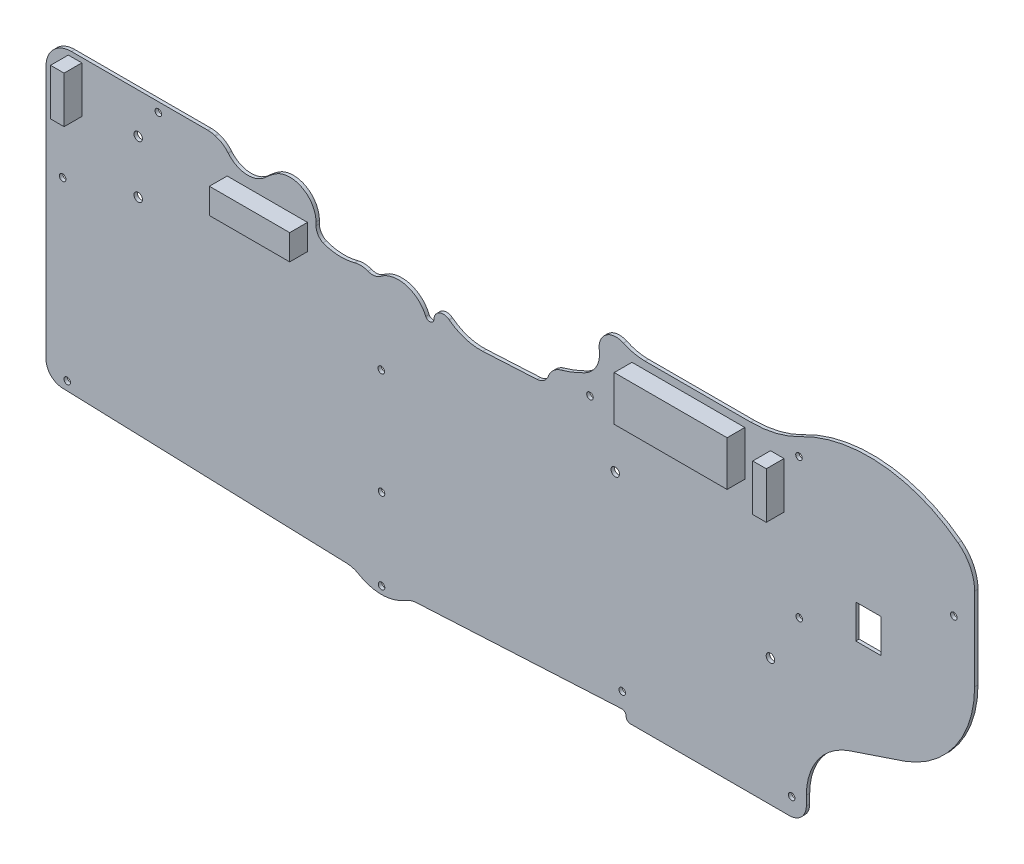
SolidWorks part; units mm, degrees
ref_plane "Piano frontale" through (0, 0, 0) normal (0, 0, 1) x (1, 0, 0)
ref_plane "Piano superiore" through (0, 0, 0) normal (0, 1, 0) x (1, 0, 0)
ref_plane "Piano destro" through (0, 0, 0) normal (1, 0, 0) x (0, 0, -1)
sketch "0" plane through (0, 0, 0) normal (0, 0, 1) x (1, 0, 0)
  line L0 (125.7508, 8.9093) -> (125.7508, 7.9088)
  line L1 (-146.1819, 97.2784) -> (-146.1819, 96.2779)
  line L2 (125.7508, 7.9088) -> (124.9498, 7.9088)
  line L3 (-146.1819, 96.2779) -> (-146.9829, 96.2779)
  line L4 (124.9498, 7.9088) -> (124.9498, 4.8082)
  line L5 (-146.9829, 96.2779) -> (-146.9829, 93.1773)
  line L6 (124.9498, 4.8082) -> (125.7508, 4.8082)
  line L7 (-146.9829, 93.1773) -> (-146.1819, 93.1773)
  line L8 (125.7508, 4.8082) -> (125.7508, -0.9905)
  line L9 (-146.1819, 93.1773) -> (-146.1819, 87.3786)
  line L10 (125.7508, -0.9905) -> (124.9498, -0.9905)
  line L11 (-146.1819, 87.3786) -> (-146.9829, 87.3786)
  line L12 (124.9498, -0.9905) -> (124.9498, -4.0911)
  line L13 (-146.9829, 87.3786) -> (-146.9829, 84.278)
  line L14 (124.9498, -4.0911) -> (125.7508, -4.0911)
  line L15 (-146.9829, 84.278) -> (-146.1819, 84.278)
  line L16 (125.7508, -4.0911) -> (125.7508, -5.0916)
  line L17 (-146.1819, 84.278) -> (-146.1819, 83.2776)
  line L18 (125.7508, -5.0916) -> (139.7498, -5.0916)
  line L19 (-146.1819, 83.2776) -> (-132.1829, 83.2776)
  line L20 (139.7498, -5.0916) -> (139.7498, -4.0911)
  line L21 (-132.1829, 83.2776) -> (-132.1829, 84.278)
  line L22 (139.7498, -4.0911) -> (140.5508, -4.0911)
  line L23 (-132.1829, 84.278) -> (-131.3819, 84.278)
  line L24 (140.5508, -4.0911) -> (140.5508, -0.9905)
  line L25 (-131.3819, 84.278) -> (-131.3819, 87.3786)
  line L26 (140.5508, -0.9905) -> (139.7498, -0.9905)
  line L27 (-131.3819, 87.3786) -> (-132.1829, 87.3786)
  line L28 (139.7498, -0.9905) -> (139.7498, 4.8082)
  line L29 (-132.1829, 87.3786) -> (-132.1829, 93.1773)
  line L30 (139.7498, 4.8082) -> (140.5508, 4.8082)
  line L31 (-132.1829, 93.1773) -> (-131.3819, 93.1773)
  line L32 (140.5508, 4.8082) -> (140.5508, 7.9088)
  line L33 (-131.3819, 93.1773) -> (-131.3819, 96.2779)
  line L34 (140.5508, 7.9088) -> (139.7498, 7.9088)
  line L35 (-131.3819, 96.2779) -> (-132.1829, 96.2779)
  line L36 (139.7498, 7.9088) -> (139.7498, 8.9093)
  line L37 (-132.1829, 96.2779) -> (-132.1829, 97.2784)
  line L38 (139.7498, 8.9093) -> (125.7508, 8.9093)
  line L39 (-132.1829, 97.2784) -> (-146.1819, 97.2784)
  line L40 (144.8008, 8.9093) -> (144.8008, 7.9088)
  line L41 (177, 32.9514) -> (177, 31.9509)
  line L42 (144.8008, 7.9088) -> (143.9998, 7.9088)
  line L43 (177, 31.9509) -> (176.199, 31.9509)
  line L44 (143.9998, 7.9088) -> (143.9998, 4.8082)
  line L45 (176.199, 31.9509) -> (176.199, 28.8503)
  line L46 (143.9998, 4.8082) -> (144.8008, 4.8082)
  line L47 (176.199, 28.8503) -> (177, 28.8503)
  line L48 (144.8008, 4.8082) -> (144.8008, -0.9905)
  line L49 (177, 28.8503) -> (177, 23.0516)
  line L50 (144.8008, -0.9905) -> (143.9998, -0.9905)
  line L51 (177, 23.0516) -> (176.199, 23.0516)
  line L52 (143.9998, -0.9905) -> (143.9998, -4.0911)
  line L53 (176.199, 23.0516) -> (176.199, 19.951)
  line L54 (143.9998, -4.0911) -> (144.8008, -4.0911)
  line L55 (176.199, 19.951) -> (177, 19.951)
  line L56 (144.8008, -4.0911) -> (144.8008, -5.0916)
  line L57 (177, 19.951) -> (177, 18.9505)
  line L58 (144.8008, -5.0916) -> (158.8008, -5.0916)
  line L59 (177, 18.9505) -> (191, 18.9505)
  line L60 (158.8008, -5.0916) -> (158.8008, -4.0911)
  line L61 (191, 18.9505) -> (191, 19.951)
  line L62 (158.8008, -4.0911) -> (159.6018, -4.0911)
  line L63 (191, 19.951) -> (191.801, 19.951)
  line L64 (159.6018, -4.0911) -> (159.6018, -0.9905)
  line L65 (191.801, 19.951) -> (191.801, 23.0516)
  line L66 (159.6018, -0.9905) -> (158.8008, -0.9905)
  line L67 (191.801, 23.0516) -> (191, 23.0516)
  line L68 (158.8008, -0.9905) -> (158.8008, 4.8082)
  line L69 (191, 23.0516) -> (191, 28.8503)
  line L70 (158.8008, 4.8082) -> (159.6018, 4.8082)
  line L71 (191, 28.8503) -> (191.801, 28.8503)
  line L72 (159.6018, 4.8082) -> (159.6018, 7.9088)
  line L73 (191.801, 28.8503) -> (191.801, 31.9509)
  line L74 (159.6018, 7.9088) -> (158.8008, 7.9088)
  line L75 (191.801, 31.9509) -> (191, 31.9509)
  line L76 (158.8008, 7.9088) -> (158.8008, 8.9093)
  line L77 (191, 31.9509) -> (191, 32.9514)
  line L78 (158.8008, 8.9093) -> (144.8008, 8.9093)
  line L79 (191, 32.9514) -> (177, 32.9514)
  line L80 (163.8488, 8.9093) -> (163.8488, 7.9088)
  line L81 (163.8488, 7.9088) -> (163.0478, 7.9088)
  line L82 (163.0478, 7.9088) -> (163.0478, 4.8082)
  line L83 (163.0478, 4.8082) -> (163.8488, 4.8082)
  line L84 (163.8488, 4.8082) -> (163.8488, -0.9905)
  line L85 (163.8488, -0.9905) -> (163.0478, -0.9905)
  line L86 (163.0478, -0.9905) -> (163.0478, -4.0911)
  line L87 (163.0478, -4.0911) -> (163.8488, -4.0911)
  line L88 (163.8488, -4.0911) -> (163.8488, -5.0916)
  line L89 (163.8488, -5.0916) -> (177.8508, -5.0916)
  line L90 (177.8508, -5.0916) -> (177.8508, -4.0911)
  line L91 (177.8508, -4.0911) -> (178.6518, -4.0911)
  line L92 (178.6518, -4.0911) -> (178.6518, -0.9905)
  line L93 (178.6518, -0.9905) -> (177.8508, -0.9905)
  line L94 (177.8508, -0.9905) -> (177.8508, 4.8082)
  line L95 (177.8508, 4.8082) -> (178.6518, 4.8082)
  line L96 (178.6518, 4.8082) -> (178.6518, 7.9088)
  line L97 (178.6518, 7.9088) -> (177.8508, 7.9088)
  line L98 (177.8508, 7.9088) -> (177.8508, 8.9093)
  line L99 (177.8508, 8.9093) -> (163.8488, 8.9093)
  line L100 (-44.1086, 8.3567) -> (-45.8316, 8.4159)
  line L101 (-45.8316, 8.4159) -> (-46.0506, 2.15)
  line L102 (-46.0506, 2.15) -> (-46.8756, 2.1789)
  line L103 (-46.8756, 2.1789) -> (-46.9726, -0.6198)
  line L104 (-46.9726, -0.6198) -> (-46.1476, -0.6488)
  line L105 (-46.1476, -0.6488) -> (-46.2616, -3.8761)
  line L106 (-46.2616, -3.8761) -> (-44.5376, -3.9367)
  line L107 (-44.5376, -3.9367) -> (-44.5686, -4.8559)
  line L108 (-44.5686, -4.8559) -> (-41.2716, -4.9717)
  line L109 (-41.2716, -4.9717) -> (-41.2396, -4.0511)
  line L110 (-41.2396, -4.0511) -> (-39.5156, -4.1118)
  line L111 (-39.5156, -4.1118) -> (-39.4026, -0.883)
  line L112 (-39.4026, -0.883) -> (-37.8786, -0.9368)
  line L113 (-37.8786, -0.9368) -> (-37.8986, -1.5362)
  line L114 (-37.8986, -1.5362) -> (-38.6986, -1.5086)
  line L115 (-38.6986, -1.5086) -> (-38.8076, -4.6065)
  line L116 (-38.8076, -4.6065) -> (-38.0066, -4.634)
  line L117 (-38.0066, -4.634) -> (-38.0426, -5.6345)
  line L118 (-38.0426, -5.6345) -> (-24.0516, -6.1223)
  line L119 (-24.0516, -6.1223) -> (-24.0156, -5.1232)
  line L120 (-24.0156, -5.1232) -> (-23.2156, -5.1522)
  line L121 (-23.2156, -5.1522) -> (-23.1086, -2.053)
  line L122 (-23.1086, -2.053) -> (-23.9076, -2.0254)
  line L123 (-23.9076, -2.0254) -> (-23.8876, -1.426)
  line L124 (-23.8876, -1.426) -> (-22.3616, -1.4783)
  line L125 (-22.3616, -1.4783) -> (-22.4746, -4.7071)
  line L126 (-22.4746, -4.7071) -> (-20.7506, -4.7677)
  line L127 (-20.7506, -4.7677) -> (-20.7826, -5.6869)
  line L128 (-20.7826, -5.6869) -> (-17.4846, -5.8012)
  line L129 (-17.4846, -5.8012) -> (-17.4526, -4.8821)
  line L130 (-17.4526, -4.8821) -> (-15.7296, -4.9427)
  line L131 (-15.7296, -4.9427) -> (-15.6176, -1.714)
  line L132 (-15.6176, -1.714) -> (-14.7916, -1.7443)
  line L133 (-14.7916, -1.7443) -> (-14.6946, 1.0558)
  line L134 (-14.6946, 1.0558) -> (-15.5186, 1.0834)
  line L135 (-15.5186, 1.0834) -> (-15.3006, 7.3507)
  line L136 (-15.3006, 7.3507) -> (-17.0246, 7.41)
  line L137 (-17.0246, 7.41) -> (-16.9906, 8.3898)
  line L138 (-16.9906, 8.3898) -> (-20.2876, 8.5041)
  line L139 (-20.2876, 8.5041) -> (-20.3226, 7.5257)
  line L140 (-20.3226, 7.5257) -> (-22.0466, 7.585)
  line L141 (-22.0466, 7.585) -> (-22.2016, 3.1188)
  line L142 (-22.2016, 3.1188) -> (-23.7266, 3.1711)
  line L143 (-23.7266, 3.1711) -> (-23.7056, 3.7719)
  line L144 (-23.7056, 3.7719) -> (-22.9056, 3.743)
  line L145 (-22.9056, 3.743) -> (-22.7976, 6.8409)
  line L146 (-22.7976, 6.8409) -> (-23.5966, 6.8698)
  line L147 (-23.5966, 6.8698) -> (-23.5626, 7.8688)
  line L148 (-23.5626, 7.8688) -> (-37.5536, 8.3567)
  line L149 (-37.5536, 8.3567) -> (-37.5876, 7.3576)
  line L150 (-37.5876, 7.3576) -> (-38.3886, 7.3852)
  line L151 (-38.3886, 7.3852) -> (-38.4956, 4.2873)
  line L152 (-38.4956, 4.2873) -> (-37.6966, 4.2598)
  line L153 (-37.6966, 4.2598) -> (-37.7186, 3.6603)
  line L154 (-37.7186, 3.6603) -> (-39.2426, 3.7127)
  line L155 (-39.2426, 3.7127) -> (-39.0856, 8.1803)
  line L156 (23.7194, 8.1189) -> (23.7717, 7.1212)
  line L157 (-39.0856, 8.1803) -> (-40.8096, 8.2409)
  line L158 (23.7717, 7.1212) -> (22.9718, 7.0792)
  line L159 (-40.8096, 8.2409) -> (-40.7756, 9.2207)
  line L160 (22.9718, 7.0792) -> (23.1341, 3.9829)
  line L161 (-40.7756, 9.2207) -> (-44.0726, 9.3351)
  line L162 (23.1341, 3.9829) -> (23.934, 4.0248)
  line L163 (-44.0726, 9.3351) -> (-44.1086, 8.3567)
  line L164 (23.934, 4.0248) -> (23.9653, 3.4262)
  line L165 (23.9653, 3.4262) -> (22.4414, 3.3464)
  line L166 (22.4414, 3.3464) -> (22.2724, 6.572)
  line L167 (22.2724, 6.572) -> (20.5498, 6.4818)
  line L168 (20.5498, 6.4818) -> (20.5017, 7.3996)
  line L169 (20.5017, 7.3996) -> (17.2072, 7.2269)
  line L170 (17.2072, 7.2269) -> (17.2553, 6.3091)
  line L171 (17.2553, 6.3091) -> (15.5326, 6.2188)
  line L172 (15.5326, 6.2188) -> (15.7017, 2.9931)
  line L173 (15.7017, 2.9931) -> (14.8768, 2.9499)
  line L174 (14.8768, 2.9499) -> (15.0234, 0.1536)
  line L175 (15.0234, 0.1536) -> (15.8482, 0.1968)
  line L176 (15.8482, 0.1968) -> (16.1764, -6.0647)
  line L177 (16.1764, -6.0647) -> (17.899, -5.9744)
  line L178 (17.899, -5.9744) -> (17.9503, -6.9529)
  line L179 (17.9503, -6.9529) -> (21.2448, -6.7802)
  line L180 (21.2448, -6.7802) -> (21.1935, -5.8018)
  line L181 (21.1935, -5.8018) -> (22.9161, -5.7115)
  line L182 (22.9161, -5.7115) -> (22.6822, -1.2472)
  line L183 (22.6822, -1.2472) -> (24.2061, -1.1674)
  line L184 (24.2061, -1.1674) -> (24.2375, -1.7674)
  line L185 (24.2375, -1.7674) -> (23.4376, -1.8094)
  line L186 (23.4376, -1.8094) -> (23.5998, -4.9043)
  line L187 (23.5998, -4.9043) -> (24.3997, -4.8624)
  line L188 (24.3997, -4.8624) -> (24.4521, -5.8614)
  line L189 (24.4521, -5.8614) -> (38.4319, -5.1288)
  line L190 (38.4319, -5.1288) -> (38.3796, -4.1297)
  line L191 (38.3796, -4.1297) -> (39.1795, -4.0878)
  line L192 (39.1795, -4.0878) -> (39.0173, -0.9929)
  line L193 (39.0173, -0.9929) -> (38.2174, -1.0348)
  line L194 (38.2174, -1.0348) -> (38.1859, -0.4347)
  line L195 (38.1859, -0.4347) -> (39.7098, -0.3549)
  line L196 (39.7098, -0.3549) -> (39.9438, -4.8191)
  line L197 (39.9438, -4.8191) -> (41.6664, -4.7288)
  line L198 (41.6664, -4.7288) -> (41.7177, -5.7073)
  line L199 (41.7177, -5.7073) -> (45.0122, -5.5346)
  line L200 (45.0122, -5.5346) -> (44.9609, -4.5562)
  line L201 (44.9609, -4.5562) -> (46.6835, -4.4659)
  line L202 (46.6835, -4.4659) -> (46.3554, 1.7956)
  line L203 (46.3554, 1.7956) -> (47.1802, 1.8388)
  line L204 (47.1802, 1.8388) -> (47.0337, 4.6352)
  line L205 (47.0337, 4.6352) -> (46.2088, 4.592)
  line L206 (46.2088, 4.592) -> (46.0398, 7.8176)
  line L207 (46.0398, 7.8176) -> (44.3171, 7.7274)
  line L208 (44.3171, 7.7274) -> (44.269, 8.6452)
  line L209 (44.269, 8.6452) -> (40.9746, 8.4725)
  line L210 (40.9746, 8.4725) -> (41.0227, 7.5547)
  line L211 (41.0227, 7.5547) -> (39.3, 7.4644)
  line L212 (39.3, 7.4644) -> (39.4691, 4.2387)
  line L213 (39.4691, 4.2387) -> (37.9452, 4.1589)
  line L214 (37.9452, 4.1589) -> (37.9138, 4.7575)
  line L215 (37.9138, 4.7575) -> (38.7137, 4.7994)
  line L216 (38.7137, 4.7994) -> (38.5514, 7.8957)
  line L217 (38.5514, 7.8957) -> (37.7515, 7.8538)
  line L218 (37.7515, 7.8538) -> (37.6992, 8.8515)
  line L219 (37.6992, 8.8515) -> (23.7194, 8.1189)
  line L220 (-124.5132, 10.6803) -> (-124.5132, 9.6812)
  line L221 (-124.5132, 9.6812) -> (-125.3122, 9.6812)
  line L222 (-125.3122, 9.6812) -> (-125.3122, 6.5806)
  line L223 (-125.3122, 6.5806) -> (-124.5132, 6.5806)
  line L224 (-124.5132, 6.5806) -> (-124.5132, 0.7804)
  line L225 (-124.5132, 0.7804) -> (-125.3122, 0.7804)
  line L226 (-125.3122, 0.7804) -> (-125.3122, -2.3188)
  line L227 (-125.3122, -2.3188) -> (-124.5132, -2.3188)
  line L228 (-124.5132, -2.3188) -> (-124.5132, -3.3192)
  line L229 (-124.5132, -3.3192) -> (-110.5121, -3.3192)
  line L230 (-110.5121, -3.3192) -> (-110.5121, -2.3188)
  line L231 (-110.5121, -2.3188) -> (-109.7127, -2.3188)
  line L232 (-109.7127, -2.3188) -> (-109.7127, 0.7804)
  line L233 (-109.7127, 0.7804) -> (-110.5121, 0.7804)
  line L234 (-110.5121, 0.7804) -> (-110.5121, 6.5806)
  line L235 (-110.5121, 6.5806) -> (-109.7127, 6.5806)
  line L236 (-109.7127, 6.5806) -> (-109.7127, 9.6812)
  line L237 (-109.7127, 9.6812) -> (-110.5121, 9.6812)
  line L238 (-110.5121, 9.6812) -> (-110.5121, 10.6803)
  line L239 (-110.5121, 10.6803) -> (-124.5132, 10.6803)
  line L240 (-99.5931, 10.2215) -> (-99.628, 9.223)
  line L241 (-99.628, 9.223) -> (-100.4275, 9.2509)
  line L242 (-100.4275, 9.2509) -> (-100.5357, 6.1522)
  line L243 (-100.5357, 6.1522) -> (-99.7362, 6.1243)
  line L244 (-99.7362, 6.1243) -> (-99.9386, 0.3276)
  line L245 (-99.9386, 0.3276) -> (-100.7381, 0.3556)
  line L246 (-100.7381, 0.3556) -> (-100.8463, -2.7417)
  line L247 (-100.8463, -2.7417) -> (-100.0468, -2.7697)
  line L248 (-100.0468, -2.7697) -> (-100.0817, -3.7695)
  line L249 (-100.0817, -3.7695) -> (-86.0902, -4.258)
  line L250 (-86.0902, -4.258) -> (-86.0553, -3.2583)
  line L251 (-86.0553, -3.2583) -> (-85.2548, -3.2862)
  line L252 (-85.2548, -3.2862) -> (-85.1466, -0.1889)
  line L253 (-85.1466, -0.1889) -> (-85.9471, -0.1609)
  line L254 (-85.9471, -0.1609) -> (-85.7447, 5.6357)
  line L255 (-85.7447, 5.6357) -> (-84.9442, 5.6078)
  line L256 (-84.9442, 5.6078) -> (-84.836, 8.7065)
  line L257 (-84.836, 8.7065) -> (-85.6365, 8.7344)
  line L258 (-85.6365, 8.7344) -> (-85.6016, 9.7329)
  line L259 (-85.6016, 9.7329) -> (-99.5931, 10.2215)
  line L260 (-74.7946, 9.3905) -> (-74.8295, 8.392)
  line L261 (-74.8295, 8.392) -> (-75.628, 8.4198)
  line L262 (-75.628, 8.4198) -> (-75.7362, 5.3211)
  line L263 (-75.7362, 5.3211) -> (-74.9377, 5.2933)
  line L264 (-74.9377, 5.2933) -> (-75.1401, -0.5034)
  line L265 (-75.1401, -0.5034) -> (-75.9386, -0.4755)
  line L266 (-75.9386, -0.4755) -> (-76.0468, -3.5728)
  line L267 (-76.0468, -3.5728) -> (-75.2483, -3.6007)
  line L268 (-75.2483, -3.6007) -> (-75.2832, -4.6005)
  line L269 (-75.2832, -4.6005) -> (-61.2907, -5.0891)
  line L270 (-61.2907, -5.0891) -> (-61.2558, -4.0894)
  line L271 (-61.2558, -4.0894) -> (-60.4573, -4.1172)
  line L272 (-60.4573, -4.1172) -> (-60.3491, -1.0199)
  line L273 (-60.3491, -1.0199) -> (-61.1476, -0.992)
  line L274 (-61.1476, -0.992) -> (-60.9452, 4.8046)
  line L275 (-60.9452, 4.8046) -> (-60.1467, 4.7767)
  line L276 (-60.1467, 4.7767) -> (-60.0385, 7.8755)
  line L277 (-60.0385, 7.8755) -> (-60.837, 7.9033)
  line L278 (-60.837, 7.9033) -> (-60.8021, 8.9018)
  line L279 (-60.8021, 8.9018) -> (-74.7946, 9.3905)
  line L280 (61.1769, 9.8704) -> (61.2292, 8.8726)
  line L281 (61.2292, 8.8726) -> (60.4293, 8.8307)
  line L282 (60.4293, 8.8307) -> (60.5915, 5.7344)
  line L283 (60.5915, 5.7344) -> (61.3914, 5.7763)
  line L284 (61.3914, 5.7763) -> (61.695, -0.016)
  line L285 (61.695, -0.016) -> (60.8951, -0.0579)
  line L286 (60.8951, -0.0579) -> (61.0573, -3.1528)
  line L287 (61.0573, -3.1528) -> (61.8572, -3.1109)
  line L288 (61.8572, -3.1109) -> (61.9096, -4.1099)
  line L289 (61.9096, -4.1099) -> (75.8894, -3.3773)
  line L290 (75.8894, -3.3773) -> (75.837, -2.3783)
  line L291 (75.837, -2.3783) -> (76.6369, -2.3363)
  line L292 (76.6369, -2.3363) -> (76.4747, 0.7586)
  line L293 (76.4747, 0.7586) -> (75.6748, 0.7167)
  line L294 (75.6748, 0.7167) -> (75.3713, 6.5089)
  line L295 (75.3713, 6.5089) -> (76.1712, 6.5509)
  line L296 (76.1712, 6.5509) -> (76.0089, 9.6472)
  line L297 (76.0089, 9.6472) -> (75.209, 9.6053)
  line L298 (75.209, 9.6053) -> (75.1567, 10.603)
  line L299 (75.1567, 10.603) -> (61.1769, 9.8704)
  line L300 (84.9562, 11.1166) -> (85.0085, 10.1189)
  line L301 (85.0085, 10.1189) -> (84.2106, 10.077)
  line L302 (84.2106, 10.077) -> (84.3729, 6.9807)
  line L303 (84.3729, 6.9807) -> (85.1708, 7.0225)
  line L304 (85.1708, 7.0225) -> (85.4744, 1.2303)
  line L305 (85.4744, 1.2303) -> (84.6765, 1.1884)
  line L306 (84.6765, 1.1884) -> (84.8387, -1.9065)
  line L307 (84.8387, -1.9065) -> (85.6366, -1.8647)
  line L308 (85.6366, -1.8647) -> (85.6889, -2.8637)
  line L309 (85.6889, -2.8637) -> (99.6697, -2.131)
  line L310 (99.6697, -2.131) -> (99.6174, -1.132)
  line L311 (99.6174, -1.132) -> (100.4163, -1.0901)
  line L312 (100.4163, -1.0901) -> (100.2541, 2.0048)
  line L313 (100.2541, 2.0048) -> (99.4552, 1.963)
  line L314 (99.4552, 1.963) -> (99.1516, 7.7552)
  line L315 (99.1516, 7.7552) -> (99.9505, 7.7971)
  line L316 (99.9505, 7.7971) -> (99.7882, 10.8934)
  line L317 (99.7882, 10.8934) -> (98.9893, 10.8516)
  line L318 (98.9893, 10.8516) -> (98.9371, 11.8493)
  line L319 (98.9371, 11.8493) -> (84.9562, 11.1166)
  line L320 (144.8008, 27.9592) -> (144.8008, 26.9588)
  line L321 (177, 52.0013) -> (177, 51.0009)
  line L322 (177, 71.0513) -> (177, 70.0509)
  line L323 (144.8008, 26.9588) -> (143.9998, 26.9588)
  line L324 (177, 51.0009) -> (176.199, 51.0009)
  line L325 (177, 70.0509) -> (176.199, 70.0509)
  line L326 (143.9998, 26.9588) -> (143.9998, 23.8582)
  line L327 (176.199, 51.0009) -> (176.199, 47.9003)
  line L328 (176.199, 70.0509) -> (176.199, 66.9503)
  line L329 (143.9998, 23.8582) -> (144.8008, 23.8582)
  line L330 (176.199, 47.9003) -> (177, 47.9003)
  line L331 (176.199, 66.9503) -> (177, 66.9503)
  line L332 (144.8008, 23.8582) -> (144.8008, 18.0595)
  line L333 (177, 47.9003) -> (177, 42.1016)
  line L334 (177, 66.9503) -> (177, 61.1516)
  line L335 (144.8008, 18.0595) -> (143.9998, 18.0595)
  line L336 (177, 42.1016) -> (176.199, 42.1016)
  line L337 (177, 61.1516) -> (176.199, 61.1516)
  line L338 (143.9998, 18.0595) -> (143.9998, 14.9589)
  line L339 (176.199, 42.1016) -> (176.199, 39.001)
  line L340 (176.199, 61.1516) -> (176.199, 58.051)
  line L341 (143.9998, 14.9589) -> (144.8008, 14.9589)
  line L342 (176.199, 39.001) -> (177, 39.001)
  line L343 (176.199, 58.051) -> (177, 58.051)
  line L344 (144.8008, 14.9589) -> (144.8008, 13.9584)
  line L345 (177, 39.001) -> (177, 38.0005)
  line L346 (177, 58.051) -> (177, 57.0505)
  line L347 (144.8008, 13.9584) -> (158.8008, 13.9584)
  line L348 (177, 38.0005) -> (191, 38.0005)
  line L349 (177, 57.0505) -> (191, 57.0505)
  line L350 (158.8008, 13.9584) -> (158.8008, 14.9589)
  line L351 (191, 38.0005) -> (191, 39.001)
  line L352 (191, 57.0505) -> (191, 58.051)
  line L353 (158.8008, 14.9589) -> (159.6018, 14.9589)
  line L354 (191, 39.001) -> (191.801, 39.001)
  line L355 (191, 58.051) -> (191.801, 58.051)
  line L356 (159.6018, 14.9589) -> (159.6018, 18.0595)
  line L357 (191.801, 39.001) -> (191.801, 42.1016)
  line L358 (191.801, 58.051) -> (191.801, 61.1516)
  line L359 (159.6018, 18.0595) -> (158.8008, 18.0595)
  line L360 (191.801, 42.1016) -> (191, 42.1016)
  line L361 (191.801, 61.1516) -> (191, 61.1516)
  line L362 (158.8008, 18.0595) -> (158.8008, 23.8582)
  line L363 (191, 42.1016) -> (191, 47.9003)
  line L364 (191, 61.1516) -> (191, 66.9503)
  line L365 (158.8008, 23.8582) -> (159.6018, 23.8582)
  line L366 (191, 47.9003) -> (191.801, 47.9003)
  line L367 (191, 66.9503) -> (191.801, 66.9503)
  line L368 (159.6018, 23.8582) -> (159.6018, 26.9588)
  line L369 (191.801, 47.9003) -> (191.801, 51.0009)
  line L370 (191.801, 66.9503) -> (191.801, 70.0509)
  line L371 (159.6018, 26.9588) -> (158.8008, 26.9588)
  line L372 (191.801, 51.0009) -> (191, 51.0009)
  line L373 (191.801, 70.0509) -> (191, 70.0509)
  line L374 (158.8008, 26.9588) -> (158.8008, 27.9592)
  line L375 (191, 51.0009) -> (191, 52.0013)
  line L376 (191, 70.0509) -> (191, 71.0513)
  line L377 (158.8008, 27.9592) -> (144.8008, 27.9592)
  line L378 (191, 52.0013) -> (177, 52.0013)
  line L379 (191, 71.0513) -> (177, 71.0513)
  line L380 (27, 88.0936) -> (-28, 88.0936)
  line L381 (-7, 7) -> (-7, 6.0009)
  line L382 (-148.7544, 21.6507) -> (-149.5548, 21.6507)
  line L383 (-7, 6.0009) -> (-7.8004, 6.0009)
  line L384 (-149.5548, 21.6507) -> (-149.5548, 18.5501)
  line L385 (-7.8004, 6.0009) -> (-7.8004, 2.9003)
  line L386 (-149.5548, 18.5501) -> (-148.7544, 18.5501)
  line L387 (-7.8004, 2.9003) -> (-7, 2.9003)
  line L388 (-106.1319, 84.277) -> (-161, 84.277)
  line L389 (-7, 2.9003) -> (-7, -2.8999)
  line L390 (-148.7544, 12.7499) -> (-149.5548, 12.7499)
  line L391 (-7, -2.8999) -> (-7.8004, -2.8999)
  line L392 (-149.5548, 12.7499) -> (-149.5548, 9.6507)
  line L393 (-7.8004, -2.8999) -> (-7.8004, -5.9991)
  line L394 (-149.5548, 9.6507) -> (-148.7544, 9.6507)
  line L395 (-7.8004, -5.9991) -> (-7, -5.9991)
  line L397 (-7, -5.9991) -> (-7, -6.9995)
  line L398 (-148.7544, 8.6503) -> (-134.7547, 8.6503)
  line L399 (-7, -6.9995) -> (6.9997, -6.9995)
  line L400 (-134.7547, 8.6503) -> (-134.7547, 9.6507)
  line L401 (6.9997, -6.9995) -> (6.9997, -5.9991)
  line L402 (-134.7547, 9.6507) -> (-133.9557, 9.6507)
  line L403 (6.9997, -5.9991) -> (7.7987, -5.9991)
  line L404 (-133.9557, 9.6507) -> (-133.9557, 12.7499)
  line L405 (7.7987, -5.9991) -> (7.7987, -2.8999)
  line L406 (-133.9557, 12.7499) -> (-134.7547, 12.7499)
  line L407 (7.7987, -2.8999) -> (6.9997, -2.8999)
  line L408 (-134.7547, 12.7499) -> (-134.7547, 18.5501)
  line L409 (6.9997, -2.8999) -> (6.9997, 2.9003)
  line L410 (-134.7547, 18.5501) -> (-133.9557, 18.5501)
  line L411 (6.9997, 2.9003) -> (7.7987, 2.9003)
  line L412 (-133.9557, 18.5501) -> (-133.9557, 21.6507)
  line L413 (7.7987, 2.9003) -> (7.7987, 6.0009)
  line L414 (-133.9557, 21.6507) -> (-134.7547, 21.6507)
  line L415 (7.7987, 6.0009) -> (6.9997, 6.0009)
  line L416 (-134.7547, 21.6507) -> (-134.7547, 22.6498)
  line L417 (6.9997, 6.0009) -> (6.9997, 7)
  line L418 (-134.7547, 22.6498) -> (-148.7544, 22.6498)
  line L419 (6.9997, 7) -> (-7, 7)
  line L420 (-124.5132, 34.1285) -> (-124.5132, 33.128)
  line L421 (-124.5132, 33.128) -> (-125.3122, 33.128)
  line L422 (-125.3122, 33.128) -> (-125.3122, 30.0285)
  line L423 (-125.3122, 30.0285) -> (-124.5132, 30.0285)
  line L424 (-124.5132, 30.0285) -> (-124.5132, 24.2271)
  line L425 (-124.5132, 24.2271) -> (-125.3122, 24.2271)
  line L426 (-125.3122, 24.2271) -> (-125.3122, 21.1279)
  line L427 (-125.3122, 21.1279) -> (-124.5132, 21.1279)
  line L428 (-124.5132, 21.1279) -> (-124.5132, 20.1275)
  line L429 (-124.5132, 20.1275) -> (-110.5121, 20.1275)
  line L430 (-110.5121, 20.1275) -> (-110.5121, 21.1279)
  line L431 (-110.5121, 21.1279) -> (-109.7127, 21.1279)
  line L432 (-109.7127, 21.1279) -> (-109.7127, 24.2271)
  line L433 (-109.7127, 24.2271) -> (-110.5121, 24.2271)
  line L434 (-110.5121, 24.2271) -> (-110.5121, 30.0285)
  line L435 (-110.5121, 30.0285) -> (-109.7127, 30.0285)
  line L436 (-109.7127, 30.0285) -> (-109.7127, 33.128)
  line L437 (-109.7127, 33.128) -> (-110.5121, 33.128)
  line L438 (-110.5121, 33.128) -> (-110.5121, 34.1285)
  line L439 (-110.5121, 34.1285) -> (-124.5132, 34.1285)
  line L440 (-101.1692, 33.8521) -> (-101.2216, 32.853)
  line L441 (-101.2216, 32.853) -> (-102.0194, 32.8948)
  line L442 (-102.0194, 32.8948) -> (-102.1816, 29.7996)
  line L443 (-102.1816, 29.7996) -> (-101.3838, 29.7578)
  line L444 (-101.3838, 29.7578) -> (-101.6874, 23.9643)
  line L445 (-101.6874, 23.9643) -> (-102.4852, 24.0061)
  line L446 (-102.4852, 24.0061) -> (-102.6474, 20.9112)
  line L447 (-102.6474, 20.9112) -> (-101.8496, 20.8694)
  line L448 (-101.8496, 20.8694) -> (-101.902, 19.8703)
  line L449 (-101.902, 19.8703) -> (-87.9211, 19.1376)
  line L450 (-87.9211, 19.1376) -> (-87.8688, 20.1367)
  line L451 (-87.8688, 20.1367) -> (-87.0689, 20.0947)
  line L452 (-87.0689, 20.0947) -> (-86.9067, 23.1897)
  line L453 (-86.9067, 23.1897) -> (-87.7066, 23.2316)
  line L454 (-87.7066, 23.2316) -> (-87.403, 29.0251)
  line L455 (-87.403, 29.0251) -> (-86.6031, 28.9831)
  line L456 (-86.6031, 28.9831) -> (-86.4409, 32.0784)
  line L457 (-86.4409, 32.0784) -> (-87.2408, 32.1203)
  line L458 (-87.2408, 32.1203) -> (-87.1884, 33.1194)
  line L459 (-87.1884, 33.1194) -> (-101.1692, 33.8521)
  line L460 (-82.1453, 32.8551) -> (-82.1977, 31.856)
  line L461 (-82.1977, 31.856) -> (-82.9956, 31.8978)
  line L462 (-82.9956, 31.8978) -> (-83.1578, 28.8026)
  line L463 (-83.1578, 28.8026) -> (-82.3599, 28.7608)
  line L464 (-82.3599, 28.7608) -> (-82.6635, 22.9673)
  line L465 (-82.6635, 22.9673) -> (-83.4614, 23.0091)
  line L466 (-83.4614, 23.0091) -> (-83.6236, 19.9142)
  line L467 (-83.6236, 19.9142) -> (-82.8257, 19.8724)
  line L468 (-82.8257, 19.8724) -> (-82.8781, 18.8733)
  line L469 (-82.8781, 18.8733) -> (-68.8973, 18.1406)
  line L470 (-68.8973, 18.1406) -> (-68.8449, 19.1397)
  line L471 (-68.8449, 19.1397) -> (-68.045, 19.0977)
  line L472 (-68.045, 19.0977) -> (-67.8828, 22.1927)
  line L473 (-67.8828, 22.1927) -> (-68.6827, 22.2346)
  line L474 (-68.6827, 22.2346) -> (-68.3791, 28.0281)
  line L475 (-68.3791, 28.0281) -> (-67.5792, 27.9861)
  line L476 (-67.5792, 27.9861) -> (-67.417, 31.0814)
  line L477 (-67.417, 31.0814) -> (-68.2169, 31.1233)
  line L478 (-68.2169, 31.1233) -> (-68.1645, 32.1224)
  line L479 (-68.1645, 32.1224) -> (-82.1453, 32.8551)
  line L480 (-63.1214, 31.8581) -> (-63.1738, 30.859)
  line L481 (-63.1738, 30.859) -> (-63.9717, 30.9008)
  line L482 (-63.9717, 30.9008) -> (-64.1339, 27.8056)
  line L483 (-64.1339, 27.8056) -> (-63.336, 27.7638)
  line L484 (-63.336, 27.7638) -> (-63.6396, 21.9703)
  line L485 (-63.6396, 21.9703) -> (-64.4375, 22.0121)
  line L486 (-64.4375, 22.0121) -> (-64.5997, 18.9172)
  line L487 (-64.5997, 18.9172) -> (-63.8018, 18.8754)
  line L488 (-63.8018, 18.8754) -> (-63.8542, 17.8763)
  line L489 (-63.8542, 17.8763) -> (-49.8734, 17.1436)
  line L490 (-49.8734, 17.1436) -> (-49.821, 18.1427)
  line L491 (-49.821, 18.1427) -> (-49.0211, 18.1007)
  line L492 (-49.0211, 18.1007) -> (-48.8589, 21.1957)
  line L493 (-48.8589, 21.1957) -> (-49.6588, 21.2376)
  line L494 (-49.6588, 21.2376) -> (-49.3552, 27.0311)
  line L495 (-49.3552, 27.0311) -> (-48.5553, 26.9891)
  line L496 (-48.5553, 26.9891) -> (-48.3931, 30.0844)
  line L497 (-48.3931, 30.0844) -> (-49.193, 30.1263)
  line L498 (-49.193, 30.1263) -> (-49.1406, 31.1254)
  line L499 (-49.1406, 31.1254) -> (-63.1214, 31.8581)
  line L500 (-44.0975, 30.8611) -> (-44.1499, 29.862)
  line L501 (-44.1499, 29.862) -> (-44.9478, 29.9038)
  line L502 (-44.9478, 29.9038) -> (-45.11, 26.8086)
  line L503 (-45.11, 26.8086) -> (-44.3121, 26.7668)
  line L504 (-44.3121, 26.7668) -> (-44.6157, 20.9733)
  line L505 (-44.6157, 20.9733) -> (-45.4136, 21.0151)
  line L506 (-45.4136, 21.0151) -> (-45.5758, 17.9202)
  line L507 (-45.5758, 17.9202) -> (-44.7779, 17.8784)
  line L508 (-44.7779, 17.8784) -> (-44.8303, 16.8793)
  line L509 (-44.8303, 16.8793) -> (-30.8495, 16.1466)
  line L510 (-30.8495, 16.1466) -> (-30.7971, 17.1457)
  line L511 (-30.7971, 17.1457) -> (-29.9972, 17.1037)
  line L512 (-29.9972, 17.1037) -> (-29.835, 20.1987)
  line L513 (-29.835, 20.1987) -> (-30.6349, 20.2406)
  line L514 (-30.6349, 20.2406) -> (-30.3313, 26.0341)
  line L515 (-30.3313, 26.0341) -> (-29.5314, 25.9921)
  line L516 (-29.5314, 25.9921) -> (-29.3692, 29.0874)
  line L517 (-29.3692, 29.0874) -> (-30.1691, 29.1293)
  line L518 (-30.1691, 29.1293) -> (-30.1167, 30.1284)
  line L519 (-30.1167, 30.1284) -> (-44.0975, 30.8611)
  line L520 (-25.0736, 29.8641) -> (-25.126, 28.865)
  line L521 (-25.126, 28.865) -> (-25.9239, 28.9068)
  line L522 (-25.9239, 28.9068) -> (-26.0861, 25.8116)
  line L523 (-26.0861, 25.8116) -> (-25.2882, 25.7698)
  line L524 (-25.2882, 25.7698) -> (-25.5918, 19.9763)
  line L525 (-25.5918, 19.9763) -> (-26.3897, 20.0181)
  line L526 (-26.3897, 20.0181) -> (-26.5519, 16.9232)
  line L527 (-26.5519, 16.9232) -> (-25.754, 16.8814)
  line L528 (-25.754, 16.8814) -> (-25.8064, 15.8823)
  line L529 (-25.8064, 15.8823) -> (-11.8256, 15.1496)
  line L530 (-11.8256, 15.1496) -> (-11.7732, 16.1487)
  line L531 (-11.7732, 16.1487) -> (-10.9733, 16.1067)
  line L532 (-10.9733, 16.1067) -> (-10.8111, 19.2017)
  line L533 (-10.8111, 19.2017) -> (-11.611, 19.2436)
  line L534 (-11.611, 19.2436) -> (-11.3074, 25.0371)
  line L535 (-11.3074, 25.0371) -> (-10.5075, 24.9951)
  line L536 (-10.5075, 24.9951) -> (-10.3453, 28.0904)
  line L537 (-10.3453, 28.0904) -> (-11.1452, 28.1323)
  line L538 (-11.1452, 28.1323) -> (-11.0928, 29.1314)
  line L539 (-11.0928, 29.1314) -> (-25.0736, 29.8641)
  line L540 (11.0928, 29.1314) -> (11.1452, 28.1323)
  line L541 (11.1452, 28.1323) -> (10.3453, 28.0904)
  line L542 (10.3453, 28.0904) -> (10.5075, 24.9951)
  line L543 (10.5075, 24.9951) -> (11.3074, 25.0371)
  line L544 (11.3074, 25.0371) -> (11.611, 19.2436)
  line L545 (11.611, 19.2436) -> (10.8111, 19.2017)
  line L546 (10.8111, 19.2017) -> (10.9733, 16.1067)
  line L547 (10.9733, 16.1067) -> (11.7732, 16.1487)
  line L548 (11.7732, 16.1487) -> (11.8256, 15.1496)
  line L549 (11.8256, 15.1496) -> (25.8054, 15.8823)
  line L550 (25.8054, 15.8823) -> (25.753, 16.8813)
  line L551 (25.753, 16.8813) -> (26.5529, 16.9232)
  line L552 (26.5529, 16.9232) -> (26.3907, 20.0182)
  line L553 (26.3907, 20.0182) -> (25.5908, 19.9763)
  line L554 (25.5908, 19.9763) -> (25.2872, 25.7697)
  line L555 (25.2872, 25.7697) -> (26.0871, 25.8116)
  line L556 (26.0871, 25.8116) -> (25.9249, 28.9069)
  line L557 (25.9249, 28.9069) -> (25.125, 28.865)
  line L558 (25.125, 28.865) -> (25.0726, 29.8641)
  line L559 (25.0726, 29.8641) -> (11.0928, 29.1314)
  line L560 (30.1167, 30.1284) -> (30.1691, 29.1293)
  line L561 (30.1691, 29.1293) -> (29.3692, 29.0874)
  line L562 (29.3692, 29.0874) -> (29.5314, 25.9921)
  line L563 (29.5314, 25.9921) -> (30.3313, 26.0341)
  line L564 (30.3313, 26.0341) -> (30.6349, 20.2406)
  line L565 (30.6349, 20.2406) -> (29.835, 20.1987)
  line L566 (29.835, 20.1987) -> (29.9972, 17.1037)
  line L567 (29.9972, 17.1037) -> (30.7971, 17.1457)
  line L568 (30.7971, 17.1457) -> (30.8495, 16.1466)
  line L569 (30.8495, 16.1466) -> (44.8293, 16.8793)
  line L570 (44.8293, 16.8793) -> (44.7769, 17.8783)
  line L571 (44.7769, 17.8783) -> (45.5768, 17.9202)
  line L572 (45.5768, 17.9202) -> (45.4146, 21.0152)
  line L573 (45.4146, 21.0152) -> (44.6147, 20.9733)
  line L574 (44.6147, 20.9733) -> (44.3111, 26.7667)
  line L575 (44.3111, 26.7667) -> (45.111, 26.8086)
  line L576 (45.111, 26.8086) -> (44.9488, 29.9039)
  line L577 (44.9488, 29.9039) -> (44.1489, 29.862)
  line L578 (44.1489, 29.862) -> (44.0965, 30.8611)
  line L579 (44.0965, 30.8611) -> (30.1167, 30.1284)
  line L580 (49.1406, 31.1254) -> (49.193, 30.1263)
  line L581 (49.193, 30.1263) -> (48.3931, 30.0844)
  line L582 (48.3931, 30.0844) -> (48.5553, 26.9891)
  line L583 (48.5553, 26.9891) -> (49.3552, 27.0311)
  line L584 (49.3552, 27.0311) -> (49.6588, 21.2376)
  line L585 (49.6588, 21.2376) -> (48.8589, 21.1957)
  line L586 (48.8589, 21.1957) -> (49.0211, 18.1007)
  line L587 (49.0211, 18.1007) -> (49.821, 18.1427)
  line L588 (49.821, 18.1427) -> (49.8734, 17.1436)
  line L589 (49.8734, 17.1436) -> (63.8532, 17.8763)
  line L590 (63.8532, 17.8763) -> (63.8008, 18.8753)
  line L591 (63.8008, 18.8753) -> (64.5987, 18.9171)
  line L592 (64.5987, 18.9171) -> (64.4365, 22.0121)
  line L593 (64.4365, 22.0121) -> (63.6386, 21.9703)
  line L594 (63.6386, 21.9703) -> (63.335, 27.7637)
  line L595 (63.335, 27.7637) -> (64.1329, 27.8055)
  line L596 (64.1329, 27.8055) -> (63.9707, 30.9008)
  line L597 (63.9707, 30.9008) -> (63.1728, 30.859)
  line L598 (63.1728, 30.859) -> (63.1204, 31.8581)
  line L599 (63.1204, 31.8581) -> (49.1406, 31.1254)
  line L600 (68.1625, 32.1223) -> (68.2149, 31.1232)
  line L601 (68.2149, 31.1232) -> (67.417, 31.0814)
  line L602 (67.417, 31.0814) -> (67.5792, 27.9861)
  line L603 (67.5792, 27.9861) -> (68.3771, 28.0279)
  line L604 (68.3771, 28.0279) -> (68.6807, 22.2345)
  line L605 (68.6807, 22.2345) -> (67.8828, 22.1927)
  line L606 (67.8828, 22.1927) -> (68.045, 19.0977)
  line L607 (68.045, 19.0977) -> (68.8429, 19.1395)
  line L608 (68.8429, 19.1395) -> (68.8953, 18.1405)
  line L609 (68.8953, 18.1405) -> (82.8771, 18.8733)
  line L610 (82.8771, 18.8733) -> (82.8247, 19.8723)
  line L611 (82.8247, 19.8723) -> (83.6246, 19.9142)
  line L612 (83.6246, 19.9142) -> (83.4624, 23.0092)
  line L613 (83.4624, 23.0092) -> (82.6625, 22.9673)
  line L614 (82.6625, 22.9673) -> (82.3589, 28.7607)
  line L615 (82.3589, 28.7607) -> (83.1588, 28.8026)
  line L616 (83.1588, 28.8026) -> (82.9966, 31.8979)
  line L617 (82.9966, 31.8979) -> (82.1967, 31.856)
  line L618 (82.1967, 31.856) -> (82.1443, 32.8551)
  line L619 (82.1443, 32.8551) -> (68.1625, 32.1223)
  line L620 (87.1884, 33.1194) -> (87.2408, 32.1203)
  line L621 (87.2408, 32.1203) -> (86.4409, 32.0784)
  line L622 (86.4409, 32.0784) -> (86.6031, 28.9831)
  line L623 (86.6031, 28.9831) -> (87.403, 29.0251)
  line L624 (87.403, 29.0251) -> (87.7066, 23.2316)
  line L625 (87.7066, 23.2316) -> (86.9067, 23.1897)
  line L626 (86.9067, 23.1897) -> (87.0689, 20.0947)
  line L627 (87.0689, 20.0947) -> (87.8688, 20.1367)
  line L628 (87.8688, 20.1367) -> (87.9211, 19.1376)
  line L629 (87.9211, 19.1376) -> (101.901, 19.8703)
  line L630 (101.901, 19.8703) -> (101.8486, 20.8693)
  line L631 (101.8486, 20.8693) -> (102.6485, 20.9112)
  line L632 (102.6485, 20.9112) -> (102.4863, 24.0062)
  line L633 (102.4863, 24.0062) -> (101.6864, 23.9643)
  line L634 (101.6864, 23.9643) -> (101.3828, 29.7577)
  line L635 (101.3828, 29.7577) -> (102.1827, 29.7996)
  line L636 (102.1827, 29.7996) -> (102.0205, 32.8949)
  line L637 (102.0205, 32.8949) -> (101.2206, 32.853)
  line L638 (101.2206, 32.853) -> (101.1682, 33.8521)
  line L639 (101.1682, 33.8521) -> (87.1884, 33.1194)
  line L640 (108.59, 34.241) -> (108.6424, 33.2419)
  line L641 (108.6424, 33.2419) -> (107.8425, 33.2)
  line L642 (107.8425, 33.2) -> (108.0047, 30.1047)
  line L643 (108.0047, 30.1047) -> (108.8046, 30.1467)
  line L644 (108.8046, 30.1467) -> (109.1082, 24.3532)
  line L645 (109.1082, 24.3532) -> (108.3083, 24.3113)
  line L646 (108.3083, 24.3113) -> (108.4705, 21.2163)
  line L647 (108.4705, 21.2163) -> (109.2704, 21.2583)
  line L648 (109.2704, 21.2583) -> (109.3228, 20.2592)
  line L649 (109.3228, 20.2592) -> (123.3026, 20.9919)
  line L650 (123.3026, 20.9919) -> (123.2502, 21.9909)
  line L651 (123.2502, 21.9909) -> (124.0501, 22.0328)
  line L652 (124.0501, 22.0328) -> (123.8879, 25.1278)
  line L653 (123.8879, 25.1278) -> (123.088, 25.0859)
  line L654 (123.088, 25.0859) -> (122.7844, 30.8793)
  line L655 (122.7844, 30.8793) -> (123.5843, 30.9212)
  line L656 (123.5843, 30.9212) -> (123.4221, 34.0165)
  line L657 (123.4221, 34.0165) -> (122.6222, 33.9746)
  line L658 (122.6222, 33.9746) -> (122.5698, 34.9737)
  line L659 (122.5698, 34.9737) -> (108.59, 34.241)
  line L660 (-129.2757, 53.1786) -> (-129.2757, 52.1781)
  line L661 (-129.2757, 52.1781) -> (-130.0761, 52.1781)
  line L662 (-130.0761, 52.1781) -> (-130.0761, 49.0775)
  line L663 (-130.0761, 49.0775) -> (-129.2757, 49.0775)
  line L664 (-129.2757, 49.0775) -> (-129.2757, 43.2772)
  line L665 (-129.2757, 43.2772) -> (-130.0761, 43.2772)
  line L666 (-130.0761, 43.2772) -> (-130.0761, 40.178)
  line L667 (-130.0761, 40.178) -> (-129.2757, 40.178)
  line L668 (-129.2757, 40.178) -> (-129.2757, 39.1775)
  line L669 (-129.2757, 39.1775) -> (-115.276, 39.1775)
  line L670 (-115.276, 39.1775) -> (-115.276, 40.178)
  line L671 (-115.276, 40.178) -> (-114.4752, 40.178)
  line L672 (-114.4752, 40.178) -> (-114.4752, 43.2772)
  line L673 (-114.4752, 43.2772) -> (-115.276, 43.2772)
  line L674 (-115.276, 43.2772) -> (-115.276, 49.0775)
  line L675 (-115.276, 49.0775) -> (-114.4752, 49.0775)
  line L676 (-114.4752, 49.0775) -> (-114.4752, 52.1781)
  line L677 (-114.4752, 52.1781) -> (-115.276, 52.1781)
  line L678 (-115.276, 52.1781) -> (-115.276, 53.1786)
  line L679 (-115.276, 53.1786) -> (-129.2757, 53.1786)
  line L680 (-100.1722, 52.876) -> (-100.2246, 51.8769)
  line L681 (-100.2246, 51.8769) -> (-101.0224, 51.9187)
  line L682 (-101.0224, 51.9187) -> (-101.1846, 48.8224)
  line L683 (-101.1846, 48.8224) -> (-100.3868, 48.7806)
  line L684 (-100.3868, 48.7806) -> (-100.6904, 42.9882)
  line L685 (-100.6904, 42.9882) -> (-101.4882, 43.03)
  line L686 (-101.4882, 43.03) -> (-101.6504, 39.9351)
  line L687 (-101.6504, 39.9351) -> (-100.8526, 39.8932)
  line L688 (-100.8526, 39.8932) -> (-100.905, 38.8941)
  line L689 (-100.905, 38.8941) -> (-86.9242, 38.1614)
  line L690 (-86.9242, 38.1614) -> (-86.8718, 39.1605)
  line L691 (-86.8718, 39.1605) -> (-86.0719, 39.1186)
  line L692 (-86.0719, 39.1186) -> (-85.9097, 42.2136)
  line L693 (-85.9097, 42.2136) -> (-86.7096, 42.2555)
  line L694 (-86.7096, 42.2555) -> (-86.406, 48.0478)
  line L695 (-86.406, 48.0478) -> (-85.6061, 48.0059)
  line L696 (-85.6061, 48.0059) -> (-85.4439, 51.1023)
  line L697 (-85.4439, 51.1023) -> (-86.2438, 51.1442)
  line L698 (-86.2438, 51.1442) -> (-86.1914, 52.1433)
  line L699 (-86.1914, 52.1433) -> (-100.1722, 52.876)
  line L700 (-81.1483, 51.879) -> (-81.2007, 50.8799)
  line L701 (-81.2007, 50.8799) -> (-81.9986, 50.9217)
  line L702 (-81.9986, 50.9217) -> (-82.1609, 47.8254)
  line L703 (-82.1609, 47.8254) -> (-81.3629, 47.7836)
  line L704 (-81.3629, 47.7836) -> (-81.6665, 41.9912)
  line L705 (-81.6665, 41.9912) -> (-82.4644, 42.033)
  line L706 (-82.4644, 42.033) -> (-82.6266, 38.9381)
  line L707 (-82.6266, 38.9381) -> (-81.8287, 38.8962)
  line L708 (-81.8287, 38.8962) -> (-81.8811, 37.8971)
  line L709 (-81.8811, 37.8971) -> (-67.9003, 37.1644)
  line L710 (-67.9003, 37.1644) -> (-67.8479, 38.1635)
  line L711 (-67.8479, 38.1635) -> (-67.048, 38.1216)
  line L712 (-67.048, 38.1216) -> (-66.8858, 41.2166)
  line L713 (-66.8858, 41.2166) -> (-67.6857, 41.2585)
  line L714 (-67.6857, 41.2585) -> (-67.3821, 47.0508)
  line L715 (-67.3821, 47.0508) -> (-66.5822, 47.0089)
  line L716 (-66.5822, 47.0089) -> (-66.42, 50.1053)
  line L717 (-66.42, 50.1053) -> (-67.2199, 50.1472)
  line L718 (-67.2199, 50.1472) -> (-67.1675, 51.1463)
  line L719 (-67.1675, 51.1463) -> (-81.1483, 51.879)
  line L720 (-62.1244, 50.882) -> (-62.1768, 49.8829)
  line L721 (-62.1768, 49.8829) -> (-62.9747, 49.9247)
  line L722 (-62.9747, 49.9247) -> (-63.137, 46.8284)
  line L723 (-63.137, 46.8284) -> (-62.3391, 46.7866)
  line L724 (-62.3391, 46.7866) -> (-62.6426, 40.9942)
  line L725 (-62.6426, 40.9942) -> (-63.4405, 41.036)
  line L726 (-63.4405, 41.036) -> (-63.6027, 37.9411)
  line L727 (-63.6027, 37.9411) -> (-62.8048, 37.8992)
  line L728 (-62.8048, 37.8992) -> (-62.8572, 36.9001)
  line L729 (-62.8572, 36.9001) -> (-48.8764, 36.1674)
  line L730 (-48.8764, 36.1674) -> (-48.824, 37.1665)
  line L731 (-48.824, 37.1665) -> (-48.0241, 37.1246)
  line L732 (-48.0241, 37.1246) -> (-47.8619, 40.2196)
  line L733 (-47.8619, 40.2196) -> (-48.6618, 40.2615)
  line L734 (-48.6618, 40.2615) -> (-48.3582, 46.0538)
  line L735 (-48.3582, 46.0538) -> (-47.5583, 46.0119)
  line L736 (-47.5583, 46.0119) -> (-47.3961, 49.1083)
  line L737 (-47.3961, 49.1083) -> (-48.196, 49.1502)
  line L738 (-48.196, 49.1502) -> (-48.1436, 50.1493)
  line L739 (-48.1436, 50.1493) -> (-62.1244, 50.882)
  line L740 (-43.1005, 49.885) -> (-43.1529, 48.8859)
  line L741 (-43.1529, 48.8859) -> (-43.9508, 48.9277)
  line L742 (-43.9508, 48.9277) -> (-44.1131, 45.8314)
  line L743 (-44.1131, 45.8314) -> (-43.3152, 45.7896)
  line L744 (-43.3152, 45.7896) -> (-43.6187, 39.9972)
  line L745 (-43.6187, 39.9972) -> (-44.4166, 40.039)
  line L746 (-44.4166, 40.039) -> (-44.5788, 36.9441)
  line L747 (-44.5788, 36.9441) -> (-43.7809, 36.9022)
  line L748 (-43.7809, 36.9022) -> (-43.8333, 35.9031)
  line L749 (-43.8333, 35.9031) -> (-29.8525, 35.1704)
  line L750 (-29.8525, 35.1704) -> (-29.8001, 36.1695)
  line L751 (-29.8001, 36.1695) -> (-29.0002, 36.1276)
  line L752 (-29.0002, 36.1276) -> (-28.838, 39.2226)
  line L753 (-28.838, 39.2226) -> (-29.6379, 39.2645)
  line L754 (-29.6379, 39.2645) -> (-29.3343, 45.0568)
  line L755 (-29.3343, 45.0568) -> (-28.5344, 45.0149)
  line L756 (-28.5344, 45.0149) -> (-28.3722, 48.1113)
  line L757 (-28.3722, 48.1113) -> (-29.1721, 48.1532)
  line L758 (-29.1721, 48.1532) -> (-29.1197, 49.1523)
  line L759 (-29.1197, 49.1523) -> (-43.1005, 49.885)
  line L760 (-24.0766, 48.888) -> (-24.129, 47.8889)
  line L761 (-24.129, 47.8889) -> (-24.9269, 47.9307)
  line L762 (-24.9269, 47.9307) -> (-25.0892, 44.8344)
  line L763 (-25.0892, 44.8344) -> (-24.2913, 44.7926)
  line L764 (-24.2913, 44.7926) -> (-24.5948, 39.0002)
  line L765 (-24.5948, 39.0002) -> (-25.3927, 39.042)
  line L766 (-25.3927, 39.042) -> (-25.5549, 35.9471)
  line L767 (-25.5549, 35.9471) -> (-24.757, 35.9052)
  line L768 (-24.757, 35.9052) -> (-24.8094, 34.9061)
  line L769 (-24.8094, 34.9061) -> (-10.8286, 34.1734)
  line L770 (-10.8286, 34.1734) -> (-10.7762, 35.1725)
  line L771 (-10.7762, 35.1725) -> (-9.9763, 35.1306)
  line L772 (-9.9763, 35.1306) -> (-9.8141, 38.2256)
  line L773 (-9.8141, 38.2256) -> (-10.614, 38.2675)
  line L774 (-10.614, 38.2675) -> (-10.3105, 44.0598)
  line L775 (-10.3105, 44.0598) -> (-9.5106, 44.0179)
  line L776 (-9.5106, 44.0179) -> (-9.3483, 47.1143)
  line L777 (-9.3483, 47.1143) -> (-10.1482, 47.1562)
  line L778 (-10.1482, 47.1562) -> (-10.0958, 48.1553)
  line L779 (-10.0958, 48.1553) -> (-24.0766, 48.888)
  line L780 (10.0958, 48.1553) -> (10.1482, 47.1562)
  line L781 (10.1482, 47.1562) -> (9.3483, 47.1143)
  line L782 (9.3483, 47.1143) -> (9.5106, 44.0179)
  line L783 (9.5106, 44.0179) -> (10.3105, 44.0598)
  line L784 (10.3105, 44.0598) -> (10.614, 38.2675)
  line L785 (10.614, 38.2675) -> (9.8141, 38.2256)
  line L786 (9.8141, 38.2256) -> (9.9763, 35.1306)
  line L787 (9.9763, 35.1306) -> (10.7762, 35.1725)
  line L788 (10.7762, 35.1725) -> (10.8286, 34.1734)
  line L789 (10.8286, 34.1734) -> (24.8084, 34.9061)
  line L790 (24.8084, 34.9061) -> (24.756, 35.9052)
  line L791 (24.756, 35.9052) -> (25.5559, 35.9471)
  line L792 (25.5559, 35.9471) -> (25.3937, 39.0421)
  line L793 (25.3937, 39.0421) -> (24.5938, 39.0001)
  line L794 (24.5938, 39.0001) -> (24.2903, 44.7925)
  line L795 (24.2903, 44.7925) -> (25.0902, 44.8344)
  line L796 (25.0902, 44.8344) -> (24.9279, 47.9308)
  line L797 (24.9279, 47.9308) -> (24.128, 47.8888)
  line L798 (24.128, 47.8888) -> (24.0756, 48.888)
  line L799 (24.0756, 48.888) -> (10.0958, 48.1553)
  line L800 (29.1197, 49.1523) -> (29.1721, 48.1532)
  line L801 (29.1721, 48.1532) -> (28.3722, 48.1113)
  line L802 (28.3722, 48.1113) -> (28.5344, 45.0149)
  line L803 (28.5344, 45.0149) -> (29.3343, 45.0568)
  line L804 (29.3343, 45.0568) -> (29.6379, 39.2645)
  line L805 (29.6379, 39.2645) -> (28.838, 39.2226)
  line L806 (28.838, 39.2226) -> (29.0002, 36.1276)
  line L807 (29.0002, 36.1276) -> (29.8001, 36.1695)
  line L808 (29.8001, 36.1695) -> (29.8525, 35.1704)
  line L809 (29.8525, 35.1704) -> (43.8323, 35.9031)
  line L810 (43.8323, 35.9031) -> (43.7799, 36.9022)
  line L811 (43.7799, 36.9022) -> (44.5798, 36.9441)
  line L812 (44.5798, 36.9441) -> (44.4176, 40.0391)
  line L813 (44.4176, 40.0391) -> (43.6177, 39.9971)
  line L814 (43.6177, 39.9971) -> (43.3142, 45.7895)
  line L815 (43.3142, 45.7895) -> (44.1141, 45.8314)
  line L816 (44.1141, 45.8314) -> (43.9518, 48.9278)
  line L817 (43.9518, 48.9278) -> (43.1519, 48.8858)
  line L818 (43.1519, 48.8858) -> (43.0995, 49.885)
  line L819 (43.0995, 49.885) -> (29.1197, 49.1523)
  line L820 (48.1436, 50.1493) -> (48.196, 49.1502)
  line L821 (48.196, 49.1502) -> (47.3961, 49.1083)
  line L822 (47.3961, 49.1083) -> (47.5583, 46.0119)
  line L823 (47.5583, 46.0119) -> (48.3582, 46.0538)
  line L824 (48.3582, 46.0538) -> (48.6618, 40.2615)
  line L825 (48.6618, 40.2615) -> (47.8619, 40.2196)
  line L826 (47.8619, 40.2196) -> (48.0241, 37.1246)
  line L827 (48.0241, 37.1246) -> (48.824, 37.1665)
  line L828 (48.824, 37.1665) -> (48.8764, 36.1674)
  line L829 (48.8764, 36.1674) -> (62.8562, 36.9001)
  line L830 (62.8562, 36.9001) -> (62.8038, 37.8992)
  line L831 (62.8038, 37.8992) -> (63.6017, 37.941)
  line L832 (63.6017, 37.941) -> (63.4395, 41.036)
  line L833 (63.4395, 41.036) -> (62.6416, 40.9941)
  line L834 (62.6416, 40.9941) -> (62.3381, 46.7865)
  line L835 (62.3381, 46.7865) -> (63.136, 46.8283)
  line L836 (63.136, 46.8283) -> (62.9737, 49.9247)
  line L837 (62.9737, 49.9247) -> (62.1758, 49.8828)
  line L838 (62.1758, 49.8828) -> (62.1234, 50.882)
  line L839 (62.1234, 50.882) -> (48.1436, 50.1493)
  line L840 (67.1655, 51.1462) -> (67.2179, 50.1471)
  line L841 (67.2179, 50.1471) -> (66.42, 50.1053)
  line L842 (66.42, 50.1053) -> (66.5822, 47.0089)
  line L843 (66.5822, 47.0089) -> (67.3801, 47.0507)
  line L844 (67.3801, 47.0507) -> (67.6837, 41.2584)
  line L845 (67.6837, 41.2584) -> (66.8858, 41.2166)
  line L846 (66.8858, 41.2166) -> (67.048, 38.1216)
  line L847 (67.048, 38.1216) -> (67.8459, 38.1634)
  line L848 (67.8459, 38.1634) -> (67.8983, 37.1643)
  line L849 (67.8983, 37.1643) -> (81.8801, 37.8971)
  line L850 (81.8801, 37.8971) -> (81.8277, 38.8962)
  line L851 (81.8277, 38.8962) -> (82.6276, 38.9381)
  line L852 (82.6276, 38.9381) -> (82.4654, 42.0331)
  line L853 (82.4654, 42.0331) -> (81.6655, 41.9911)
  line L854 (81.6655, 41.9911) -> (81.3619, 47.7835)
  line L855 (81.3619, 47.7835) -> (82.1619, 47.8254)
  line L856 (82.1619, 47.8254) -> (81.9996, 50.9218)
  line L857 (81.9996, 50.9218) -> (81.1997, 50.8798)
  line L858 (81.1997, 50.8798) -> (81.1473, 51.879)
  line L859 (81.1473, 51.879) -> (67.1655, 51.1462)
  line L860 (86.1914, 52.1433) -> (86.2438, 51.1442)
  line L861 (86.2438, 51.1442) -> (85.4439, 51.1023)
  line L862 (85.4439, 51.1023) -> (85.6061, 48.0059)
  line L863 (85.6061, 48.0059) -> (86.406, 48.0478)
  line L864 (86.406, 48.0478) -> (86.7096, 42.2555)
  line L865 (86.7096, 42.2555) -> (85.9097, 42.2136)
  line L866 (85.9097, 42.2136) -> (86.0719, 39.1186)
  line L867 (86.0719, 39.1186) -> (86.8718, 39.1605)
  line L868 (86.8718, 39.1605) -> (86.9242, 38.1614)
  line L869 (86.9242, 38.1614) -> (100.904, 38.8941)
  line L870 (100.904, 38.8941) -> (100.8516, 39.8932)
  line L871 (100.8516, 39.8932) -> (101.6515, 39.9351)
  line L872 (101.6515, 39.9351) -> (101.4893, 43.0301)
  line L873 (101.4893, 43.0301) -> (100.6894, 42.9881)
  line L874 (100.6894, 42.9881) -> (100.3858, 48.7805)
  line L875 (100.3858, 48.7805) -> (101.1857, 48.8224)
  line L876 (101.1857, 48.8224) -> (101.0235, 51.9188)
  line L877 (101.0235, 51.9188) -> (100.2236, 51.8768)
  line L878 (100.2236, 51.8768) -> (100.1712, 52.876)
  line L879 (100.1712, 52.876) -> (86.1914, 52.1433)
  line L880 (105.2153, 53.1403) -> (105.2676, 52.1412)
  line L881 (105.2676, 52.1412) -> (104.4677, 52.0993)
  line L882 (104.4677, 52.0993) -> (104.63, 49.0029)
  line L883 (104.63, 49.0029) -> (105.4299, 49.0448)
  line L884 (105.4299, 49.0448) -> (105.7335, 43.2525)
  line L885 (105.7335, 43.2525) -> (104.9336, 43.2106)
  line L886 (104.9336, 43.2106) -> (105.0958, 40.1156)
  line L887 (105.0958, 40.1156) -> (105.8957, 40.1575)
  line L888 (105.8957, 40.1575) -> (105.948, 39.1584)
  line L889 (105.948, 39.1584) -> (119.9279, 39.8911)
  line L890 (119.9279, 39.8911) -> (119.8755, 40.8902)
  line L891 (119.8755, 40.8902) -> (120.6754, 40.9321)
  line L892 (120.6754, 40.9321) -> (120.5132, 44.0271)
  line L893 (120.5132, 44.0271) -> (119.7133, 43.9851)
  line L894 (119.7133, 43.9851) -> (119.4097, 49.7775)
  line L895 (119.4097, 49.7775) -> (120.2096, 49.8194)
  line L896 (120.2096, 49.8194) -> (120.0474, 52.9158)
  line L897 (120.0474, 52.9158) -> (119.2475, 52.8738)
  line L898 (119.2475, 52.8738) -> (119.1951, 53.873)
  line L899 (119.1951, 53.873) -> (105.2153, 53.1403)
  line L900 (124.2392, 54.1373) -> (124.2915, 53.1382)
  line L901 (124.2915, 53.1382) -> (123.4916, 53.0963)
  line L902 (123.4916, 53.0963) -> (123.6539, 49.9999)
  line L903 (123.6539, 49.9999) -> (124.4538, 50.0418)
  line L904 (124.4538, 50.0418) -> (124.7574, 44.2495)
  line L905 (124.7574, 44.2495) -> (123.9575, 44.2076)
  line L906 (123.9575, 44.2076) -> (124.1197, 41.1126)
  line L907 (124.1197, 41.1126) -> (124.9196, 41.1545)
  line L908 (124.9196, 41.1545) -> (124.9719, 40.1554)
  line L909 (124.9719, 40.1554) -> (138.9518, 40.8881)
  line L910 (138.9518, 40.8881) -> (138.8994, 41.8872)
  line L911 (138.8994, 41.8872) -> (139.6993, 41.9291)
  line L912 (139.6993, 41.9291) -> (139.5371, 45.0241)
  line L913 (139.5371, 45.0241) -> (138.7372, 44.9821)
  line L914 (138.7372, 44.9821) -> (138.4336, 50.7745)
  line L915 (138.4336, 50.7745) -> (139.2335, 50.8164)
  line L916 (139.2335, 50.8164) -> (139.0713, 53.9128)
  line L917 (139.0713, 53.9128) -> (138.2714, 53.8708)
  line L918 (138.2714, 53.8708) -> (138.219, 54.87)
  line L919 (138.219, 54.87) -> (124.2392, 54.1373)
  line L920 (156.9678, 73.7086) -> (156.9678, 72.8831)
  line L921 (156.9678, 72.8831) -> (150.6978, 72.8831)
  line L922 (150.6978, 72.8831) -> (150.6978, 71.159)
  line L923 (150.6978, 71.159) -> (149.7178, 71.159)
  line L924 (149.7178, 71.159) -> (149.7178, 67.8588)
  line L925 (149.7178, 67.8588) -> (150.6978, 67.8588)
  line L926 (150.6978, 67.8588) -> (150.6978, 66.1334)
  line L927 (150.6978, 66.1334) -> (155.1678, 66.1334)
  line L928 (155.1678, 66.1334) -> (155.1678, 64.6094)
  line L929 (155.1678, 64.6094) -> (154.5668, 64.6094)
  line L930 (154.5668, 64.6094) -> (154.5668, 65.4084)
  line L931 (154.5668, 65.4084) -> (151.4678, 65.4084)
  line L932 (151.4678, 65.4084) -> (151.4678, 64.6094)
  line L933 (151.4678, 64.6094) -> (150.4668, 64.6094)
  line L934 (150.4668, 64.6094) -> (150.4668, 50.6083)
  line L935 (150.4668, 50.6083) -> (151.4678, 50.6083)
  line L936 (151.4678, 50.6083) -> (151.4678, 49.8089)
  line L937 (151.4678, 49.8089) -> (154.5668, 49.8089)
  line L938 (154.5668, 49.8089) -> (154.5668, 50.6083)
  line L939 (154.5668, 50.6083) -> (155.1678, 50.6083)
  line L940 (155.1678, 50.6083) -> (155.1678, 49.0829)
  line L941 (155.1678, 49.0829) -> (150.6978, 49.0829)
  line L942 (150.6978, 49.0829) -> (150.6978, 47.3589)
  line L943 (150.6978, 47.3589) -> (149.7178, 47.3589)
  line L944 (149.7178, 47.3589) -> (149.7178, 44.0587)
  line L945 (149.7178, 44.0587) -> (150.6978, 44.0587)
  line L946 (150.6978, 44.0587) -> (150.6978, 42.3332)
  line L947 (150.6978, 42.3332) -> (156.9678, 42.3332)
  line L948 (156.9678, 42.3332) -> (156.9678, 41.5091)
  line L949 (156.9678, 41.5091) -> (159.7678, 41.5091)
  line L950 (159.7678, 41.5091) -> (159.7678, 42.3332)
  line L951 (159.7678, 42.3332) -> (162.9968, 42.3332)
  line L952 (162.9968, 42.3332) -> (162.9968, 44.0587)
  line L953 (162.9968, 44.0587) -> (163.9168, 44.0587)
  line L954 (163.9168, 44.0587) -> (163.9168, 47.3589)
  line L955 (163.9168, 47.3589) -> (162.9968, 47.3589)
  line L956 (162.9968, 47.3589) -> (162.9968, 49.0829)
  line L957 (162.9968, 49.0829) -> (159.7678, 49.0829)
  line L958 (159.7678, 49.0829) -> (159.7678, 50.6083)
  line L959 (159.7678, 50.6083) -> (160.3668, 50.6083)
  line L960 (160.3668, 50.6083) -> (160.3668, 49.8089)
  line L961 (160.3668, 49.8089) -> (163.4688, 49.8089)
  line L962 (163.4688, 49.8089) -> (163.4688, 50.6083)
  line L963 (163.4688, 50.6083) -> (164.4678, 50.6083)
  line L964 (164.4678, 50.6083) -> (164.4678, 64.6094)
  line L965 (164.4678, 64.6094) -> (163.4688, 64.6094)
  line L966 (163.4688, 64.6094) -> (163.4688, 65.4084)
  line L967 (163.4688, 65.4084) -> (160.3668, 65.4084)
  line L968 (160.3668, 65.4084) -> (160.3668, 64.6094)
  line L969 (160.3668, 64.6094) -> (159.7678, 64.6094)
  line L970 (159.7678, 64.6094) -> (159.7678, 66.1334)
  line L971 (159.7678, 66.1334) -> (162.9968, 66.1334)
  line L972 (162.9968, 66.1334) -> (162.9968, 67.8588)
  line L973 (162.9968, 67.8588) -> (163.9168, 67.8588)
  line L974 (163.9168, 67.8588) -> (163.9168, 71.159)
  line L975 (163.9168, 71.159) -> (162.9968, 71.159)
  line L976 (162.9968, 71.159) -> (162.9968, 72.8831)
  line L977 (162.9968, 72.8831) -> (159.7678, 72.8831)
  line L978 (159.7678, 72.8831) -> (159.7678, 73.7086)
  line L979 (159.7678, 73.7086) -> (156.9678, 73.7086)
  line L980 (-126.8944, 72.2268) -> (-126.8944, 71.2263)
  line L981 (-126.8944, 71.2263) -> (-127.6935, 71.2263)
  line L982 (-127.6935, 71.2263) -> (-127.6935, 68.1257)
  line L983 (-127.6935, 68.1257) -> (-126.8944, 68.1257)
  line L984 (-126.8944, 68.1257) -> (-126.8944, 62.3254)
  line L985 (-126.8944, 62.3254) -> (-127.6935, 62.3254)
  line L986 (-127.6935, 62.3254) -> (-127.6935, 59.2262)
  line L987 (-127.6935, 59.2262) -> (-126.8944, 59.2262)
  line L988 (-126.8944, 59.2262) -> (-126.8944, 58.2257)
  line L989 (-126.8944, 58.2257) -> (-112.8934, 58.2257)
  line L990 (-112.8934, 58.2257) -> (-112.8934, 59.2262)
  line L991 (-112.8934, 59.2262) -> (-112.094, 59.2262)
  line L992 (-112.094, 59.2262) -> (-112.094, 62.3254)
  line L993 (-112.094, 62.3254) -> (-112.8934, 62.3254)
  line L994 (-112.8934, 62.3254) -> (-112.8934, 68.1257)
  line L995 (-112.8934, 68.1257) -> (-112.094, 68.1257)
  line L996 (-112.094, 68.1257) -> (-112.094, 71.2263)
  line L997 (-112.094, 71.2263) -> (-112.8934, 71.2263)
  line L998 (-112.8934, 71.2263) -> (-112.8934, 72.2268)
  line L999 (-112.8934, 72.2268) -> (-126.8944, 72.2268)
  line L1000 (-99.1752, 71.8999) -> (-99.2276, 70.9008)
  line L1001 (-99.2276, 70.9008) -> (-100.0254, 70.9426)
  line L1002 (-100.0254, 70.9426) -> (-100.1876, 67.8463)
  line L1003 (-100.1876, 67.8463) -> (-99.3898, 67.8044)
  line L1004 (-99.3898, 67.8044) -> (-99.6934, 62.0121)
  line L1005 (-99.6934, 62.0121) -> (-100.4912, 62.0539)
  line L1006 (-100.4912, 62.0539) -> (-100.6534, 58.959)
  line L1007 (-100.6534, 58.959) -> (-99.8556, 58.9171)
  line L1008 (-99.8556, 58.9171) -> (-99.908, 57.918)
  line L1009 (-99.908, 57.918) -> (-85.9272, 57.1853)
  line L1010 (-85.9272, 57.1853) -> (-85.8748, 58.1844)
  line L1011 (-85.8748, 58.1844) -> (-85.0749, 58.1425)
  line L1012 (-85.0749, 58.1425) -> (-84.9127, 61.2375)
  line L1013 (-84.9127, 61.2375) -> (-85.7126, 61.2794)
  line L1014 (-85.7126, 61.2794) -> (-85.409, 67.0717)
  line L1015 (-85.409, 67.0717) -> (-84.6091, 67.0298)
  line L1016 (-84.6091, 67.0298) -> (-84.4469, 70.1262)
  line L1017 (-84.4469, 70.1262) -> (-85.2468, 70.1681)
  line L1018 (-85.2468, 70.1681) -> (-85.1944, 71.1672)
  line L1019 (-85.1944, 71.1672) -> (-99.1752, 71.8999)
  line L1020 (-80.1513, 70.9029) -> (-80.2037, 69.9038)
  line L1021 (-80.2037, 69.9038) -> (-81.0016, 69.9456)
  line L1022 (-81.0016, 69.9456) -> (-81.1639, 66.8493)
  line L1023 (-81.1639, 66.8493) -> (-80.3659, 66.8074)
  line L1024 (-80.3659, 66.8074) -> (-80.6695, 61.0151)
  line L1025 (-80.6695, 61.0151) -> (-81.4674, 61.0569)
  line L1026 (-81.4674, 61.0569) -> (-81.6296, 57.962)
  line L1027 (-81.6296, 57.962) -> (-80.8317, 57.9201)
  line L1028 (-80.8317, 57.9201) -> (-80.8841, 56.921)
  line L1029 (-80.8841, 56.921) -> (-66.9033, 56.1883)
  line L1030 (-66.9033, 56.1883) -> (-66.8509, 57.1874)
  line L1031 (-66.8509, 57.1874) -> (-66.051, 57.1455)
  line L1032 (-66.051, 57.1455) -> (-65.8888, 60.2405)
  line L1033 (-65.8888, 60.2405) -> (-66.6887, 60.2824)
  line L1034 (-66.6887, 60.2824) -> (-66.3851, 66.0747)
  line L1035 (-66.3851, 66.0747) -> (-65.5852, 66.0328)
  line L1036 (-65.5852, 66.0328) -> (-65.423, 69.1292)
  line L1037 (-65.423, 69.1292) -> (-66.2229, 69.1711)
  line L1038 (-66.2229, 69.1711) -> (-66.1705, 70.1702)
  line L1039 (-66.1705, 70.1702) -> (-80.1513, 70.9029)
  line L1040 (-61.1274, 69.9059) -> (-61.1798, 68.9068)
  line L1041 (-61.1798, 68.9068) -> (-61.9777, 68.9486)
  line L1042 (-61.9777, 68.9486) -> (-62.14, 65.8523)
  line L1043 (-62.14, 65.8523) -> (-61.3421, 65.8104)
  line L1044 (-61.3421, 65.8104) -> (-61.6456, 60.0181)
  line L1045 (-61.6456, 60.0181) -> (-62.4435, 60.0599)
  line L1046 (-62.4435, 60.0599) -> (-62.6057, 56.965)
  line L1047 (-62.6057, 56.965) -> (-61.8078, 56.9231)
  line L1048 (-61.8078, 56.9231) -> (-61.8602, 55.924)
  line L1049 (-61.8602, 55.924) -> (-47.8794, 55.1913)
  line L1050 (-47.8794, 55.1913) -> (-47.827, 56.1904)
  line L1051 (-47.827, 56.1904) -> (-47.0271, 56.1485)
  line L1052 (-47.0271, 56.1485) -> (-46.8649, 59.2435)
  line L1053 (-46.8649, 59.2435) -> (-47.6648, 59.2854)
  line L1054 (-47.6648, 59.2854) -> (-47.3612, 65.0777)
  line L1055 (-47.3612, 65.0777) -> (-46.5613, 65.0358)
  line L1056 (-46.5613, 65.0358) -> (-46.3991, 68.1322)
  line L1057 (-46.3991, 68.1322) -> (-47.199, 68.1741)
  line L1058 (-47.199, 68.1741) -> (-47.1466, 69.1732)
  line L1059 (-47.1466, 69.1732) -> (-61.1274, 69.9059)
  line L1060 (-42.1035, 68.9089) -> (-42.1559, 67.9098)
  line L1061 (-42.1559, 67.9098) -> (-42.9538, 67.9516)
  line L1062 (-42.9538, 67.9516) -> (-43.1161, 64.8553)
  line L1063 (-43.1161, 64.8553) -> (-42.3182, 64.8134)
  line L1064 (-42.3182, 64.8134) -> (-42.6217, 59.0211)
  line L1065 (-42.6217, 59.0211) -> (-43.4196, 59.0629)
  line L1066 (-43.4196, 59.0629) -> (-43.5818, 55.968)
  line L1067 (-43.5818, 55.968) -> (-42.7839, 55.9261)
  line L1068 (-42.7839, 55.9261) -> (-42.8363, 54.927)
  line L1069 (-42.8363, 54.927) -> (-28.8555, 54.1943)
  line L1070 (-28.8555, 54.1943) -> (-28.8031, 55.1934)
  line L1071 (-28.8031, 55.1934) -> (-28.0032, 55.1515)
  line L1072 (-28.0032, 55.1515) -> (-27.841, 58.2465)
  line L1073 (-27.841, 58.2465) -> (-28.6409, 58.2884)
  line L1074 (-28.6409, 58.2884) -> (-28.3373, 64.0807)
  line L1075 (-28.3373, 64.0807) -> (-27.5374, 64.0388)
  line L1076 (-27.5374, 64.0388) -> (-27.3752, 67.1352)
  line L1077 (-27.3752, 67.1352) -> (-28.1751, 67.1771)
  line L1078 (-28.1751, 67.1771) -> (-28.1227, 68.1762)
  line L1079 (-28.1227, 68.1762) -> (-42.1035, 68.9089)
  line L1080 (-23.0796, 67.9119) -> (-23.132, 66.9128)
  line L1081 (-23.132, 66.9128) -> (-23.9299, 66.9546)
  line L1082 (-23.9299, 66.9546) -> (-24.0922, 63.8583)
  line L1083 (-24.0922, 63.8583) -> (-23.2943, 63.8164)
  line L1084 (-23.2943, 63.8164) -> (-23.5978, 58.0241)
  line L1085 (-23.5978, 58.0241) -> (-24.3957, 58.0659)
  line L1086 (-24.3957, 58.0659) -> (-24.5579, 54.971)
  line L1087 (-24.5579, 54.971) -> (-23.76, 54.9291)
  line L1088 (-23.76, 54.9291) -> (-23.8124, 53.93)
  line L1089 (-23.8124, 53.93) -> (-9.8316, 53.1973)
  line L1090 (-9.8316, 53.1973) -> (-9.7792, 54.1964)
  line L1091 (-9.7792, 54.1964) -> (-8.9793, 54.1545)
  line L1092 (-8.9793, 54.1545) -> (-8.8171, 57.2495)
  line L1093 (-8.8171, 57.2495) -> (-9.617, 57.2914)
  line L1094 (-9.617, 57.2914) -> (-9.3135, 63.0837)
  line L1095 (-9.3135, 63.0837) -> (-8.5136, 63.0418)
  line L1096 (-8.5136, 63.0418) -> (-8.3513, 66.1382)
  line L1097 (-8.3513, 66.1382) -> (-9.1512, 66.1801)
  line L1098 (-9.1512, 66.1801) -> (-9.0988, 67.1792)
  line L1099 (-9.0988, 67.1792) -> (-23.0796, 67.9119)
  line L1100 (9.0988, 67.1792) -> (9.1512, 66.1801)
  line L1101 (9.1512, 66.1801) -> (8.3513, 66.1382)
  line L1102 (8.3513, 66.1382) -> (8.5136, 63.0418)
  line L1103 (8.5136, 63.0418) -> (9.3135, 63.0837)
  line L1104 (9.3135, 63.0837) -> (9.617, 57.2914)
  line L1105 (9.617, 57.2914) -> (8.8171, 57.2495)
  line L1106 (8.8171, 57.2495) -> (8.9793, 54.1545)
  line L1107 (8.9793, 54.1545) -> (9.7792, 54.1964)
  line L1108 (9.7792, 54.1964) -> (9.8316, 53.1973)
  line L1109 (9.8316, 53.1973) -> (23.8114, 53.93)
  line L1110 (23.8114, 53.93) -> (23.759, 54.9291)
  line L1111 (23.759, 54.9291) -> (24.5589, 54.971)
  line L1112 (24.5589, 54.971) -> (24.3967, 58.066)
  line L1113 (24.3967, 58.066) -> (23.5968, 58.024)
  line L1114 (23.5968, 58.024) -> (23.2933, 63.8164)
  line L1115 (23.2933, 63.8164) -> (24.0932, 63.8583)
  line L1116 (24.0932, 63.8583) -> (23.9309, 66.9547)
  line L1117 (23.9309, 66.9547) -> (23.131, 66.9127)
  line L1118 (23.131, 66.9127) -> (23.0786, 67.9119)
  line L1119 (23.0786, 67.9119) -> (9.0988, 67.1792)
  line L1120 (28.1227, 68.1762) -> (28.1751, 67.1771)
  line L1121 (28.1751, 67.1771) -> (27.3752, 67.1352)
  line L1122 (27.3752, 67.1352) -> (27.5374, 64.0388)
  line L1123 (27.5374, 64.0388) -> (28.3373, 64.0807)
  line L1124 (28.3373, 64.0807) -> (28.6409, 58.2884)
  line L1125 (28.6409, 58.2884) -> (27.841, 58.2465)
  line L1126 (27.841, 58.2465) -> (28.0032, 55.1515)
  line L1127 (28.0032, 55.1515) -> (28.8031, 55.1934)
  line L1128 (28.8031, 55.1934) -> (28.8555, 54.1943)
  line L1129 (28.8555, 54.1943) -> (42.8353, 54.927)
  line L1130 (42.8353, 54.927) -> (42.7829, 55.9261)
  line L1131 (42.7829, 55.9261) -> (43.5828, 55.968)
  line L1132 (43.5828, 55.968) -> (43.4206, 59.063)
  line L1133 (43.4206, 59.063) -> (42.6207, 59.021)
  line L1134 (42.6207, 59.021) -> (42.3172, 64.8134)
  line L1135 (42.3172, 64.8134) -> (43.1171, 64.8553)
  line L1136 (43.1171, 64.8553) -> (42.9548, 67.9517)
  line L1137 (42.9548, 67.9517) -> (42.1549, 67.9097)
  line L1138 (42.1549, 67.9097) -> (42.1025, 68.9089)
  line L1139 (42.1025, 68.9089) -> (28.1227, 68.1762)
  line L1140 (47.1466, 69.1732) -> (47.199, 68.1741)
  line L1141 (47.199, 68.1741) -> (46.3991, 68.1322)
  line L1142 (46.3991, 68.1322) -> (46.5613, 65.0358)
  line L1143 (46.5613, 65.0358) -> (47.3612, 65.0777)
  line L1144 (47.3612, 65.0777) -> (47.6648, 59.2854)
  line L1145 (47.6648, 59.2854) -> (46.8649, 59.2435)
  line L1146 (46.8649, 59.2435) -> (47.0271, 56.1485)
  line L1147 (47.0271, 56.1485) -> (47.827, 56.1904)
  line L1148 (47.827, 56.1904) -> (47.8794, 55.1913)
  line L1149 (47.8794, 55.1913) -> (61.8592, 55.924)
  line L1150 (61.8592, 55.924) -> (61.8068, 56.9231)
  line L1151 (61.8068, 56.9231) -> (62.6047, 56.9649)
  line L1152 (62.6047, 56.9649) -> (62.4425, 60.0599)
  line L1153 (62.4425, 60.0599) -> (61.6446, 60.018)
  line L1154 (61.6446, 60.018) -> (61.3411, 65.8104)
  line L1155 (61.3411, 65.8104) -> (62.139, 65.8522)
  line L1156 (62.139, 65.8522) -> (61.9767, 68.9486)
  line L1157 (61.9767, 68.9486) -> (61.1788, 68.9067)
  line L1158 (61.1788, 68.9067) -> (61.1264, 69.9059)
  line L1159 (61.1264, 69.9059) -> (47.1466, 69.1732)
  line L1160 (66.1685, 70.1701) -> (66.2209, 69.171)
  line L1161 (66.2209, 69.171) -> (65.423, 69.1292)
  line L1162 (65.423, 69.1292) -> (65.5852, 66.0328)
  line L1163 (65.5852, 66.0328) -> (66.3831, 66.0746)
  line L1164 (66.3831, 66.0746) -> (66.6867, 60.2823)
  line L1165 (66.6867, 60.2823) -> (65.8888, 60.2405)
  line L1166 (65.8888, 60.2405) -> (66.051, 57.1455)
  line L1167 (66.051, 57.1455) -> (66.8489, 57.1873)
  line L1168 (66.8489, 57.1873) -> (66.9013, 56.1882)
  line L1169 (66.9013, 56.1882) -> (80.8831, 56.921)
  line L1170 (80.8831, 56.921) -> (80.8307, 57.9201)
  line L1171 (80.8307, 57.9201) -> (81.6306, 57.962)
  line L1172 (81.6306, 57.962) -> (81.4684, 61.057)
  line L1173 (81.4684, 61.057) -> (80.6685, 61.015)
  line L1174 (80.6685, 61.015) -> (80.3649, 66.8074)
  line L1175 (80.3649, 66.8074) -> (81.1649, 66.8493)
  line L1176 (81.1649, 66.8493) -> (81.0026, 69.9457)
  line L1177 (81.0026, 69.9457) -> (80.2027, 69.9037)
  line L1178 (80.2027, 69.9037) -> (80.1503, 70.9029)
  line L1179 (80.1503, 70.9029) -> (66.1685, 70.1701)
  line L1180 (85.1944, 71.1672) -> (85.2468, 70.1681)
  line L1181 (85.2468, 70.1681) -> (84.4469, 70.1262)
  line L1182 (84.4469, 70.1262) -> (84.6091, 67.0298)
  line L1183 (84.6091, 67.0298) -> (85.409, 67.0717)
  line L1184 (85.409, 67.0717) -> (85.7126, 61.2794)
  line L1185 (85.7126, 61.2794) -> (84.9127, 61.2375)
  line L1186 (84.9127, 61.2375) -> (85.0749, 58.1425)
  line L1187 (85.0749, 58.1425) -> (85.8748, 58.1844)
  line L1188 (85.8748, 58.1844) -> (85.9272, 57.1853)
  line L1189 (85.9272, 57.1853) -> (99.907, 57.918)
  line L1190 (99.907, 57.918) -> (99.8546, 58.9171)
  line L1191 (99.8546, 58.9171) -> (100.6545, 58.959)
  line L1192 (100.6545, 58.959) -> (100.4923, 62.054)
  line L1193 (100.4923, 62.054) -> (99.6924, 62.012)
  line L1194 (99.6924, 62.012) -> (99.3888, 67.8044)
  line L1195 (99.3888, 67.8044) -> (100.1887, 67.8463)
  line L1196 (100.1887, 67.8463) -> (100.0265, 70.9427)
  line L1197 (100.0265, 70.9427) -> (99.2266, 70.9007)
  line L1198 (99.2266, 70.9007) -> (99.1742, 71.8999)
  line L1199 (99.1742, 71.8999) -> (85.1944, 71.1672)
  line L1200 (104.2183, 72.1642) -> (104.2706, 71.1651)
  line L1201 (104.2706, 71.1651) -> (103.4707, 71.1232)
  line L1202 (103.4707, 71.1232) -> (103.633, 68.0268)
  line L1203 (103.633, 68.0268) -> (104.4329, 68.0687)
  line L1204 (104.4329, 68.0687) -> (104.7365, 62.2764)
  line L1205 (104.7365, 62.2764) -> (103.9366, 62.2345)
  line L1206 (103.9366, 62.2345) -> (104.0988, 59.1395)
  line L1207 (104.0988, 59.1395) -> (104.8987, 59.1814)
  line L1208 (104.8987, 59.1814) -> (104.951, 58.1823)
  line L1209 (104.951, 58.1823) -> (118.9309, 58.915)
  line L1210 (118.9309, 58.915) -> (118.8785, 59.9141)
  line L1211 (118.8785, 59.9141) -> (119.6784, 59.956)
  line L1212 (119.6784, 59.956) -> (119.5162, 63.051)
  line L1213 (119.5162, 63.051) -> (118.7163, 63.009)
  line L1214 (118.7163, 63.009) -> (118.4127, 68.8014)
  line L1215 (118.4127, 68.8014) -> (119.2126, 68.8433)
  line L1216 (119.2126, 68.8433) -> (119.0504, 71.9397)
  line L1217 (119.0504, 71.9397) -> (118.2505, 71.8977)
  line L1218 (118.2505, 71.8977) -> (118.1981, 72.8969)
  line L1219 (118.1981, 72.8969) -> (104.2183, 72.1642)
  line L1220 (123.2422, 73.1612) -> (123.2945, 72.1621)
  line L1221 (123.2945, 72.1621) -> (122.4946, 72.1202)
  line L1222 (122.4946, 72.1202) -> (122.6569, 69.0238)
  line L1223 (122.6569, 69.0238) -> (123.4568, 69.0657)
  line L1224 (123.4568, 69.0657) -> (123.7604, 63.2734)
  line L1225 (123.7604, 63.2734) -> (122.9605, 63.2315)
  line L1226 (122.9605, 63.2315) -> (123.1227, 60.1365)
  line L1227 (123.1227, 60.1365) -> (123.9226, 60.1784)
  line L1228 (123.9226, 60.1784) -> (123.9749, 59.1793)
  line L1229 (123.9749, 59.1793) -> (137.9548, 59.912)
  line L1230 (137.9548, 59.912) -> (137.9024, 60.9111)
  line L1231 (137.9024, 60.9111) -> (138.7023, 60.953)
  line L1232 (138.7023, 60.953) -> (138.5401, 64.048)
  line L1233 (138.5401, 64.048) -> (137.7402, 64.006)
  line L1234 (137.7402, 64.006) -> (137.4366, 69.7984)
  line L1235 (137.4366, 69.7984) -> (138.2365, 69.8403)
  line L1236 (138.2365, 69.8403) -> (138.0743, 72.9367)
  line L1237 (138.0743, 72.9367) -> (137.2744, 72.8947)
  line L1238 (137.2744, 72.8947) -> (137.222, 73.8939)
  line L1239 (137.222, 73.8939) -> (123.2422, 73.1612)
  line L1240 (152.8518, 93.1832) -> (152.8518, 92.1822)
  line L1241 (152.8518, 92.1822) -> (152.0508, 92.1822)
  line L1242 (152.0508, 92.1822) -> (152.0508, 89.0819)
  line L1243 (152.0508, 89.0819) -> (152.8518, 89.0819)
  line L1244 (152.8518, 89.0819) -> (152.8518, 88.4822)
  line L1245 (152.8518, 88.4822) -> (151.3258, 88.4822)
  line L1246 (151.3258, 88.4822) -> (151.3258, 91.7122)
  line L1247 (151.3258, 91.7122) -> (149.6018, 91.7122)
  line L1248 (149.6018, 91.7122) -> (149.6018, 92.6312)
  line L1249 (149.6018, 92.6312) -> (146.3018, 92.6312)
  line L1250 (146.3018, 92.6312) -> (146.3018, 91.7122)
  line L1251 (146.3018, 91.7122) -> (144.5758, 91.7122)
  line L1252 (144.5758, 91.7122) -> (144.5758, 88.4822)
  line L1253 (144.5758, 88.4822) -> (143.7508, 88.4822)
  line L1254 (143.7508, 88.4822) -> (143.7508, 85.6822)
  line L1255 (143.7508, 85.6822) -> (144.5758, 85.6822)
  line L1256 (144.5758, 85.6822) -> (144.5758, 79.4119)
  line L1257 (144.5758, 79.4119) -> (146.3018, 79.4119)
  line L1258 (146.3018, 79.4119) -> (146.3018, 78.4323)
  line L1259 (146.3018, 78.4323) -> (149.6018, 78.4323)
  line L1260 (149.6018, 78.4323) -> (149.6018, 79.4119)
  line L1261 (149.6018, 79.4119) -> (151.3258, 79.4119)
  line L1262 (151.3258, 79.4119) -> (151.3258, 83.8823)
  line L1263 (151.3258, 83.8823) -> (152.8518, 83.8823)
  line L1264 (152.8518, 83.8823) -> (152.8518, 83.2816)
  line L1265 (152.8518, 83.2816) -> (152.0508, 83.2816)
  line L1266 (152.0508, 83.2816) -> (152.0508, 80.1824)
  line L1267 (152.0508, 80.1824) -> (152.8518, 80.1824)
  line L1268 (152.8518, 80.1824) -> (152.8518, 79.1819)
  line L1269 (152.8518, 79.1819) -> (166.8518, 79.1819)
  line L1270 (166.8518, 79.1819) -> (166.8518, 80.1824)
  line L1271 (166.8518, 80.1824) -> (167.6528, 80.1824)
  line L1272 (167.6528, 80.1824) -> (167.6528, 83.2816)
  line L1273 (167.6528, 83.2816) -> (166.8518, 83.2816)
  line L1274 (166.8518, 83.2816) -> (166.8518, 83.8823)
  line L1275 (166.8518, 83.8823) -> (168.3758, 83.8823)
  line L1276 (168.3758, 83.8823) -> (168.3758, 79.4119)
  line L1277 (168.3758, 79.4119) -> (170.1008, 79.4119)
  line L1278 (170.1008, 79.4119) -> (170.1008, 78.4323)
  line L1279 (170.1008, 78.4323) -> (173.3988, 78.4323)
  line L1280 (173.3988, 78.4323) -> (173.3988, 79.4119)
  line L1281 (173.3988, 79.4119) -> (175.1238, 79.4119)
  line L1282 (175.1238, 79.4119) -> (175.1238, 85.6822)
  line L1283 (175.1238, 85.6822) -> (175.9498, 85.6822)
  line L1284 (175.9498, 85.6822) -> (175.9498, 88.4822)
  line L1285 (175.9498, 88.4822) -> (175.1238, 88.4822)
  line L1286 (175.1238, 88.4822) -> (175.1238, 91.7122)
  line L1287 (175.1238, 91.7122) -> (173.3988, 91.7122)
  line L1288 (173.3988, 91.7122) -> (173.3988, 92.6312)
  line L1289 (173.3988, 92.6312) -> (170.1008, 92.6312)
  line L1290 (170.1008, 92.6312) -> (170.1008, 91.7122)
  line L1291 (170.1008, 91.7122) -> (168.3758, 91.7122)
  line L1292 (168.3758, 91.7122) -> (168.3758, 88.4822)
  line L1293 (168.3758, 88.4822) -> (166.8518, 88.4822)
  line L1294 (166.8518, 88.4822) -> (166.8518, 89.0819)
  line L1295 (166.8518, 89.0819) -> (167.6528, 89.0819)
  line L1296 (167.6528, 89.0819) -> (167.6528, 92.1822)
  line L1297 (167.6528, 92.1822) -> (166.8518, 92.1822)
  line L1298 (166.8518, 92.1822) -> (166.8518, 93.1832)
  line L1299 (166.8518, 93.1832) -> (152.8518, 93.1832)
  line L1300 (-122.1319, 91.2788) -> (-122.1319, 90.2778)
  line L1301 (-122.1319, 90.2778) -> (-122.931, 90.2778)
  line L1302 (-122.931, 90.2778) -> (-122.931, 87.1775)
  line L1303 (-122.931, 87.1775) -> (-122.1319, 87.1775)
  line L1304 (-122.1319, 87.1775) -> (-122.1319, 81.3772)
  line L1305 (-122.1319, 81.3772) -> (-122.931, 81.3772)
  line L1306 (-122.931, 81.3772) -> (-122.931, 78.278)
  line L1307 (-122.931, 78.278) -> (-122.1319, 78.278)
  line L1308 (-122.1319, 78.278) -> (-122.1319, 77.2775)
  line L1309 (-122.1319, 77.2775) -> (-108.1323, 77.2775)
  line L1310 (-108.1323, 77.2775) -> (-108.1323, 78.278)
  line L1311 (-108.1323, 78.278) -> (-107.3315, 78.278)
  line L1312 (-107.3315, 78.278) -> (-107.3315, 81.3772)
  line L1313 (-107.3315, 81.3772) -> (-108.1323, 81.3772)
  line L1314 (-108.1323, 81.3772) -> (-108.1323, 87.1775)
  line L1315 (-108.1323, 87.1775) -> (-107.3315, 87.1775)
  line L1316 (-107.3315, 87.1775) -> (-107.3315, 90.2778)
  line L1317 (-107.3315, 90.2778) -> (-108.1323, 90.2778)
  line L1318 (-108.1323, 90.2778) -> (-108.1323, 91.2788)
  line L1319 (-108.1323, 91.2788) -> (-122.1319, 91.2788)
  line L1320 (-98.1782, 90.924) -> (-98.2306, 89.9244)
  line L1321 (-98.2306, 89.9244) -> (-99.0284, 89.9662)
  line L1322 (-99.0284, 89.9662) -> (-99.1906, 86.8701)
  line L1323 (-99.1906, 86.8701) -> (-98.3928, 86.8283)
  line L1324 (-98.3928, 86.8283) -> (-98.6964, 81.036)
  line L1325 (-98.6964, 81.036) -> (-99.4942, 81.0778)
  line L1326 (-99.4942, 81.0778) -> (-99.6564, 77.9828)
  line L1327 (-99.6564, 77.9828) -> (-98.8586, 77.941)
  line L1328 (-98.8586, 77.941) -> (-98.911, 76.9419)
  line L1329 (-98.911, 76.9419) -> (-84.9302, 76.2092)
  line L1330 (-84.9302, 76.2092) -> (-84.8778, 77.2083)
  line L1331 (-84.8778, 77.2083) -> (-84.0779, 77.1664)
  line L1332 (-84.0779, 77.1664) -> (-83.9157, 80.2614)
  line L1333 (-83.9157, 80.2614) -> (-84.7156, 80.3033)
  line L1334 (-84.7156, 80.3033) -> (-84.412, 86.0956)
  line L1335 (-84.412, 86.0956) -> (-83.6121, 86.0537)
  line L1336 (-83.6121, 86.0537) -> (-83.4499, 89.1498)
  line L1337 (-83.4499, 89.1498) -> (-84.2498, 89.1917)
  line L1338 (-84.2498, 89.1917) -> (-84.1974, 90.1913)
  line L1339 (-84.1974, 90.1913) -> (-98.1782, 90.924)
  line L1340 (-79.1543, 89.927) -> (-79.2067, 88.9274)
  line L1341 (-79.2067, 88.9274) -> (-80.0046, 88.9692)
  line L1342 (-80.0046, 88.9692) -> (-80.1669, 85.8732)
  line L1343 (-80.1669, 85.8732) -> (-79.3689, 85.8313)
  line L1344 (-79.3689, 85.8313) -> (-79.6725, 80.039)
  line L1345 (-79.6725, 80.039) -> (-80.4704, 80.0808)
  line L1346 (-80.4704, 80.0808) -> (-80.6326, 76.9858)
  line L1347 (-80.6326, 76.9858) -> (-79.8347, 76.944)
  line L1348 (-79.8347, 76.944) -> (-79.8871, 75.9449)
  line L1349 (-79.8871, 75.9449) -> (-65.9063, 75.2122)
  line L1350 (-65.9063, 75.2122) -> (-65.8539, 76.2113)
  line L1351 (-65.8539, 76.2113) -> (-65.054, 76.1694)
  line L1352 (-65.054, 76.1694) -> (-64.8918, 79.2644)
  line L1353 (-64.8918, 79.2644) -> (-65.6917, 79.3063)
  line L1354 (-65.6917, 79.3063) -> (-65.3881, 85.0986)
  line L1355 (-65.3881, 85.0986) -> (-64.5882, 85.0567)
  line L1356 (-64.5882, 85.0567) -> (-64.426, 88.1528)
  line L1357 (-64.426, 88.1528) -> (-65.2259, 88.1947)
  line L1358 (-65.2259, 88.1947) -> (-65.1735, 89.1943)
  line L1359 (-65.1735, 89.1943) -> (-79.1543, 89.927)
  line L1360 (-60.1304, 88.93) -> (-60.1828, 87.9304)
  line L1361 (-60.1828, 87.9304) -> (-60.9807, 87.9722)
  line L1362 (-60.9807, 87.9722) -> (-61.143, 84.8762)
  line L1363 (-61.143, 84.8762) -> (-60.3451, 84.8343)
  line L1364 (-60.3451, 84.8343) -> (-60.6486, 79.042)
  line L1365 (-60.6486, 79.042) -> (-61.4465, 79.0838)
  line L1366 (-61.4465, 79.0838) -> (-61.6087, 75.9888)
  line L1367 (-61.6087, 75.9888) -> (-60.8108, 75.947)
  line L1368 (-60.8108, 75.947) -> (-60.8632, 74.9479)
  line L1369 (-60.8632, 74.9479) -> (-46.8824, 74.2152)
  line L1370 (-46.8824, 74.2152) -> (-46.83, 75.2143)
  line L1371 (-46.83, 75.2143) -> (-46.0301, 75.1724)
  line L1372 (-46.0301, 75.1724) -> (-45.8679, 78.2674)
  line L1373 (-45.8679, 78.2674) -> (-46.6678, 78.3093)
  line L1374 (-46.6678, 78.3093) -> (-46.3642, 84.1016)
  line L1375 (-46.3642, 84.1016) -> (-45.5643, 84.0597)
  line L1376 (-45.5643, 84.0597) -> (-45.4021, 87.1558)
  line L1377 (-45.4021, 87.1558) -> (-46.202, 87.1977)
  line L1378 (-46.202, 87.1977) -> (-46.1496, 88.1973)
  line L1379 (-46.1496, 88.1973) -> (-60.1304, 88.93)
  line L1380 (-41.1065, 87.933) -> (-41.1589, 86.9334)
  line L1381 (-41.1589, 86.9334) -> (-41.9568, 86.9752)
  line L1382 (-41.9568, 86.9752) -> (-42.1191, 83.8792)
  line L1383 (-42.1191, 83.8792) -> (-41.3212, 83.8373)
  line L1384 (-41.3212, 83.8373) -> (-41.6247, 78.045)
  line L1385 (-41.6247, 78.045) -> (-42.4226, 78.0868)
  line L1386 (-42.4226, 78.0868) -> (-42.5848, 74.9918)
  line L1387 (-42.5848, 74.9918) -> (-41.7869, 74.95)
  line L1388 (-41.7869, 74.95) -> (-41.8393, 73.9509)
  line L1389 (-41.8393, 73.9509) -> (-27.8585, 73.2182)
  line L1390 (-27.8585, 73.2182) -> (-27.8061, 74.2173)
  line L1391 (-27.8061, 74.2173) -> (-27.0062, 74.1754)
  line L1392 (-27.0062, 74.1754) -> (-26.844, 77.2704)
  line L1393 (-26.844, 77.2704) -> (-27.6439, 77.3123)
  line L1394 (-27.6439, 77.3123) -> (-27.3403, 83.1046)
  line L1395 (-27.3403, 83.1046) -> (-26.5404, 83.0627)
  line L1396 (-26.5404, 83.0627) -> (-26.3782, 86.1588)
  line L1397 (-26.3782, 86.1588) -> (-27.1781, 86.2007)
  line L1398 (-27.1781, 86.2007) -> (-27.1257, 87.2003)
  line L1399 (-27.1257, 87.2003) -> (-41.1065, 87.933)
  line L1400 (-22.0826, 86.936) -> (-22.135, 85.9364)
  line L1401 (-22.135, 85.9364) -> (-22.9329, 85.9782)
  line L1402 (-22.9329, 85.9782) -> (-23.0952, 82.8822)
  line L1403 (-23.0952, 82.8822) -> (-22.2973, 82.8403)
  line L1404 (-22.2973, 82.8403) -> (-22.6008, 77.048)
  line L1405 (-22.6008, 77.048) -> (-23.3987, 77.0898)
  line L1406 (-23.3987, 77.0898) -> (-23.5609, 73.9948)
  line L1407 (-23.5609, 73.9948) -> (-22.763, 73.953)
  line L1408 (-22.763, 73.953) -> (-22.8154, 72.9539)
  line L1409 (-22.8154, 72.9539) -> (-8.8346, 72.2212)
  line L1410 (-8.8346, 72.2212) -> (-8.7822, 73.2203)
  line L1411 (-8.7822, 73.2203) -> (-7.9823, 73.1784)
  line L1412 (-7.9823, 73.1784) -> (-7.8201, 76.2734)
  line L1413 (-7.8201, 76.2734) -> (-8.62, 76.3153)
  line L1414 (-8.62, 76.3153) -> (-8.3165, 82.1076)
  line L1415 (-8.3165, 82.1076) -> (-7.5166, 82.0657)
  line L1416 (-7.5166, 82.0657) -> (-7.3543, 85.1618)
  line L1417 (-7.3543, 85.1618) -> (-8.1542, 85.2037)
  line L1418 (-8.1542, 85.2037) -> (-8.1018, 86.2033)
  line L1419 (-8.1018, 86.2033) -> (-22.0826, 86.936)
  line L1420 (8.1018, 86.2033) -> (8.1542, 85.2037)
  line L1421 (8.1542, 85.2037) -> (7.3543, 85.1618)
  line L1422 (7.3543, 85.1618) -> (7.5166, 82.0657)
  line L1423 (7.5166, 82.0657) -> (8.3165, 82.1076)
  line L1424 (8.3165, 82.1076) -> (8.62, 76.3153)
  line L1425 (8.62, 76.3153) -> (7.8201, 76.2734)
  line L1426 (7.8201, 76.2734) -> (7.9823, 73.1784)
  line L1427 (7.9823, 73.1784) -> (8.7822, 73.2203)
  line L1428 (8.7822, 73.2203) -> (8.8346, 72.2212)
  line L1429 (8.8346, 72.2212) -> (22.8144, 72.9539)
  line L1430 (22.8144, 72.9539) -> (22.762, 73.953)
  line L1431 (22.762, 73.953) -> (23.5619, 73.9949)
  line L1432 (23.5619, 73.9949) -> (23.3997, 77.0899)
  line L1433 (23.3997, 77.0899) -> (22.5998, 77.0479)
  line L1434 (22.5998, 77.0479) -> (22.2963, 82.8403)
  line L1435 (22.2963, 82.8403) -> (23.0962, 82.8822)
  line L1436 (23.0962, 82.8822) -> (22.9339, 85.9783)
  line L1437 (22.9339, 85.9783) -> (22.134, 85.9363)
  line L1438 (22.134, 85.9363) -> (22.0816, 86.936)
  line L1439 (22.0816, 86.936) -> (8.1018, 86.2033)
  line L1440 (27.1257, 87.2003) -> (27.1781, 86.2007)
  line L1441 (27.1781, 86.2007) -> (26.3782, 86.1588)
  line L1442 (26.3782, 86.1588) -> (26.5404, 83.0627)
  line L1443 (26.5404, 83.0627) -> (27.3403, 83.1046)
  line L1444 (27.3403, 83.1046) -> (27.6439, 77.3123)
  line L1445 (27.6439, 77.3123) -> (26.844, 77.2704)
  line L1446 (26.844, 77.2704) -> (27.0062, 74.1754)
  line L1447 (27.0062, 74.1754) -> (27.8061, 74.2173)
  line L1448 (27.8061, 74.2173) -> (27.8585, 73.2182)
  line L1449 (27.8585, 73.2182) -> (41.8383, 73.9509)
  line L1450 (41.8383, 73.9509) -> (41.7859, 74.95)
  line L1451 (41.7859, 74.95) -> (42.5858, 74.9919)
  line L1452 (42.5858, 74.9919) -> (42.4236, 78.0869)
  line L1453 (42.4236, 78.0869) -> (41.6237, 78.0449)
  line L1454 (41.6237, 78.0449) -> (41.3202, 83.8373)
  line L1455 (41.3202, 83.8373) -> (42.1201, 83.8792)
  line L1456 (42.1201, 83.8792) -> (41.9578, 86.9753)
  line L1457 (41.9578, 86.9753) -> (41.1579, 86.9333)
  line L1458 (41.1579, 86.9333) -> (41.1055, 87.933)
  line L1459 (41.1055, 87.933) -> (27.1257, 87.2003)
  line L1460 (46.1496, 88.1973) -> (46.202, 87.1977)
  line L1461 (46.202, 87.1977) -> (45.4021, 87.1558)
  line L1462 (45.4021, 87.1558) -> (45.5643, 84.0597)
  line L1463 (45.5643, 84.0597) -> (46.3642, 84.1016)
  line L1464 (46.3642, 84.1016) -> (46.6678, 78.3093)
  line L1465 (46.6678, 78.3093) -> (45.8679, 78.2674)
  line L1466 (45.8679, 78.2674) -> (46.0301, 75.1724)
  line L1467 (46.0301, 75.1724) -> (46.83, 75.2143)
  line L1468 (46.83, 75.2143) -> (46.8824, 74.2152)
  line L1469 (46.8824, 74.2152) -> (60.8622, 74.9479)
  line L1470 (60.8622, 74.9479) -> (60.8098, 75.947)
  line L1471 (60.8098, 75.947) -> (61.6077, 75.9888)
  line L1472 (61.6077, 75.9888) -> (61.4455, 79.0837)
  line L1473 (61.4455, 79.0837) -> (60.6476, 79.0419)
  line L1474 (60.6476, 79.0419) -> (60.3441, 84.8343)
  line L1475 (60.3441, 84.8343) -> (61.142, 84.8761)
  line L1476 (61.142, 84.8761) -> (60.9797, 87.9722)
  line L1477 (60.9797, 87.9722) -> (60.1818, 87.9303)
  line L1478 (60.1818, 87.9303) -> (60.1294, 88.93)
  line L1479 (60.1294, 88.93) -> (46.1496, 88.1973)
  line L1480 (65.1715, 89.1942) -> (65.2239, 88.1946)
  line L1481 (65.2239, 88.1946) -> (64.426, 88.1528)
  line L1482 (64.426, 88.1528) -> (64.5882, 85.0567)
  line L1483 (64.5882, 85.0567) -> (65.3861, 85.0985)
  line L1484 (65.3861, 85.0985) -> (65.6897, 79.3062)
  line L1485 (65.6897, 79.3062) -> (64.8918, 79.2644)
  line L1486 (64.8918, 79.2644) -> (65.054, 76.1694)
  line L1487 (65.054, 76.1694) -> (65.8519, 76.2112)
  line L1488 (65.8519, 76.2112) -> (65.9043, 75.2121)
  line L1489 (65.9043, 75.2121) -> (79.8861, 75.9449)
  line L1490 (79.8861, 75.9449) -> (79.8337, 76.944)
  line L1491 (79.8337, 76.944) -> (80.6336, 76.9859)
  line L1492 (80.6336, 76.9859) -> (80.4714, 80.0809)
  line L1493 (80.4714, 80.0809) -> (79.6715, 80.0389)
  line L1494 (79.6715, 80.0389) -> (79.3679, 85.8313)
  line L1495 (79.3679, 85.8313) -> (80.1679, 85.8732)
  line L1496 (80.1679, 85.8732) -> (80.0056, 88.9693)
  line L1497 (80.0056, 88.9693) -> (79.2057, 88.9273)
  line L1498 (79.2057, 88.9273) -> (79.1533, 89.927)
  line L1499 (79.1533, 89.927) -> (65.1715, 89.1942)
  line L1500 (84.1974, 90.1913) -> (84.2498, 89.1917)
  line L1501 (84.2498, 89.1917) -> (83.4499, 89.1498)
  line L1502 (83.4499, 89.1498) -> (83.6121, 86.0537)
  line L1503 (83.6121, 86.0537) -> (84.412, 86.0956)
  line L1504 (84.412, 86.0956) -> (84.7156, 80.3033)
  line L1505 (84.7156, 80.3033) -> (83.9157, 80.2614)
  line L1506 (83.9157, 80.2614) -> (84.0779, 77.1664)
  line L1507 (84.0779, 77.1664) -> (84.8778, 77.2083)
  line L1508 (84.8778, 77.2083) -> (84.9302, 76.2092)
  line L1509 (84.9302, 76.2092) -> (98.91, 76.9419)
  line L1510 (98.91, 76.9419) -> (98.8576, 77.941)
  line L1511 (98.8576, 77.941) -> (99.6575, 77.9829)
  line L1512 (99.6575, 77.9829) -> (99.4953, 81.0779)
  line L1513 (99.4953, 81.0779) -> (98.6954, 81.0359)
  line L1514 (98.6954, 81.0359) -> (98.3918, 86.8283)
  line L1515 (98.3918, 86.8283) -> (99.1917, 86.8702)
  line L1516 (99.1917, 86.8702) -> (99.0295, 89.9663)
  line L1517 (99.0295, 89.9663) -> (98.2296, 89.9243)
  line L1518 (98.2296, 89.9243) -> (98.1772, 90.924)
  line L1519 (98.1772, 90.924) -> (84.1974, 90.1913)
  line L1520 (103.2213, 91.1883) -> (103.2737, 90.1887)
  line L1521 (103.2737, 90.1887) -> (102.4738, 90.1468)
  line L1522 (102.4738, 90.1468) -> (102.636, 87.0507)
  line L1523 (102.636, 87.0507) -> (103.4359, 87.0926)
  line L1524 (103.4359, 87.0926) -> (103.7395, 81.3003)
  line L1525 (103.7395, 81.3003) -> (102.9396, 81.2584)
  line L1526 (102.9396, 81.2584) -> (103.1018, 78.1634)
  line L1527 (103.1018, 78.1634) -> (103.9017, 78.2053)
  line L1528 (103.9017, 78.2053) -> (103.954, 77.2062)
  line L1529 (103.954, 77.2062) -> (117.9339, 77.9389)
  line L1530 (117.9339, 77.9389) -> (117.8815, 78.938)
  line L1531 (117.8815, 78.938) -> (118.6814, 78.9799)
  line L1532 (118.6814, 78.9799) -> (118.5192, 82.0749)
  line L1533 (118.5192, 82.0749) -> (117.7193, 82.0329)
  line L1534 (117.7193, 82.0329) -> (117.4157, 87.8253)
  line L1535 (117.4157, 87.8253) -> (118.2156, 87.8672)
  line L1536 (118.2156, 87.8672) -> (118.0534, 90.9633)
  line L1537 (118.0534, 90.9633) -> (117.2535, 90.9213)
  line L1538 (117.2535, 90.9213) -> (117.2011, 91.921)
  line L1539 (117.2011, 91.921) -> (103.2213, 91.1883)
  line L1540 (122.2452, 92.1853) -> (122.2976, 91.1857)
  line L1541 (122.2976, 91.1857) -> (121.4977, 91.1438)
  line L1542 (121.4977, 91.1438) -> (121.6599, 88.0477)
  line L1543 (121.6599, 88.0477) -> (122.4598, 88.0896)
  line L1544 (122.4598, 88.0896) -> (122.7634, 82.2973)
  line L1545 (122.7634, 82.2973) -> (121.9635, 82.2554)
  line L1546 (121.9635, 82.2554) -> (122.1257, 79.1604)
  line L1547 (122.1257, 79.1604) -> (122.9256, 79.2023)
  line L1548 (122.9256, 79.2023) -> (122.9779, 78.2032)
  line L1549 (122.9779, 78.2032) -> (136.9578, 78.9359)
  line L1550 (136.9578, 78.9359) -> (136.9054, 79.935)
  line L1551 (136.9054, 79.935) -> (137.7053, 79.9769)
  line L1552 (137.7053, 79.9769) -> (137.5431, 83.0719)
  line L1553 (137.5431, 83.0719) -> (136.7432, 83.0299)
  line L1554 (136.7432, 83.0299) -> (136.4396, 88.8223)
  line L1555 (136.4396, 88.8223) -> (137.2395, 88.8642)
  line L1556 (137.2395, 88.8642) -> (137.0773, 91.9603)
  line L1557 (137.0773, 91.9603) -> (136.2774, 91.9183)
  line L1558 (136.2774, 91.9183) -> (136.225, 92.918)
  line L1559 (136.225, 92.918) -> (122.2452, 92.1853)
  line L1560 (-121.9212, 116.1881) -> (-121.9212, 115.1871)
  line L1561 (-121.9212, 115.1871) -> (-122.7202, 115.1871)
  line L1562 (-122.7202, 115.1871) -> (-122.7202, 112.0881)
  line L1563 (-122.7202, 112.0881) -> (-121.9212, 112.0881)
  line L1564 (-121.9212, 112.0881) -> (-121.9212, 106.2881)
  line L1565 (-121.9212, 106.2881) -> (-122.7202, 106.2881)
  line L1566 (-122.7202, 106.2881) -> (-122.7202, 103.1881)
  line L1567 (-122.7202, 103.1881) -> (-121.9212, 103.1881)
  line L1568 (-121.9212, 103.1881) -> (-121.9212, 102.1881)
  line L1569 (-121.9212, 102.1881) -> (-107.9202, 102.1881)
  line L1570 (-107.9202, 102.1881) -> (-107.9202, 103.1881)
  line L1571 (-107.9202, 103.1881) -> (-107.1212, 103.1881)
  line L1572 (-107.1212, 103.1881) -> (-107.1212, 106.2881)
  line L1573 (-107.1212, 106.2881) -> (-107.9202, 106.2881)
  line L1574 (-107.9202, 106.2881) -> (-107.9202, 112.0881)
  line L1575 (-107.9202, 112.0881) -> (-107.1212, 112.0881)
  line L1576 (-107.1212, 112.0881) -> (-107.1212, 115.1871)
  line L1577 (-107.1212, 115.1871) -> (-107.9202, 115.1871)
  line L1578 (-107.9202, 115.1871) -> (-107.9202, 116.1881)
  line L1579 (-107.9202, 116.1881) -> (-121.9212, 116.1881)
  line L1580 (-102.8722, 116.1881) -> (-102.8722, 115.1871)
  line L1581 (-102.8722, 115.1871) -> (-103.6702, 115.1871)
  line L1582 (-103.6702, 115.1871) -> (-103.6702, 112.0881)
  line L1583 (-103.6702, 112.0881) -> (-102.8722, 112.0881)
  line L1584 (-102.8722, 112.0881) -> (-102.8722, 106.2881)
  line L1585 (-102.8722, 106.2881) -> (-103.6702, 106.2881)
  line L1586 (-103.6702, 106.2881) -> (-103.6702, 103.1881)
  line L1587 (-103.6702, 103.1881) -> (-102.8722, 103.1881)
  line L1588 (-102.8722, 103.1881) -> (-102.8722, 102.1881)
  line L1589 (-102.8722, 102.1881) -> (-88.8712, 102.1881)
  line L1590 (-88.8712, 102.1881) -> (-88.8712, 103.1881)
  line L1591 (-88.8712, 103.1881) -> (-88.0702, 103.1881)
  line L1592 (-88.0702, 103.1881) -> (-88.0702, 106.2881)
  line L1593 (-88.0702, 106.2881) -> (-88.8712, 106.2881)
  line L1594 (-88.8712, 106.2881) -> (-88.8712, 112.0881)
  line L1595 (-88.8712, 112.0881) -> (-88.0702, 112.0881)
  line L1596 (-88.0702, 112.0881) -> (-88.0702, 115.1871)
  line L1597 (-88.0702, 115.1871) -> (-88.8712, 115.1871)
  line L1598 (-88.8712, 115.1871) -> (-88.8712, 116.1881)
  line L1599 (-88.8712, 116.1881) -> (-102.8722, 116.1881)
  line L1600 (-106.1319, 75.2775) -> (-124.1319, 75.2775)
  line L1601 (-124.1319, 75.2775) -> (-124.1319, 93.2765)
  line L1602 (-124.1319, 93.2765) -> (-106.1319, 93.2765)
  line L1603 (-106.1319, 93.2765) -> (-106.1319, 75.2775)
  line L1604 (-132.7544, 6.6503) -> (-150.7544, 6.6503)
  line L1605 (-150.7544, 6.6503) -> (-150.7544, 24.6493)
  line L1606 (-150.7544, 24.6493) -> (-132.7544, 24.6493)
  line L1607 (-132.7544, 24.6493) -> (-132.7544, 6.6503)
  line L1608 (9, -8.9995) -> (-9, -8.9995)
  line L1609 (-9, -8.9995) -> (-9, 8.9995)
  line L1610 (-9, 8.9995) -> (9, 8.9995)
  line L1611 (9, 8.9995) -> (9, -8.9995)
  line L1612 (-83.0376, 74.1073) -> (-101.0129, 75.0493)
  line L1613 (-101.0129, 75.0493) -> (-100.0709, 93.0236)
  line L1614 (-100.0709, 93.0236) -> (-82.0956, 92.0816)
  line L1615 (-82.0956, 92.0816) -> (-83.0376, 74.1073)
  line L1616 (-64.0137, 73.1103) -> (-81.989, 74.0523)
  line L1617 (-81.989, 74.0523) -> (-81.047, 92.0266)
  line L1618 (-81.047, 92.0266) -> (-63.0717, 91.0846)
  line L1619 (-63.0717, 91.0846) -> (-64.0137, 73.1103)
  line L1620 (-44.9898, 72.1133) -> (-62.9651, 73.0553)
  line L1621 (-62.9651, 73.0553) -> (-62.0231, 91.0296)
  line L1622 (-62.0231, 91.0296) -> (-44.0478, 90.0876)
  line L1623 (-44.0478, 90.0876) -> (-44.9898, 72.1133)
  line L1624 (-25.9659, 71.1163) -> (-43.9412, 72.0583)
  line L1625 (-43.9412, 72.0583) -> (-42.9992, 90.0326)
  line L1626 (-42.9992, 90.0326) -> (-25.0239, 89.0906)
  line L1627 (-25.0239, 89.0906) -> (-25.9659, 71.1163)
  line L1628 (-6.942, 70.1193) -> (-24.9173, 71.0613)
  line L1629 (-24.9173, 71.0613) -> (-23.9753, 89.0356)
  line L1630 (-23.9753, 89.0356) -> (-6, 88.0936)
  line L1631 (-6, 88.0936) -> (-6.942, 70.1193)
  line L1632 (-84.0346, 55.0834) -> (-102.0099, 56.0254)
  line L1633 (-102.0099, 56.0254) -> (-101.0679, 73.9998)
  line L1634 (-101.0679, 73.9998) -> (-83.0926, 73.0577)
  line L1635 (-83.0926, 73.0577) -> (-84.0346, 55.0834)
  line L1636 (-65.0107, 54.0864) -> (-82.986, 55.0284)
  line L1637 (-82.986, 55.0284) -> (-82.044, 73.0028)
  line L1638 (-82.044, 73.0028) -> (-64.0687, 72.0607)
  line L1639 (-64.0687, 72.0607) -> (-65.0107, 54.0864)
  line L1640 (-45.9868, 53.0894) -> (-63.9621, 54.0314)
  line L1641 (-63.9621, 54.0314) -> (-63.0201, 72.0058)
  line L1642 (-63.0201, 72.0058) -> (-45.0448, 71.0637)
  line L1643 (-45.0448, 71.0637) -> (-45.9868, 53.0894)
  line L1644 (-26.9629, 52.0924) -> (-44.9382, 53.0344)
  line L1645 (-44.9382, 53.0344) -> (-43.9962, 71.0088)
  line L1646 (-43.9962, 71.0088) -> (-26.0209, 70.0667)
  line L1647 (-26.0209, 70.0667) -> (-26.9629, 52.0924)
  line L1648 (-7.939, 51.0954) -> (-25.9143, 52.0374)
  line L1649 (-25.9143, 52.0374) -> (-24.9723, 70.0118)
  line L1650 (-24.9723, 70.0118) -> (-6.997, 69.0697)
  line L1651 (-6.997, 69.0697) -> (-7.939, 51.0954)
  line L1652 (-85.0316, 36.0595) -> (-103.0069, 37.0015)
  line L1653 (-103.0069, 37.0015) -> (-102.0649, 54.9759)
  line L1654 (-102.0649, 54.9759) -> (-84.0896, 54.0338)
  line L1655 (-84.0896, 54.0338) -> (-85.0316, 36.0595)
  line L1656 (-66.0077, 35.0625) -> (-83.983, 36.0045)
  line L1657 (-83.983, 36.0045) -> (-83.041, 53.9789)
  line L1658 (-83.041, 53.9789) -> (-65.0657, 53.0368)
  line L1659 (-65.0657, 53.0368) -> (-66.0077, 35.0625)
  line L1660 (-46.9838, 34.0655) -> (-64.9591, 35.0075)
  line L1661 (-64.9591, 35.0075) -> (-64.0171, 52.9819)
  line L1662 (-64.0171, 52.9819) -> (-46.0418, 52.0398)
  line L1663 (-46.0418, 52.0398) -> (-46.9838, 34.0655)
  line L1664 (-27.9599, 33.0685) -> (-45.9352, 34.0105)
  line L1665 (-45.9352, 34.0105) -> (-44.9932, 51.9849)
  line L1666 (-44.9932, 51.9849) -> (-27.0179, 51.0428)
  line L1667 (-27.0179, 51.0428) -> (-27.9599, 33.0685)
  line L1668 (-8.936, 32.0715) -> (-26.9113, 33.0135)
  line L1669 (-26.9113, 33.0135) -> (-25.9693, 50.9879)
  line L1670 (-25.9693, 50.9879) -> (-7.994, 50.0458)
  line L1671 (-7.994, 50.0458) -> (-8.936, 32.0715)
  line L1672 (-86.0286, 17.0356) -> (-104.0039, 17.9776)
  line L1673 (-104.0039, 17.9776) -> (-103.0619, 35.952)
  line L1674 (-103.0619, 35.952) -> (-85.0866, 35.0099)
  line L1675 (-85.0866, 35.0099) -> (-86.0286, 17.0356)
  line L1676 (-67.0047, 16.0386) -> (-84.98, 16.9806)
  line L1677 (-84.98, 16.9806) -> (-84.038, 34.955)
  line L1678 (-84.038, 34.955) -> (-66.0627, 34.0129)
  line L1679 (-66.0627, 34.0129) -> (-67.0047, 16.0386)
  line L1680 (-47.9808, 15.0416) -> (-65.9561, 15.9836)
  line L1681 (-65.9561, 15.9836) -> (-65.0141, 33.958)
  line L1682 (-65.0141, 33.958) -> (-47.0388, 33.0159)
  line L1683 (-47.0388, 33.0159) -> (-47.9808, 15.0416)
  line L1684 (-28.9569, 14.0446) -> (-46.9322, 14.9866)
  line L1685 (-46.9322, 14.9866) -> (-45.9902, 32.961)
  line L1686 (-45.9902, 32.961) -> (-28.0149, 32.0189)
  line L1687 (-28.0149, 32.0189) -> (-28.9569, 14.0446)
  line L1688 (-9.933, 13.0476) -> (-27.9083, 13.9896)
  line L1689 (-27.9083, 13.9896) -> (-26.9663, 31.964)
  line L1690 (-26.9663, 31.964) -> (-8.991, 31.0219)
  line L1691 (-8.991, 31.0219) -> (-9.933, 13.0476)
  line L1692 (24.9173, 71.0613) -> (6.942, 70.1193)
  line L1693 (6.942, 70.1193) -> (6, 88.0936)
  line L1694 (6, 88.0936) -> (23.9753, 89.0356)
  line L1695 (23.9753, 89.0356) -> (24.9173, 71.0613)
  line L1696 (43.9412, 72.0583) -> (25.9659, 71.1163)
  line L1697 (25.9659, 71.1163) -> (25.0239, 89.0906)
  line L1698 (25.0239, 89.0906) -> (42.9992, 90.0326)
  line L1699 (42.9992, 90.0326) -> (43.9412, 72.0583)
  line L1700 (62.9651, 73.0553) -> (44.9898, 72.1133)
  line L1701 (44.9898, 72.1133) -> (44.0478, 90.0876)
  line L1702 (44.0478, 90.0876) -> (62.0231, 91.0296)
  line L1703 (62.0231, 91.0296) -> (62.9651, 73.0553)
  line L1704 (81.989, 74.0523) -> (64.0137, 73.1103)
  line L1705 (64.0137, 73.1103) -> (63.0717, 91.0846)
  line L1706 (63.0717, 91.0846) -> (81.047, 92.0266)
  line L1707 (81.047, 92.0266) -> (81.989, 74.0523)
  line L1708 (101.0129, 75.0493) -> (83.0376, 74.1073)
  line L1709 (83.0376, 74.1073) -> (82.0956, 92.0816)
  line L1710 (82.0956, 92.0816) -> (100.0709, 93.0236)
  line L1711 (100.0709, 93.0236) -> (101.0129, 75.0493)
  line L1712 (25.9143, 52.0374) -> (7.939, 51.0954)
  line L1713 (7.939, 51.0954) -> (6.997, 69.0697)
  line L1714 (6.997, 69.0697) -> (24.9723, 70.0118)
  line L1715 (24.9723, 70.0118) -> (25.9143, 52.0374)
  line L1716 (44.9382, 53.0344) -> (26.9629, 52.0924)
  line L1717 (26.9629, 52.0924) -> (26.0209, 70.0667)
  line L1718 (26.0209, 70.0667) -> (43.9962, 71.0088)
  line L1719 (43.9962, 71.0088) -> (44.9382, 53.0344)
  line L1720 (63.9621, 54.0314) -> (45.9868, 53.0894)
  line L1721 (45.9868, 53.0894) -> (45.0448, 71.0637)
  line L1722 (45.0448, 71.0637) -> (63.0201, 72.0058)
  line L1723 (63.0201, 72.0058) -> (63.9621, 54.0314)
  line L1724 (82.986, 55.0284) -> (65.0107, 54.0864)
  line L1725 (65.0107, 54.0864) -> (64.0687, 72.0607)
  line L1726 (64.0687, 72.0607) -> (82.044, 73.0028)
  line L1727 (82.044, 73.0028) -> (82.986, 55.0284)
  line L1728 (102.0099, 56.0254) -> (84.0346, 55.0834)
  line L1729 (84.0346, 55.0834) -> (83.0926, 73.0577)
  line L1730 (83.0926, 73.0577) -> (101.0679, 73.9998)
  line L1731 (101.0679, 73.9998) -> (102.0099, 56.0254)
  line L1732 (26.9113, 33.0135) -> (8.936, 32.0715)
  line L1733 (8.936, 32.0715) -> (7.994, 50.0458)
  line L1734 (7.994, 50.0458) -> (25.9693, 50.9879)
  line L1735 (25.9693, 50.9879) -> (26.9113, 33.0135)
  line L1736 (45.9352, 34.0105) -> (27.9599, 33.0685)
  line L1737 (27.9599, 33.0685) -> (27.0179, 51.0428)
  line L1738 (27.0179, 51.0428) -> (44.9932, 51.9849)
  line L1739 (44.9932, 51.9849) -> (45.9352, 34.0105)
  line L1740 (64.9591, 35.0075) -> (46.9838, 34.0655)
  line L1741 (46.9838, 34.0655) -> (46.0418, 52.0398)
  line L1742 (46.0418, 52.0398) -> (64.0171, 52.9819)
  line L1743 (64.0171, 52.9819) -> (64.9591, 35.0075)
  line L1744 (83.983, 36.0045) -> (66.0077, 35.0625)
  line L1745 (66.0077, 35.0625) -> (65.0657, 53.0368)
  line L1746 (65.0657, 53.0368) -> (83.041, 53.9789)
  line L1747 (83.041, 53.9789) -> (83.983, 36.0045)
  line L1748 (103.0069, 37.0015) -> (85.0316, 36.0595)
  line L1749 (85.0316, 36.0595) -> (84.0896, 54.0338)
  line L1750 (84.0896, 54.0338) -> (102.0649, 54.9759)
  line L1751 (102.0649, 54.9759) -> (103.0069, 37.0015)
  line L1752 (27.9083, 13.9897) -> (9.933, 13.0477)
  line L1753 (9.933, 13.0477) -> (8.991, 31.022)
  line L1754 (8.991, 31.022) -> (26.9663, 31.9641)
  line L1755 (26.9663, 31.9641) -> (27.9083, 13.9897)
  line L1756 (46.9322, 14.9867) -> (28.9569, 14.0447)
  line L1757 (28.9569, 14.0447) -> (28.0149, 32.019)
  line L1758 (28.0149, 32.019) -> (45.9902, 32.9611)
  line L1759 (45.9902, 32.9611) -> (46.9322, 14.9867)
  line L1760 (65.9561, 15.9837) -> (47.9808, 15.0417)
  line L1761 (47.9808, 15.0417) -> (47.0388, 33.016)
  line L1762 (47.0388, 33.016) -> (65.0141, 33.9581)
  line L1763 (65.0141, 33.9581) -> (65.9561, 15.9837)
  line L1764 (84.98, 16.9807) -> (67.0047, 16.0387)
  line L1765 (67.0047, 16.0387) -> (66.0627, 34.013)
  line L1766 (66.0627, 34.013) -> (84.038, 34.9551)
  line L1767 (84.038, 34.9551) -> (84.98, 16.9807)
  line L1768 (104.0039, 17.9777) -> (86.0286, 17.0357)
  line L1769 (86.0286, 17.0357) -> (85.0866, 35.01)
  line L1770 (85.0866, 35.01) -> (103.0619, 35.9521)
  line L1771 (103.0619, 35.9521) -> (104.0039, 17.9777)
  line L1772 (120.0368, 76.0463) -> (102.0615, 75.1043)
  line L1773 (102.0615, 75.1043) -> (101.1195, 93.0786)
  line L1774 (101.1195, 93.0786) -> (119.0948, 94.0206)
  line L1775 (119.0948, 94.0206) -> (120.0368, 76.0463)
  line L1776 (121.0338, 57.0224) -> (103.0585, 56.0804)
  line L1777 (103.0585, 56.0804) -> (102.1165, 74.0547)
  line L1778 (102.1165, 74.0547) -> (120.0918, 74.9968)
  line L1779 (120.0918, 74.9968) -> (121.0338, 57.0224)
  line L1780 (122.0308, 37.9985) -> (104.0555, 37.0565)
  line L1781 (104.0555, 37.0565) -> (103.1135, 55.0308)
  line L1782 (103.1135, 55.0308) -> (121.0888, 55.9729)
  line L1783 (121.0888, 55.9729) -> (122.0308, 37.9985)
  line L1784 (-105.9212, 100.1881) -> (-123.9212, 100.1881)
  line L1785 (-123.9212, 100.1881) -> (-123.9212, 118.1871)
  line L1786 (-123.9212, 118.1871) -> (-105.9212, 118.1871)
  line L1787 (-105.9212, 118.1871) -> (-105.9212, 100.1881)
  line L1788 (139.0607, 77.0433) -> (121.0854, 76.1013)
  line L1789 (121.0854, 76.1013) -> (120.1434, 94.0756)
  line L1790 (120.1434, 94.0756) -> (138.1187, 95.0176)
  line L1791 (138.1187, 95.0176) -> (139.0607, 77.0433)
  line L1792 (140.0577, 58.0194) -> (122.0824, 57.0774)
  line L1793 (122.0824, 57.0774) -> (121.1404, 75.0517)
  line L1794 (121.1404, 75.0517) -> (139.1157, 75.9938)
  line L1795 (139.1157, 75.9938) -> (140.0577, 58.0194)
  line L1796 (141.0547, 38.9955) -> (123.0794, 38.0535)
  line L1797 (123.0794, 38.0535) -> (122.1374, 56.0278)
  line L1798 (122.1374, 56.0278) -> (140.1127, 56.9699)
  line L1799 (140.1127, 56.9699) -> (141.0547, 38.9955)
  line L1800 (-86.8712, 100.1881) -> (-104.8712, 100.1881)
  line L1801 (-104.8712, 100.1881) -> (-104.8712, 118.1871)
  line L1802 (-104.8712, 118.1871) -> (-86.8712, 118.1871)
  line L1803 (-86.8712, 118.1871) -> (-86.8712, 100.1881)
  line L1804 (141.7508, -7.0916) -> (123.7508, -7.0916)
  line L1805 (123.7508, -7.0916) -> (123.7508, 10.9074)
  line L1806 (123.7508, 10.9074) -> (141.7508, 10.9074)
  line L1807 (141.7508, 10.9074) -> (141.7508, -7.0916)
  line L1808 (-130.1819, 81.2775) -> (-148.1819, 81.2775)
  line L1809 (-148.1819, 81.2775) -> (-148.1819, 99.2765)
  line L1810 (-148.1819, 99.2765) -> (-130.1819, 99.2765)
  line L1811 (-130.1819, 99.2765) -> (-130.1819, 81.2775)
  line L1812 (160.8008, 11.9584) -> (142.8008, 11.9584)
  line L1813 (142.8008, 11.9584) -> (142.8008, 29.9574)
  line L1814 (142.8008, 29.9574) -> (160.8008, 29.9574)
  line L1815 (160.8008, 29.9574) -> (160.8008, 11.9584)
  line L1816 (193, 36.0005) -> (175, 36.0005)
  line L1817 (175, 36.0005) -> (175, 53.9995)
  line L1818 (175, 53.9995) -> (193, 53.9995)
  line L1819 (193, 53.9995) -> (193, 36.0005)
  line L1820 (193, 55.0505) -> (175, 55.0505)
  line L1821 (175, 55.0505) -> (175, 73.0495)
  line L1822 (175, 73.0495) -> (193, 73.0495)
  line L1823 (193, 73.0495) -> (193, 55.0505)
  line L1824 (160.8008, -7.0916) -> (142.8008, -7.0916)
  line L1825 (142.8008, -7.0916) -> (142.8008, 10.9074)
  line L1826 (142.8008, 10.9074) -> (160.8008, 10.9074)
  line L1827 (160.8008, 10.9074) -> (160.8008, -7.0916)
  line L1828 (193, 16.9505) -> (175, 16.9505)
  line L1829 (175, 16.9505) -> (175, 34.9495)
  line L1830 (175, 34.9495) -> (193, 34.9495)
  line L1831 (193, 34.9495) -> (193, 16.9505)
  line L1832 (179.8508, -7.0916) -> (161.8508, -7.0916)
  line L1833 (161.8508, -7.0916) -> (161.8508, 10.9074)
  line L1834 (161.8508, 10.9074) -> (179.8508, 10.9074)
  line L1835 (179.8508, 10.9074) -> (179.8508, -7.0916)
  line L1836 (141.5447, 76.1323) -> (166.4678, 76.1323)
  line L1837 (141.5419, 58.1869) -> (148.4685, 58.1869)
  line L1838 (-91.0832, 92.5526) -> (-95.0162, 17.5066)
  line L1839 (-72.0593, 91.5556) -> (-75.9923, 16.5096)
  line L1840 (-56.9684, 15.5126) -> (-53.0355, 90.5586)
  line L1841 (-34.0116, 89.5616) -> (-37.9446, 14.5156)
  line L1842 (-14.9877, 88.5646) -> (-18.9207, 13.5186)
  line L1843 (12.3709, 138.4961) -> (18.9207, 13.5187)
  line L1844 (31.3951, 139.4931) -> (37.8394, 16.5129)
  line L1845 (50.4187, 140.4901) -> (56.9684, 15.5127)
  line L1846 (69.4425, 141.4871) -> (75.9923, 16.5097)
  line L1847 (88.4664, 142.4841) -> (95.0162, 17.5067)
  line L1848 (110.1071, 93.5496) -> (113.0431, 37.5275)
  line L1849 (132.067, 38.5245) -> (129.131, 94.5466)
  line L1850 (132.7508, 10.9074) -> (132.7508, -7.0916)
  line L1851 (-139.1819, 99.2765) -> (-139.1819, 81.2775)
  line L1852 (151.8008, 29.9574) -> (151.8008, -7.0916)
  line L1853 (184, 53.9995) -> (184, 16.9505)
  line L1854 (170.8508, 10.9074) -> (170.8508, -7.0916)
  line L1855 (123.7508, 1.9079) -> (179.8508, 1.9079)
  line L1856 (142.8008, 20.9579) -> (160.8008, 20.9579)
  line L1857 (175, 45) -> (193, 45)
  line L1858 (175, 64.05) -> (193, 64.05)
  line L1859 (115.4759, 36.6027) -> (116.4179, 18.6283)
  line L1860 (159.8518, 93.1832) -> (159.8518, 79.1819)
  line L1861 (159.8518, 86.1826) -> (141.5463, 86.1855)
  line L1862 (159.8518, 86.1826) -> (177.8518, 86.1851)
  line L1863 (-123.9212, 109.1876) -> (-86.8712, 109.1876)
  line L1864 (-141.7544, 24.6493) -> (-141.7544, 6.6503)
  line L1866 (-150.7544, 15.6498) -> (-132.7544, 15.6498)
  line L1867 (-9, 0) -> (9, 0)
  line L1868 (-117.5132, 12.6797) -> (-117.5132, -5.3193)
  line L1869 (-92.5276, 11.9754) -> (-93.1557, -6.0126)
  line L1870 (-67.7291, 11.1443) -> (-68.3573, -6.8437)
  line L1871 (30.6327, 10.5446) -> (31.5658, -7.2609)
  line L1872 (68.0626, 12.2334) -> (69.0046, -5.741)
  line L1873 (91.843, 13.4797) -> (92.785, -4.4947)
  line L1874 (150.4668, 64.6094) -> (164.4678, 50.6083)
  line L1875 (164.4678, 64.6094) -> (150.4668, 50.6083)
  line L1876 (-115.1319, 93.2765) -> (-115.1319, 75.2775)
  line L1877 (-122.2757, 55.1765) -> (-122.2757, 37.1775)
  line L1878 (-117.5132, 36.1264) -> (-117.5132, 18.1274)
  line L1879 (-95.8712, 118.1871) -> (-95.8712, 100.1881)
  line L1880 (-114.9212, 118.1871) -> (-114.9212, 100.1881)
  line L1882 (-2, 109.8098) -> (-2, -49)
  line L1884 (2, 109.8098) -> (2, -49)
  line L1886 (-56.4859, 10.7517) -> (-57.1141, -7.2363)
  line L1887 (79.2983, 12.8022) -> (80.2403, -5.1721)
  line L1888 (103.0807, 14.0096) -> (104.0227, -3.9647)
  line L1889 (-79.6004, -6.4511) -> (-78.9722, 11.537)
  line L1890 (57.7711, -6.3497) -> (56.8291, 11.6246)
  line L1891 (81.5535, -5.1423) -> (80.6115, 12.832)
  line L1892 (-81.2844, 11.5828) -> (-81.9126, -6.4053)
  line L1893 (-104.3989, -5.62) -> (-103.7707, 12.368)
  line L1894 (-106.2632, 12.6797) -> (-106.2632, -5.3193)
  line L1895 (-106.2632, 36.1147) -> (-106.2632, 18.1157)
  line L1896 (-128.7632, -5.3193) -> (-128.7632, 12.6797)
  line L1897 (-128.7632, 18.1157) -> (-128.7632, 36.1147)
  line L1898 (-128.7632, 12.6797) -> (-106.2632, 12.6797)
  line L1899 (-128.7632, 36.1147) -> (-106.2632, 36.1147)
  line L1900 (-106.2632, -5.3193) -> (-128.7632, -5.3193)
  line L1901 (-106.2632, 18.1157) -> (-128.7632, 18.1157)
  line L1902 (-103.7707, 12.368) -> (-81.2844, 11.5828)
  line L1903 (-104.3989, -5.62) -> (-81.9126, -6.4053)
  line L1904 (-78.9722, 11.537) -> (-56.4859, 10.7517)
  line L1905 (56.8291, 11.6246) -> (79.2983, 12.8022)
  line L1906 (80.6115, 12.832) -> (103.0807, 14.0096)
  line L1907 (-79.6004, -6.4511) -> (-57.1141, -7.2363)
  line L1908 (57.7711, -6.3497) -> (80.2403, -5.1721)
  line L1909 (81.5535, -5.1423) -> (104.0227, -3.9647)
  line L1910 (10.4104, 9.4848) -> (50.8549, 11.6044)
  line L1911 (11.3436, -8.3207) -> (51.7881, -6.2011)
  line L1912 (-106.5257, 55.1765) -> (-106.5257, 37.1775)
  line L1913 (-138.0257, 55.1765) -> (-138.0257, 37.1775)
  line L1914 (-138.0257, 55.1765) -> (-106.5257, 55.1765)
  line L1915 (-138.0257, 37.1775) -> (-106.5257, 37.1775)
  line L1916 (-106.3944, 74.2247) -> (-106.3944, 56.2257)
  line L1917 (-133.3944, 74.2247) -> (-133.3944, 56.2257)
  line L1918 (-133.3944, 74.2247) -> (-106.3944, 74.2247)
  line L1919 (-106.3944, 56.3849) -> (-133.3944, 56.3849)
  line L1920 (141.5477, 95.1855) -> (141.5449, 77.1855)
  line L1921 (141.5447, 76.1323) -> (141.5419, 58.1676)
  line L1922 (177.8518, 95.1798) -> (177.8518, 77.1798)
  line L1923 (166.4656, 39.6052) -> (148.4656, 39.6052)
  line L1924 (177.8518, 95.1798) -> (141.5477, 95.1855)
  line L1925 (166.4656, 39.6052) -> (166.4713, 76.1323)
  line L1926 (177.8518, 77.1798) -> (141.5449, 77.1855)
  line L1927 (148.4656, 39.6052) -> (148.4685, 58.1869)
  line L1928 (-10.25, 9.4206) -> (-10.8787, -8.5684)
  line L1929 (-50.7271, 10.7814) -> (-51.3559, -7.2076)
  line L1930 (-51.3559, -7.2076) -> (-10.8787, -8.5684)
  line L1931 (-50.7271, 10.7814) -> (-10.25, 9.4206)
  line L1932 (10.4104, 9.4848) -> (11.3436, -8.3207)
  line L1933 (50.8549, 11.6044) -> (51.7881, -6.2011)
  line L1934 (0, 101) -> (0, -59)
  line L1935 (-6, 101) -> (-6, -59)
  line L1936 (6, 101) -> (6, -59)
  line L1941 (-31.1173, -7.888) -> (-30.4886, 10.101)
  line L1942 (6.471, 79.1064) -> (148.576, 86.5538)
  line L1943 (126.7104, 37.1914) -> (127.6524, 19.2171)
  line L1944 (104.2413, 36.0139) -> (105.1833, 18.0395)
  line L1945 (104.2413, 36.0139) -> (126.7104, 37.1914)
  line L1946 (105.1833, 18.0395) -> (127.6524, 19.2171)
  line L1947 (-6.471, 79.1064) -> (-110.5282, 84.5598)
  line L1948 (-101.5389, 65.0126) -> (-7.468, 60.0825)
  line L1949 (-51.0415, 1.7869) -> (-10.5643, 0.4261)
  line L1950 (10.877, 0.582) -> (51.3215, 2.7016)
  line L1951 (57.3001, 2.6375) -> (103.5517, 5.0224)
  line L1952 (-104.0848, 3.374) -> (-56.8, 1.7577)
  line L1953 (-128.7632, 3.6802) -> (-106.2632, 3.6802)
  line L1954 (-103.5329, 26.9648) -> (-9.462, 22.0348)
  line L1955 (-8.465, 41.0587) -> (-102.5359, 45.9887)
  line L1956 (9.462, 22.0349) -> (127.1814, 28.2043)
  line L1957 (140.5837, 47.9827) -> (8.465, 41.0587)
  line L1958 (7.468, 60.0825) -> (139.5867, 67.0066)
  line L1959 (113.5, 107) -> (166.5, 107)
  line L1960 (166.5, 107) -> (166.5, 128)
  line L1961 (166.5, 128) -> (113.5, 128)
  line L1962 (113.5, 128) -> (113.5, 107)
  line L1964 (159.1343, 117.5) -> (164.1343, 116.1218)
  line L1965 (164.1343, 116.1218) -> (162.1343, 118.1218)
  line L1966 (162.1343, 118.1218) -> (159.1343, 117.5)
  line L1967 (-70, 107) -> (-35, 107)
  line L1968 (-35, 107) -> (-35, 121)
  line L1969 (-35, 121) -> (-70, 121)
  line L1970 (-70, 121) -> (-70, 107)
  line L1971 (-138.7544, 107.2765) -> (-138.7544, 122.2765)
  line L1972 (-138.7544, 122.2765) -> (-148.7544, 122.2765)
  line L1976 (187.8518, 122.2765) -> (177.8518, 122.2765)
  line L1977 (177.8518, 122.2765) -> (177.8518, 107.2765)
  line L1979 (-148.7544, -3.8659) -> (-148.7544, 145.6799)
  line L1980 (-198.1819, 107.2765) -> (219.8181, 107.2765)
  line L1981 (187.8518, 195.1798) -> (187.8518, 77.1798)
  line L1982 (-148.7544, 114.7765) -> (-138.7544, 114.7765)
  line L1983 (-143.7544, 122.2765) -> (-143.7544, 107.2765)
  line L1984 (-133.3944, 65.2252) -> (-106.3944, 65.2252)
  line L1985 (-119.8944, 74.2247) -> (-119.8944, 56.3849)
  line L1986 (184, 73.0495) -> (184, 55.0505)
  line L1987 (177.8518, 114.7765) -> (187.8518, 114.7765)
  line L1988 (182.8518, 107.2765) -> (182.8518, 122.2765)
  line L1989 (140, 128) -> (140, 107)
  line L1990 (166.5, 117.5) -> (113.5, 117.5)
  circle A0 centre (0, 0) radius 3.9119
sketch "bordo2" plane through (0, 0, 0) normal (0, 0, 1) x (1, 0, 0)
  line L0 (-158.7544, 116.1871) -> (-158.7544, -3.8659)
  line L3 (221.5349, 139.1153) -> (222.3086, 139.3226) construction
  line L4 (222.3086, 139.3226) -> (222.0497, 140.2889) construction
  line L5 (222.0497, 140.2889) -> (235.5726, 143.9124) construction
  line L6 (235.5726, 143.9124) -> (235.8315, 142.9461) construction
  line L7 (235.8315, 142.9461) -> (236.6053, 143.1534) construction
  line L8 (236.6053, 143.1534) -> (237.4077, 140.1584) construction
  line L9 (237.4077, 140.1584) -> (236.634, 139.9511) construction
  line L10 (236.634, 139.9511) -> (238.1349, 134.35) construction
  line L11 (238.1349, 134.35) -> (238.9086, 134.5573) construction
  line L12 (238.9086, 134.5573) -> (239.7111, 131.5624) construction
  line L13 (239.7111, 131.5624) -> (238.9373, 131.3551) construction
  line L14 (238.9373, 131.3551) -> (239.1963, 130.3886) construction
  line L15 (239.1963, 130.3886) -> (225.6733, 126.7652) construction
  line L16 (225.6733, 126.7652) -> (225.4144, 127.7316) construction
  line L17 (-82.2103, 128.1871) -> (-146.7544, 128.1871)
  line L18 (225.4144, 127.7316) -> (224.6407, 127.5243) construction
  line L20 (-151.0232, -11.8614) -> (-16.4377, -16.3861)
  line L21 (16.7881, -16.0464) -> (113.6461, -10.9703)
  line L22 (115.7508, -12.9675) -> (115.7508, -13.0916)
  line L23 (117.7508, -15.0916) -> (193, -15.0916)
  line L24 (201, -7.0916) -> (201, -2.7279)
  line L25 (174.7608, 137) -> (124.6744, 137)
  line L26 (-11, 0) -> (11, 0) construction
  line L27 (-11, 0) -> (11, 0) construction
  line L28 (0, 11) -> (0, -11) construction
  line L29 (0, 11) -> (0, -11) construction
  line L30 (224.6407, 127.5243) -> (223.8382, 130.5192) construction
  line L31 (-3, 0) -> (3, 0) construction
  line L32 (223.8382, 130.5192) -> (224.6119, 130.7265) construction
  line L34 (-31, 114.6464) -> (-31, 116.1871)
  line L36 (73.5687, 103.9846) -> (47.9082, 102.6398)
  line L37 (224.6119, 130.7265) -> (223.1111, 136.3277) construction
  line L38 (223.1111, 136.3277) -> (222.3374, 136.1203) construction
  line L39 (222.3374, 136.1203) -> (221.5349, 139.1153) construction
  line L40 (221.5349, 139.1153) -> (222.3086, 139.3226) construction
  line L41 (219.6006, 141.7014) -> (236.9873, 146.3601) construction
  line L42 (236.9873, 146.3601) -> (241.6458, 128.9744) construction
  line L43 (241.6458, 128.9744) -> (224.2591, 124.3157) construction
  line L44 (224.2591, 124.3157) -> (219.6006, 141.7014) construction
  line L45 (228.294, 144.0308) -> (232.9525, 126.6451) construction
  line L46 (221.9299, 133.0085) -> (239.3165, 137.6673) construction
  line L47 (230.6232, 81.5362) -> (230.6232, 175.0705) construction
  line L49 (230.6232, 81.5362) -> (262.0903, 198.9731) construction
  line L50 (230.6232, 81.5362) -> (285.8127, 177.1272) construction
  line L51 (230.6232, 81.5362) -> (181.8852, 165.953) construction
  line L52 (198.464, 121.6355) -> (199.1577, 122.036) construction
  line L53 (199.1577, 122.036) -> (198.6575, 122.9024) construction
  line L54 (198.6575, 122.9024) -> (210.7819, 129.9024) construction
  line L55 (210.7819, 129.9024) -> (211.2821, 129.036) construction
  line L56 (211.2821, 129.036) -> (211.9758, 129.4365) construction
  line L57 (211.9758, 129.4365) -> (213.5261, 126.7513) construction
  line L58 (213.5261, 126.7513) -> (212.8324, 126.3508) construction
  line L59 (212.8324, 126.3508) -> (215.7317, 121.329) construction
  line L60 (215.7317, 121.329) -> (216.4254, 121.7295) construction
  line L61 (216.4254, 121.7295) -> (217.9757, 119.0443) construction
  line L62 (217.9757, 119.0443) -> (217.282, 118.6438) construction
  line L63 (217.282, 118.6438) -> (217.7823, 117.7773) construction
  line L64 (217.7823, 117.7773) -> (205.6579, 110.7773) construction
  line L65 (205.6579, 110.7773) -> (205.1577, 111.6438) construction
  line L66 (205.1577, 111.6438) -> (204.464, 111.2433) construction
  line L67 (204.464, 111.2433) -> (202.9137, 113.9285) construction
  line L68 (202.9137, 113.9285) -> (203.6074, 114.329) construction
  line L69 (203.6074, 114.329) -> (200.708, 119.3508) construction
  line L70 (200.708, 119.3508) -> (200.0143, 118.9503) construction
  line L71 (200.0143, 118.9503) -> (198.464, 121.6355) construction
  line L72 (198.464, 121.6355) -> (199.1577, 122.036) construction
  line L73 (195.9264, 123.6329) -> (211.5148, 132.6329) construction
  line L74 (211.5148, 132.6329) -> (220.5143, 117.0453) construction
  line L75 (220.5143, 117.0453) -> (204.9259, 108.0453) construction
  line L76 (204.9259, 108.0453) -> (195.9264, 123.6329) construction
  line L77 (203.7206, 128.1329) -> (212.7201, 112.5453) construction
  line L78 (200.4261, 115.8391) -> (216.0146, 124.8391) construction
  line L79 (248.2058, 131.509) -> (248.9795, 131.7163) construction
  line L80 (248.9795, 131.7163) -> (248.7206, 132.6826) construction
  line L81 (248.7206, 132.6826) -> (262.2436, 136.3061) construction
  line L82 (262.2436, 136.3061) -> (262.5025, 135.3397) construction
  line L83 (262.5025, 135.3397) -> (263.2762, 135.5471) construction
  line L84 (263.2762, 135.5471) -> (264.0787, 132.5521) construction
  line L85 (264.0787, 132.5521) -> (263.305, 132.3448) construction
  line L86 (263.305, 132.3448) -> (264.8058, 126.7437) construction
  line L87 (264.8058, 126.7437) -> (265.5795, 126.951) construction
  line L88 (265.5795, 126.951) -> (266.382, 123.956) construction
  line L89 (266.382, 123.956) -> (265.6083, 123.7487) construction
  line L90 (265.6083, 123.7487) -> (265.8672, 122.7823) construction
  line L91 (265.8672, 122.7823) -> (252.3443, 119.1589) construction
  line L92 (252.3443, 119.1589) -> (252.0853, 120.1253) construction
  line L93 (252.0853, 120.1253) -> (251.3116, 119.918) construction
  line L94 (251.3116, 119.918) -> (250.5091, 122.9129) construction
  line L95 (250.5091, 122.9129) -> (251.2828, 123.1202) construction
  line L96 (251.2828, 123.1202) -> (249.782, 128.7213) construction
  line L97 (249.782, 128.7213) -> (249.0083, 128.514) construction
  line L98 (249.0083, 128.514) -> (248.2058, 131.509) construction
  line L99 (248.2058, 131.509) -> (248.9795, 131.7163) construction
  line L100 (246.2716, 134.0951) -> (263.6582, 138.7538) construction
  line L101 (263.6582, 138.7538) -> (268.3167, 121.3681) construction
  line L102 (268.3167, 121.3681) -> (250.9301, 116.7094) construction
  line L103 (250.9301, 116.7094) -> (246.2716, 134.0951) construction
  line L104 (254.9649, 136.4244) -> (259.6234, 119.0387) construction
  line L105 (248.6008, 125.4022) -> (265.9875, 130.061) construction
  line L110 (221.4408, 25.7084) -> (247.4, 34.4348)
  line L111 (280.6232, 81.5362) -> (280.6232, 120.7143)
  circle A4 centre (230.6232, 81.5362) radius 17.3182 construction
  circle A5 centre (230.6232, 81.5362) radius 25 construction
  circle A6 centre (230.6232, 81.5362) radius 14.434 construction
  arc A8 (272.7825, 136.5936) -> (198.1646, 142.8156) centre (230.6232, 81.5362) ccw
  arc A14 (174.7608, 137) -> (198.1646, 142.8156) centre (174.7608, 187) ccw
  arc A15 (-158.7544, -3.8659) -> (-151.0232, -11.8614) centre (-150.7544, -3.8659) ccw
  arc A16 (115.7508, -12.9675) -> (113.6461, -10.9703) centre (113.7508, -12.9675) ccw
  arc A17 (115.7508, -13.0916) -> (117.7508, -15.0916) centre (117.7508, -13.0916) ccw
  arc A18 (193, -15.0916) -> (201, -7.0916) centre (193, -7.0916) ccw
  circle A20 centre (0, 0) radius 3 construction
  circle A21 centre (0, 0) radius 3 construction
  circle A22 centre (0, 0) radius 2 construction
  arc A26 (-146.7544, 128.1871) -> (-158.7544, 116.1871) centre (-146.7544, 116.1871) ccw
  arc A27 (-31, 116.1871) -> (-49, 127) centre (-43.3298, 116.0505) ccw
  arc A28 (-10.7169, -18.0595) -> (11.083, -17.8372) centre (0, 0) ccw
  arc A29 (-10.7169, -18.0595) -> (-16.4377, -16.3861) centre (-16.8409, -28.3793) ccw
  arc A30 (16.7881, -16.0464) -> (11.083, -17.8372) centre (17.4162, -28.0299) ccw
  arc A31 (84.8968, 113.4663) -> (78.8786, 107.8856) centre (87.4195, 104.7105) ccw
  arc A32 (114.4385, 139.2922) -> (103.0235, 130.8273) centre (111, 132) ccw
  arc A33 (73.5687, 103.9846) -> (78.8786, 107.8856) centre (73.2547, 109.9763) ccw
  arc A34 (114.4385, 139.2922) -> (124.6744, 137) centre (124.6744, 161) ccw
  arc A35 (84.8968, 113.4663) -> (96.3403, 118.0442) centre (67.8108, 172.7688) ccw
  arc A36 (99.6861, 120.6281) -> (100.0758, 121.06) centre (-10, 220) ccw
  arc A37 (100.0758, 121.06) -> (103.0235, 130.8273) centre (91.1511, 129.0818) ccw
  arc A38 (96.3403, 118.0442) -> (99.6861, 120.6281) centre (90.793, 128.685) ccw
  arc A39 (-49, 127) -> (-54.8929, 122.5621) centre (-32.4334, 98.8704) ccw
  arc A40 (-72.5528, 123.6427) -> (-54.8929, 122.5621) centre (-63.2277, 131.1953) ccw
  arc A41 (-78.456, 127.5918) -> (-78.906, 127.7232) centre (-91.5542, 83.5655) ccw
  arc A42 (-72.5528, 123.6427) -> (-78.456, 127.5918) centre (-81.8779, 116.09) ccw
  arc A43 (-78.906, 127.7232) -> (-82.2103, 128.1871) centre (-82.2103, 116.1871) ccw
  arc A44 (-6.3649, 108.3159) -> (-12.6919, 108.6309) centre (-10, 99) ccw
  arc A45 (20.9369, 103.4439) -> (-0.5352, 109.1423) centre (8, 98) ccw
  arc A46 (31.984, 107.6109) -> (24.7798, 104.1737) centre (29.2508, 104.0712) ccw
  arc A47 (-31, 114.6464) -> (-27.6924, 109.2844) centre (-25, 114.6463) ccw
  arc A48 (-6.3649, 108.3159) -> (-0.5352, 109.1423) centre (-4.1838, 113.9054) ccw
  arc A49 (-27.6924, 109.2844) -> (-12.6919, 108.6309) centre (-19.1859, 132.0548) ccw
  arc A50 (31.984, 107.6109) -> (47.9082, 102.6398) centre (46.6521, 126.6069) ccw
  arc A51 (20.9369, 103.4439) -> (24.7798, 104.1737) centre (22.7804, 104.2196) ccw
  arc A53 (221.4408, 25.7084) -> (201, -2.7279) centre (231, -2.7279) ccw
  arc A55 (247.4, 34.4348) -> (280.6232, 81.5362) centre (230.6232, 81.5362) ccw
  arc A56 (280.6232, 120.7143) -> (272.7825, 136.5936) centre (260.6232, 120.7143) ccw
  dimension "D2" = 15
  dimension "D1" = 15
  dimension "D4" = 50
  dimension "D5" = 30
  dimension "D6" = 20
  dimension "D3" = 30
sketch "bordo3" plane through (0, 0, 0) normal (0, 0, 1) x (1, 0, 0)
  line L0 (31.9951, 98.4669) -> (35.1907, 98.6344)
  line L1 (51.019, 99.4639) -> (54.2146, 99.6314)
  line L2 (70.0428, 100.4609) -> (73.2385, 100.6284)
  line L3 (89.0667, 101.4579) -> (92.2624, 101.6254)
  line L4 (175.787, 105.0027) -> (192.5813, 105.8829)
  line L5 (201, 97.8939) -> (201, -7.0916)
  line L6 (193, -15.0916) -> (117.7508, -15.0916)
  line L7 (115.7508, -13.0916) -> (115.7508, -12.9675)
  line L8 (113.6461, -10.9703) -> (0.9288, -16.8775)
  line L9 (-1.2196, -16.8977) -> (-151.0232, -11.8614)
  line L10 (-158.7544, -3.8659) -> (-158.7544, 95.6799)
  line L11 (-150.3357, 103.6689) -> (-140.3399, 103.145)
  line L12 (-131.9212, 111.1341) -> (-131.9212, 118.1871)
  line L13 (-123.9212, 126.1871) -> (-86.8712, 126.1871)
  line L14 (-78.8712, 118.1871) -> (-78.8712, 107.5153)
  line L15 (-71.2899, 99.5263) -> (-2.1047, 95.9004)
  line L16 (12.9712, 97.4699) -> (16.1668, 97.6374)
  line L17 (109.3263, 101.5362) -> (175.787, 105.0027)
  line L18 (-139.5257, -12.248) -> (-139.5257, -12.8225)
  line L19 (122.2508, -7.0916) -> (122.2508, 10.9074)
  line L20 (179.8508, -8.5916) -> (123.7508, -8.5916)
  line L21 (142.8008, 31.4574) -> (160.8008, 31.4574)
  line L22 (141.3008, 13.9074) -> (141.3008, 29.9574)
  line L23 (123.7508, 12.4074) -> (139.8008, 12.4074)
  line L24 (163.8008, 12.4074) -> (179.8508, 12.4074)
  line L25 (162.3008, 29.9574) -> (162.3008, 13.9074)
  line L26 (181.3508, 10.9074) -> (181.3508, -7.0916)
  line L27 (5.9215, 89.5915) -> (141.2821, 96.6855)
  line L30 (141.2821, 96.6855) -> (177.852, 96.6798)
  line L31 (179.3518, 95.1798) -> (179.3518, 77.1793)
  line L32 (180.8516, 75.6793) -> (193.0002, 75.6774)
  line L33 (194.5, 74.1774) -> (194.5, 16.9505)
  line L34 (193, 15.4505) -> (175, 15.4505)
  line L35 (173.5, 16.9505) -> (173.5, 36.6052)
  line L36 (172, 38.1052) -> (152.7279, 38.1052)
  line L37 (152.7279, 38.1052) -> (129.7298, 36.9)
  line L38 (128.3104, 35.3235) -> (129.1504, 19.2956)
  line L39 (127.7309, 17.7192) -> (105.9502, 16.5777)
  line L40 (104.5308, 15.0012) -> (105.6081, -5.5556)
  line L41 (104.1632, -7.1332) -> (9, -10.4995)
  line L42 (9, -10.4995) -> (-9, -10.4995)
  line L43 (-9, -10.4995) -> (-113.0377, -6.8193)
  line L44 (-113.0377, -6.8193) -> (-128.7632, -6.8193)
  line L45 (-130.2632, -5.3193) -> (-130.2632, 3.6503)
  line L46 (-131.7632, 5.1503) -> (-150.7544, 5.1503)
  line L47 (-152.2544, 6.6503) -> (-152.2544, 24.6493)
  line L48 (-150.7544, 26.1493) -> (-141.0257, 26.1493)
  line L49 (-139.5257, 27.6493) -> (-139.5257, 55.1765)
  line L50 (-138.0257, 56.6765) -> (-136.3944, 56.6765)
  line L51 (-134.8944, 58.1765) -> (-134.8944, 78.2775)
  line L52 (-136.3944, 79.7775) -> (-148.1819, 79.7775)
  line L53 (-149.6819, 81.2775) -> (-149.6819, 99.2765)
  line L54 (-148.1819, 100.7765) -> (-126.9212, 100.7765)
  line L55 (-125.4212, 102.2765) -> (-125.4212, 118.1871)
  line L56 (-123.9212, 119.6871) -> (-86.8712, 119.6871)
  line L57 (-85.3712, 118.1871) -> (-85.3712, 95.1788)
  line L58 (-83.9497, 93.6808) -> (-13.0617, 89.9657)
  line L59 (-13.0617, 89.9657) -> (-5.9215, 89.5915)
  line L60 (-4.5021, 88.0151) -> (-8.4818, 12.078)
  line L61 (-6.9838, 10.4995) -> (6.9838, 10.4995)
  line L62 (8.4818, 12.078) -> (4.5021, 88.0151)
  line L64 (1.8953, 102.895) -> (97.9187, 107.9273)
  line L65 (101.4772, 106.1199) -> (102.4795, 104.7658)
  line L66 (0, 100.8977) -> (0, 98)
  circle A0 centre (193, -7.0916) radius 1.6
  circle A1 centre (-150.7544, -3.8659) radius 1.6
  circle A2 centre (-150.7544, 74.6799) radius 1.6
  circle A3 centre (0, 71) radius 1.6
  circle A4 centre (0, 21) radius 1.6
  circle A5 centre (14.569, 97.5537) radius 1.6
  circle A6 centre (33.5929, 98.5507) radius 1.6
  circle A7 centre (52.6168, 99.5477) radius 1.6
  circle A8 centre (71.6407, 100.5447) radius 1.6
  circle A9 centre (90.6645, 101.5417) radius 1.6
  circle A10 centre (193, 97.8939) radius 1.6
  circle A11 centre (193, 97.8939) radius 3.2
  circle A12 centre (193, -7.0916) radius 3.2
  circle A13 centre (-150.7544, -3.8659) radius 3.2
  circle A14 centre (-150.7544, 74.6799) radius 3.2
  circle A15 centre (0, 71) radius 3.2
  circle A16 centre (0, 21) radius 3.2
  arc A17 (101.4772, 106.1199) -> (97.9187, 107.9273) centre (98.128, 103.9328) ccw
  arc A18 (181.3508, 10.9074) -> (179.8508, 12.4074) centre (179.8508, 10.9074) ccw
  arc A19 (179.8508, -8.5916) -> (181.3508, -7.0916) centre (179.8508, -7.0916) ccw
  arc A20 (162.3008, 13.9074) -> (163.8008, 12.4074) centre (163.8008, 13.9074) ccw
  arc A21 (162.3008, 29.9574) -> (160.8008, 31.4574) centre (160.8008, 29.9574) ccw
  arc A22 (142.8008, 31.4574) -> (141.3008, 29.9574) centre (142.8008, 29.9574) ccw
  arc A23 (139.8008, 12.4074) -> (141.3008, 13.9074) centre (139.8008, 13.9074) ccw
  arc A24 (123.7508, 12.4074) -> (122.2508, 10.9074) centre (123.7508, 10.9074) ccw
  arc A25 (122.2508, -7.0916) -> (123.7508, -8.5916) centre (123.7508, -7.0916) ccw
  arc A26 (-2.1047, 95.9004) -> (0, 97.8977) centre (-2, 97.8977) ccw
  arc A27 (1.8953, 102.895) -> (0, 100.8977) centre (2, 100.8977) ccw
  arc A28 (102.4795, 104.7658) -> (109.3263, 101.5362) centre (108.9096, 109.5254) ccw
  arc A29 (201, 97.8939) -> (192.5813, 105.8829) centre (193, 97.8939) ccw
  arc A30 (193, -15.0916) -> (201, -7.0916) centre (193, -7.0916) ccw
  arc A31 (115.7508, -13.0916) -> (117.7508, -15.0916) centre (117.7508, -13.0916) ccw
  arc A32 (115.7508, -12.9675) -> (113.6461, -10.9703) centre (113.7508, -12.9675) ccw
  arc A33 (-1.2196, -16.8977) -> (0.9288, -16.8775) centre (-0.3796, 8.0882) ccw
  arc A34 (-158.7544, -3.8659) -> (-151.0232, -11.8614) centre (-150.7544, -3.8659) ccw
  arc A35 (-150.3357, 103.6689) -> (-158.7544, 95.6799) centre (-150.7544, 95.6799) ccw
  arc A36 (-140.3399, 103.145) -> (-131.9212, 111.1341) centre (-139.9212, 111.1341) ccw
  arc A37 (-123.9212, 126.1871) -> (-131.9212, 118.1871) centre (-123.9212, 118.1871) ccw
  arc A38 (-78.8712, 118.1871) -> (-86.8712, 126.1871) centre (-86.8712, 118.1871) ccw
  arc A39 (-78.8712, 107.5153) -> (-71.2899, 99.5263) centre (-70.8712, 107.5153) ccw
  arc A40 (179.3518, 95.1798) -> (177.852, 96.6798) centre (177.8518, 95.1798) ccw
  arc A41 (179.3518, 77.1793) -> (180.8516, 75.6793) centre (180.8518, 77.1793) ccw
  arc A42 (194.5, 74.1774) -> (193.0002, 75.6774) centre (193, 74.1774) ccw
  arc A43 (193, 15.4505) -> (194.5, 16.9505) centre (193, 16.9505) ccw
  arc A44 (173.5, 16.9505) -> (175, 15.4505) centre (175, 16.9505) ccw
  arc A45 (173.5, 36.6052) -> (172, 38.1052) centre (172, 36.6052) ccw
  arc A46 (129.7298, 36.9) -> (128.3104, 35.3235) centre (129.8083, 35.402) ccw
  arc A47 (127.7309, 17.7192) -> (129.1504, 19.2956) centre (127.6524, 19.2171) ccw
  arc A48 (105.9502, 16.5777) -> (104.5308, 15.0012) centre (106.0287, 15.0797) ccw
  arc A49 (104.1632, -7.1332) -> (105.6081, -5.5556) centre (104.1102, -5.6341) ccw
  arc A50 (-130.2632, -5.3193) -> (-128.7632, -6.8193) centre (-128.7632, -5.3193) ccw
  arc A51 (-130.2632, 3.6503) -> (-131.7632, 5.1503) centre (-131.7632, 3.6503) ccw
  arc A52 (-152.2544, 6.6503) -> (-150.7544, 5.1503) centre (-150.7544, 6.6503) ccw
  arc A53 (-150.7544, 26.1493) -> (-152.2544, 24.6493) centre (-150.7544, 24.6493) ccw
  arc A54 (-141.0257, 26.1493) -> (-139.5257, 27.6493) centre (-141.0257, 27.6493) ccw
  arc A55 (-138.0257, 56.6765) -> (-139.5257, 55.1765) centre (-138.0257, 55.1765) ccw
  arc A56 (-136.3944, 56.6765) -> (-134.8944, 58.1765) centre (-136.3944, 58.1765) ccw
  arc A57 (-134.8944, 78.2775) -> (-136.3944, 79.7775) centre (-136.3944, 78.2775) ccw
  arc A58 (-149.6819, 81.2775) -> (-148.1819, 79.7775) centre (-148.1819, 81.2775) ccw
  arc A59 (-148.1819, 100.7765) -> (-149.6819, 99.2765) centre (-148.1819, 99.2765) ccw
  arc A60 (-126.9212, 100.7765) -> (-125.4212, 102.2765) centre (-126.9212, 102.2765) ccw
  arc A61 (-123.9212, 119.6871) -> (-125.4212, 118.1871) centre (-123.9212, 118.1871) ccw
  arc A62 (-85.3712, 118.1871) -> (-86.8712, 119.6871) centre (-86.8712, 118.1871) ccw
  arc A63 (-85.3712, 95.1788) -> (-83.9497, 93.6808) centre (-83.8712, 95.1788) ccw
  arc A64 (-4.5021, 88.0151) -> (-5.9215, 89.5915) centre (-6, 88.0936) ccw
  arc A65 (-8.4818, 12.078) -> (-6.9838, 10.4995) centre (-6.9838, 11.9995) ccw
  arc A66 (6.9838, 10.4995) -> (8.4818, 12.078) centre (6.9838, 11.9995) ccw
  arc A67 (5.9215, 89.5915) -> (4.5021, 88.0151) centre (6, 88.0936) ccw
sketch "Schizzo1" plane through (0, 0, 0) normal (0, 0, 1) x (1, 0, 0)
  line L0 (216.3027, 145.4077) -> (217.0764, 145.615) construction
  line L1 (217.0764, 145.615) -> (216.8174, 146.5813) construction
  line L2 (216.8174, 146.5813) -> (230.3404, 150.2048) construction
  line L3 (230.3404, 150.2048) -> (230.5993, 149.2385) construction
  line L4 (230.5993, 149.2385) -> (231.373, 149.4458) construction
  line L5 (231.373, 149.4458) -> (232.1755, 146.4509) construction
  line L6 (232.1755, 146.4509) -> (231.4018, 146.2436) construction
  line L7 (231.4018, 146.2436) -> (232.9026, 140.6424) construction
  line L8 (232.9026, 140.6424) -> (233.6763, 140.8498) construction
  line L9 (233.6763, 140.8498) -> (234.4788, 137.8548) construction
  line L10 (234.4788, 137.8548) -> (233.7051, 137.6475) construction
  line L11 (233.7051, 137.6475) -> (233.9641, 136.6811) construction
  line L12 (233.9641, 136.6811) -> (220.4411, 133.0576) construction
  line L13 (220.4411, 133.0576) -> (220.1822, 134.024) construction
  line L14 (220.1822, 134.024) -> (219.4085, 133.8167) construction
  line L15 (219.4085, 133.8167) -> (218.606, 136.8117) construction
  line L16 (218.606, 136.8117) -> (219.3797, 137.019) construction
  line L17 (219.3797, 137.019) -> (217.8789, 142.6201) construction
  line L18 (217.8789, 142.6201) -> (217.1051, 142.4128) construction
  line L19 (217.1051, 142.4128) -> (216.3027, 145.4077) construction
  line L20 (216.3027, 145.4077) -> (217.0764, 145.615) construction
  line L21 (214.3684, 147.9938) -> (231.7551, 152.6526) construction
  line L22 (231.7551, 152.6526) -> (236.4136, 135.2669) construction
  line L23 (236.4136, 135.2669) -> (219.0269, 130.6081) construction
  line L24 (219.0269, 130.6081) -> (214.3684, 147.9938) construction
  line L25 (223.0617, 150.3232) -> (227.7202, 132.9375) construction
  line L26 (216.6977, 139.301) -> (234.0843, 143.9597) construction
  line L27 (225.391, 87.8286) -> (225.391, 181.3629) construction
  line L28 (225.391, 87.8286) -> (256.8581, 205.2656) construction
  line L29 (225.391, 87.8286) -> (280.5805, 183.4196) construction
  line L30 (225.391, 87.8286) -> (176.6529, 172.2454) construction
  line L31 (193.2318, 127.928) -> (193.9255, 128.3285) construction
  line L32 (193.9255, 128.3285) -> (193.4253, 129.1948) construction
  line L33 (193.4253, 129.1948) -> (205.5496, 136.1948) construction
  line L34 (205.5496, 136.1948) -> (206.0498, 135.3285) construction
  line L35 (206.0498, 135.3285) -> (206.7435, 135.729) construction
  line L36 (206.7435, 135.729) -> (208.2938, 133.0438) construction
  line L37 (208.2938, 133.0438) -> (207.6001, 132.6433) construction
  line L38 (207.6001, 132.6433) -> (210.4995, 127.6214) construction
  line L39 (210.4995, 127.6214) -> (211.1932, 128.0219) construction
  line L40 (211.1932, 128.0219) -> (212.7435, 125.3367) construction
  line L41 (212.7435, 125.3367) -> (212.0498, 124.9362) construction
  line L42 (212.0498, 124.9362) -> (212.55, 124.0698) construction
  line L43 (212.55, 124.0698) -> (200.4257, 117.0698) construction
  line L44 (200.4257, 117.0698) -> (199.9254, 117.9362) construction
  line L45 (199.9254, 117.9362) -> (199.2318, 117.5357) construction
  line L46 (199.2318, 117.5357) -> (197.6815, 120.2209) construction
  line L47 (197.6815, 120.2209) -> (198.3751, 120.6214) construction
  line L48 (198.3751, 120.6214) -> (195.4758, 125.6433) construction
  line L49 (195.4758, 125.6433) -> (194.7821, 125.2428) construction
  line L50 (194.7821, 125.2428) -> (193.2318, 127.928) construction
  line L51 (193.2318, 127.928) -> (193.9255, 128.3285) construction
  line L52 (190.6941, 129.9253) -> (206.2826, 138.9253) construction
  line L53 (206.2826, 138.9253) -> (215.2821, 123.3377) construction
  line L54 (215.2821, 123.3377) -> (199.6936, 114.3377) construction
  line L55 (199.6936, 114.3377) -> (190.6941, 129.9253) construction
  line L56 (198.4884, 134.4253) -> (207.4879, 118.8377) construction
  line L57 (195.1939, 122.1315) -> (210.7823, 131.1315) construction
  line L58 (245.1853, 141.6322) -> (245.959, 141.8395) construction
  line L59 (245.959, 141.8395) -> (245.7001, 142.8058) construction
  line L60 (245.7001, 142.8058) -> (259.223, 146.4293) construction
  line L61 (259.223, 146.4293) -> (259.482, 145.463) construction
  line L62 (259.482, 145.463) -> (260.2557, 145.6703) construction
  line L63 (260.2557, 145.6703) -> (261.0582, 142.6753) construction
  line L64 (261.0582, 142.6753) -> (260.2845, 142.468) construction
  line L65 (260.2845, 142.468) -> (261.7853, 136.8669) construction
  line L66 (261.7853, 136.8669) -> (262.559, 137.0742) construction
  line L67 (262.559, 137.0742) -> (263.3615, 134.0793) construction
  line L68 (263.3615, 134.0793) -> (262.5878, 133.8719) construction
  line L69 (262.5878, 133.8719) -> (262.8467, 132.9055) construction
  line L70 (262.8467, 132.9055) -> (249.3238, 129.2821) construction
  line L71 (249.3238, 129.2821) -> (249.0648, 130.2485) construction
  line L72 (249.0648, 130.2485) -> (248.2911, 130.0412) construction
  line L73 (248.2911, 130.0412) -> (247.4886, 133.0361) construction
  line L74 (247.4886, 133.0361) -> (248.2623, 133.2434) construction
  line L75 (248.2623, 133.2434) -> (246.7615, 138.8445) construction
  line L76 (246.7615, 138.8445) -> (245.9878, 138.6372) construction
  line L77 (245.9878, 138.6372) -> (245.1853, 141.6322) construction
  line L78 (245.1853, 141.6322) -> (245.959, 141.8395) construction
  line L79 (243.2511, 144.2183) -> (260.6377, 148.877) construction
  line L80 (260.6377, 148.877) -> (265.2962, 131.4913) construction
  line L81 (265.2962, 131.4913) -> (247.9095, 126.8326) construction
  line L82 (247.9095, 126.8326) -> (243.2511, 144.2183) construction
  line L83 (251.9444, 146.5477) -> (256.6029, 129.162) construction
  line L84 (245.5803, 135.5254) -> (262.967, 140.1842) construction
  circle A0 centre (225.391, 87.8286) radius 17.3182 construction
  circle A1 centre (225.391, 87.8286) radius 25 construction
  circle A2 centre (225.391, 87.8286) radius 14.434 construction
  circle A3 centre (225.391, 87.8286) radius 50 construction
  dimension "D2" = 15
  dimension "D3" = 15
  dimension "D4" = 30
extrude "Estrusione-Estrusione2" add sketch "bordo2" along normal blind 1.6
sketch "Schizzo2" plane through (0, 0, 1.6) normal (0, 0, 1) x (1, 0, 0)
  line L0 (110.1071, 93.5496) -> (113.0431, 37.5275) construction
  line L1 (6.471, 79.1064) -> (148.576, 86.5538) construction
  line L2 (175, 45) -> (193, 45) construction
  line L3 (-115.1319, 93.2765) -> (-115.1319, 75.2775) construction
  line L4 (-123.9212, 109.1876) -> (-86.8712, 109.1876) construction
  circle A0 centre (110.5781, 84.5625) radius 2
  circle A1 centre (184, 45) radius 2
  circle A2 centre (-115.1319, 84.277) radius 2
  circle A3 centre (-115.1319, 109.1876) radius 2
extrude "Taglio-Estrusione1" cut sketch "Schizzo2" against normal blind 10
sketch "Schizzo6" plane through (0, 0, 1.6) normal (0, 0, 1) x (1, 0, 0)
  line L0 (125.7508, 8.9093) -> (125.7508, 7.9088)
  line L1 (-146.1819, 97.2784) -> (-146.1819, 96.2779)
  line L2 (125.7508, 7.9088) -> (124.9498, 7.9088)
  line L3 (-146.1819, 96.2779) -> (-146.9829, 96.2779)
  line L4 (124.9498, 7.9088) -> (124.9498, 4.8082)
  line L5 (-146.9829, 96.2779) -> (-146.9829, 93.1773)
  line L6 (124.9498, 4.8082) -> (125.7508, 4.8082)
  line L7 (-146.9829, 93.1773) -> (-146.1819, 93.1773)
  line L8 (125.7508, 4.8082) -> (125.7508, -0.9905)
  line L9 (-146.1819, 93.1773) -> (-146.1819, 87.3786)
  line L10 (125.7508, -0.9905) -> (124.9498, -0.9905)
  line L11 (-146.1819, 87.3786) -> (-146.9829, 87.3786)
  line L12 (124.9498, -0.9905) -> (124.9498, -4.0911)
  line L13 (-146.9829, 87.3786) -> (-146.9829, 84.278)
  line L14 (124.9498, -4.0911) -> (125.7508, -4.0911)
  line L15 (-146.9829, 84.278) -> (-146.1819, 84.278)
  line L16 (125.7508, -4.0911) -> (125.7508, -5.0916)
  line L17 (-146.1819, 84.278) -> (-146.1819, 83.2776)
  line L18 (125.7508, -5.0916) -> (139.7498, -5.0916)
  line L19 (-146.1819, 83.2776) -> (-132.1829, 83.2776)
  line L20 (139.7498, -5.0916) -> (139.7498, -4.0911)
  line L21 (-132.1829, 83.2776) -> (-132.1829, 84.278)
  line L22 (139.7498, -4.0911) -> (140.5508, -4.0911)
  line L23 (-132.1829, 84.278) -> (-131.3819, 84.278)
  line L24 (140.5508, -4.0911) -> (140.5508, -0.9905)
  line L25 (-131.3819, 84.278) -> (-131.3819, 87.3786)
  line L26 (140.5508, -0.9905) -> (139.7498, -0.9905)
  line L27 (-131.3819, 87.3786) -> (-132.1829, 87.3786)
  line L28 (139.7498, -0.9905) -> (139.7498, 4.8082)
  line L29 (-132.1829, 87.3786) -> (-132.1829, 93.1773)
  line L30 (139.7498, 4.8082) -> (140.5508, 4.8082)
  line L31 (-132.1829, 93.1773) -> (-131.3819, 93.1773)
  line L32 (140.5508, 4.8082) -> (140.5508, 7.9088)
  line L33 (-131.3819, 93.1773) -> (-131.3819, 96.2779)
  line L34 (140.5508, 7.9088) -> (139.7498, 7.9088)
  line L35 (-131.3819, 96.2779) -> (-132.1829, 96.2779)
  line L36 (139.7498, 7.9088) -> (139.7498, 8.9093)
  line L37 (-132.1829, 96.2779) -> (-132.1829, 97.2784)
  line L38 (139.7498, 8.9093) -> (125.7508, 8.9093)
  line L39 (-132.1829, 97.2784) -> (-146.1819, 97.2784)
  line L40 (144.8008, 8.9093) -> (144.8008, 7.9088)
  line L41 (177, 32.9514) -> (177, 31.9509)
  line L42 (144.8008, 7.9088) -> (143.9998, 7.9088)
  line L43 (177, 31.9509) -> (176.199, 31.9509)
  line L44 (143.9998, 7.9088) -> (143.9998, 4.8082)
  line L45 (176.199, 31.9509) -> (176.199, 28.8503)
  line L46 (143.9998, 4.8082) -> (144.8008, 4.8082)
  line L47 (176.199, 28.8503) -> (177, 28.8503)
  line L48 (144.8008, 4.8082) -> (144.8008, -0.9905)
  line L49 (177, 28.8503) -> (177, 23.0516)
  line L50 (144.8008, -0.9905) -> (143.9998, -0.9905)
  line L51 (177, 23.0516) -> (176.199, 23.0516)
  line L52 (143.9998, -0.9905) -> (143.9998, -4.0911)
  line L53 (176.199, 23.0516) -> (176.199, 19.951)
  line L54 (143.9998, -4.0911) -> (144.8008, -4.0911)
  line L55 (176.199, 19.951) -> (177, 19.951)
  line L56 (144.8008, -4.0911) -> (144.8008, -5.0916)
  line L57 (177, 19.951) -> (177, 18.9505)
  line L58 (144.8008, -5.0916) -> (158.8008, -5.0916)
  line L59 (177, 18.9505) -> (191, 18.9505)
  line L60 (158.8008, -5.0916) -> (158.8008, -4.0911)
  line L61 (191, 18.9505) -> (191, 19.951)
  line L62 (158.8008, -4.0911) -> (159.6018, -4.0911)
  line L63 (191, 19.951) -> (191.801, 19.951)
  line L64 (159.6018, -4.0911) -> (159.6018, -0.9905)
  line L65 (191.801, 19.951) -> (191.801, 23.0516)
  line L66 (159.6018, -0.9905) -> (158.8008, -0.9905)
  line L67 (191.801, 23.0516) -> (191, 23.0516)
  line L68 (158.8008, -0.9905) -> (158.8008, 4.8082)
  line L69 (191, 23.0516) -> (191, 28.8503)
  line L70 (158.8008, 4.8082) -> (159.6018, 4.8082)
  line L71 (191, 28.8503) -> (191.801, 28.8503)
  line L72 (159.6018, 4.8082) -> (159.6018, 7.9088)
  line L73 (191.801, 28.8503) -> (191.801, 31.9509)
  line L74 (159.6018, 7.9088) -> (158.8008, 7.9088)
  line L75 (191.801, 31.9509) -> (191, 31.9509)
  line L76 (158.8008, 7.9088) -> (158.8008, 8.9093)
  line L77 (191, 31.9509) -> (191, 32.9514)
  line L78 (158.8008, 8.9093) -> (144.8008, 8.9093)
  line L79 (191, 32.9514) -> (177, 32.9514)
  line L80 (163.8488, 8.9093) -> (163.8488, 7.9088)
  line L81 (163.8488, 7.9088) -> (163.0478, 7.9088)
  line L82 (163.0478, 7.9088) -> (163.0478, 4.8082)
  line L83 (163.0478, 4.8082) -> (163.8488, 4.8082)
  line L84 (163.8488, 4.8082) -> (163.8488, -0.9905)
  line L85 (163.8488, -0.9905) -> (163.0478, -0.9905)
  line L86 (163.0478, -0.9905) -> (163.0478, -4.0911)
  line L87 (163.0478, -4.0911) -> (163.8488, -4.0911)
  line L88 (163.8488, -4.0911) -> (163.8488, -5.0916)
  line L89 (163.8488, -5.0916) -> (177.8508, -5.0916)
  line L90 (177.8508, -5.0916) -> (177.8508, -4.0911)
  line L91 (177.8508, -4.0911) -> (178.6518, -4.0911)
  line L92 (178.6518, -4.0911) -> (178.6518, -0.9905)
  line L93 (178.6518, -0.9905) -> (177.8508, -0.9905)
  line L94 (177.8508, -0.9905) -> (177.8508, 4.8082)
  line L95 (177.8508, 4.8082) -> (178.6518, 4.8082)
  line L96 (178.6518, 4.8082) -> (178.6518, 7.9088)
  line L97 (178.6518, 7.9088) -> (177.8508, 7.9088)
  line L98 (177.8508, 7.9088) -> (177.8508, 8.9093)
  line L99 (177.8508, 8.9093) -> (163.8488, 8.9093)
  line L100 (-45.6077, 8.4071) -> (-47.3307, 8.4663)
  line L101 (-47.3307, 8.4663) -> (-47.5497, 2.2004)
  line L102 (-47.5497, 2.2004) -> (-48.3747, 2.2293)
  line L103 (-48.3747, 2.2293) -> (-48.4717, -0.5694)
  line L104 (-48.4717, -0.5694) -> (-47.6467, -0.5984)
  line L105 (-47.6467, -0.5984) -> (-47.7607, -3.8257)
  line L106 (-47.7607, -3.8257) -> (-46.0367, -3.8863)
  line L107 (-46.0367, -3.8863) -> (-46.0677, -4.8055)
  line L108 (-46.0677, -4.8055) -> (-42.7707, -4.9213)
  line L109 (-42.7707, -4.9213) -> (-42.7387, -4.0007)
  line L110 (-42.7387, -4.0007) -> (-41.0147, -4.0614)
  line L111 (-41.0147, -4.0614) -> (-40.9017, -0.8326)
  line L112 (-40.9017, -0.8326) -> (-39.3777, -0.8864)
  line L113 (-39.3777, -0.8864) -> (-39.3977, -1.4858)
  line L114 (-39.3977, -1.4858) -> (-40.1977, -1.4582)
  line L115 (-40.1977, -1.4582) -> (-40.3067, -4.5561)
  line L116 (-40.3067, -4.5561) -> (-39.5057, -4.5836)
  line L117 (-39.5057, -4.5836) -> (-39.5417, -5.5841)
  line L118 (-39.5417, -5.5841) -> (-25.5507, -6.0719)
  line L119 (-25.5507, -6.0719) -> (-25.5147, -5.0728)
  line L120 (-25.5147, -5.0728) -> (-24.7147, -5.1018)
  line L121 (-24.7147, -5.1018) -> (-24.6077, -2.0026)
  line L122 (-24.6077, -2.0026) -> (-25.4067, -1.975)
  line L123 (-25.4067, -1.975) -> (-25.3867, -1.3756)
  line L124 (-25.3867, -1.3756) -> (-23.8607, -1.4279)
  line L125 (-23.8607, -1.4279) -> (-23.9737, -4.6567)
  line L126 (-23.9737, -4.6567) -> (-22.2497, -4.7173)
  line L127 (-22.2497, -4.7173) -> (-22.2817, -5.6365)
  line L128 (-22.2817, -5.6365) -> (-18.9837, -5.7508)
  line L129 (-18.9837, -5.7508) -> (-18.9517, -4.8317)
  line L130 (-18.9517, -4.8317) -> (-17.2287, -4.8923)
  line L131 (-17.2287, -4.8923) -> (-17.1167, -1.6636)
  line L132 (-17.1167, -1.6636) -> (-16.2907, -1.6939)
  line L133 (-16.2907, -1.6939) -> (-16.1937, 1.1062)
  line L134 (-16.1937, 1.1062) -> (-17.0177, 1.1338)
  line L135 (-17.0177, 1.1338) -> (-16.7997, 7.4011)
  line L136 (-16.7997, 7.4011) -> (-18.5237, 7.4604)
  line L137 (-18.5237, 7.4604) -> (-18.4897, 8.4402)
  line L138 (-18.4897, 8.4402) -> (-21.7867, 8.5545)
  line L139 (-21.7867, 8.5545) -> (-21.8217, 7.5761)
  line L140 (-21.8217, 7.5761) -> (-23.5457, 7.6354)
  line L141 (-23.5457, 7.6354) -> (-23.7007, 3.1692)
  line L142 (-23.7007, 3.1692) -> (-25.2257, 3.2215)
  line L143 (-25.2257, 3.2215) -> (-25.2047, 3.8223)
  line L144 (-25.2047, 3.8223) -> (-24.4047, 3.7934)
  line L145 (-24.4047, 3.7934) -> (-24.2967, 6.8913)
  line L146 (-24.2967, 6.8913) -> (-25.0957, 6.9202)
  line L147 (-25.0957, 6.9202) -> (-25.0617, 7.9192)
  line L148 (-25.0617, 7.9192) -> (-39.0527, 8.4071)
  line L149 (-39.0527, 8.4071) -> (-39.0867, 7.408)
  line L150 (-39.0867, 7.408) -> (-39.8877, 7.4356)
  line L151 (-39.8877, 7.4356) -> (-39.9947, 4.3377)
  line L152 (-39.9947, 4.3377) -> (-39.1957, 4.3102)
  line L153 (-39.1957, 4.3102) -> (-39.2177, 3.7107)
  line L154 (-39.2177, 3.7107) -> (-40.7417, 3.7631)
  line L155 (-40.7417, 3.7631) -> (-40.5847, 8.2307)
  line L156 (25.2174, 8.1974) -> (25.2696, 7.1997)
  line L157 (-40.5847, 8.2307) -> (-42.3087, 8.2913)
  line L158 (25.2696, 7.1997) -> (24.4697, 7.1577)
  line L159 (-42.3087, 8.2913) -> (-42.2747, 9.2711)
  line L160 (24.4697, 7.1577) -> (24.632, 4.0614)
  line L161 (-42.2747, 9.2711) -> (-45.5717, 9.3855)
  line L162 (24.632, 4.0614) -> (25.4319, 4.1033)
  line L163 (-45.5717, 9.3855) -> (-45.6077, 8.4071)
  line L164 (25.4319, 4.1033) -> (25.4633, 3.5047)
  line L165 (25.4633, 3.5047) -> (23.9394, 3.4249)
  line L166 (23.9394, 3.4249) -> (23.7703, 6.6505)
  line L167 (23.7703, 6.6505) -> (22.0477, 6.5603)
  line L168 (22.0477, 6.5603) -> (21.9996, 7.4781)
  line L169 (21.9996, 7.4781) -> (18.7051, 7.3054)
  line L170 (18.7051, 7.3054) -> (18.7532, 6.3876)
  line L171 (18.7532, 6.3876) -> (17.0306, 6.2973)
  line L172 (17.0306, 6.2973) -> (17.1996, 3.0716)
  line L173 (17.1996, 3.0716) -> (16.3748, 3.0284)
  line L174 (16.3748, 3.0284) -> (16.5213, 0.2321)
  line L175 (16.5213, 0.2321) -> (17.3462, 0.2753)
  line L176 (17.3462, 0.2753) -> (17.6743, -5.9862)
  line L177 (17.6743, -5.9862) -> (19.397, -5.8959)
  line L178 (19.397, -5.8959) -> (19.4482, -6.8744)
  line L179 (19.4482, -6.8744) -> (22.7427, -6.7017)
  line L180 (22.7427, -6.7017) -> (22.6915, -5.7233)
  line L181 (22.6915, -5.7233) -> (24.4141, -5.633)
  line L182 (24.4141, -5.633) -> (24.1801, -1.1687)
  line L183 (24.1801, -1.1687) -> (25.704, -1.0889)
  line L184 (25.704, -1.0889) -> (25.7355, -1.6889)
  line L185 (25.7355, -1.6889) -> (24.9356, -1.7309)
  line L186 (24.9356, -1.7309) -> (25.0978, -4.8258)
  line L187 (25.0978, -4.8258) -> (25.8977, -4.7839)
  line L188 (25.8977, -4.7839) -> (25.95, -5.7829)
  line L189 (25.95, -5.7829) -> (39.9299, -5.0503)
  line L190 (39.9299, -5.0503) -> (39.8775, -4.0512)
  line L191 (39.8775, -4.0512) -> (40.6774, -4.0093)
  line L192 (40.6774, -4.0093) -> (40.5152, -0.9144)
  line L193 (40.5152, -0.9144) -> (39.7153, -0.9563)
  line L194 (39.7153, -0.9563) -> (39.6838, -0.3562)
  line L195 (39.6838, -0.3562) -> (41.2078, -0.2764)
  line L196 (41.2078, -0.2764) -> (41.4417, -4.7406)
  line L197 (41.4417, -4.7406) -> (43.1644, -4.6503)
  line L198 (43.1644, -4.6503) -> (43.2156, -5.6288)
  line L199 (43.2156, -5.6288) -> (46.5101, -5.4561)
  line L200 (46.5101, -5.4561) -> (46.4588, -4.4777)
  line L201 (46.4588, -4.4777) -> (48.1815, -4.3874)
  line L202 (48.1815, -4.3874) -> (47.8533, 1.8741)
  line L203 (47.8533, 1.8741) -> (48.6782, 1.9173)
  line L204 (48.6782, 1.9173) -> (48.5316, 4.7137)
  line L205 (48.5316, 4.7137) -> (47.7068, 4.6705)
  line L206 (47.7068, 4.6705) -> (47.5377, 7.8961)
  line L207 (47.5377, 7.8961) -> (45.8151, 7.8059)
  line L208 (45.8151, 7.8059) -> (45.767, 8.7237)
  line L209 (45.767, 8.7237) -> (42.4725, 8.551)
  line L210 (42.4725, 8.551) -> (42.5206, 7.6332)
  line L211 (42.5206, 7.6332) -> (40.798, 7.5429)
  line L212 (40.798, 7.5429) -> (40.967, 4.3172)
  line L213 (40.967, 4.3172) -> (39.4431, 4.2374)
  line L214 (39.4431, 4.2374) -> (39.4117, 4.836)
  line L215 (39.4117, 4.836) -> (40.2116, 4.8779)
  line L216 (40.2116, 4.8779) -> (40.0494, 7.9742)
  line L217 (40.0494, 7.9742) -> (39.2495, 7.9323)
  line L218 (39.2495, 7.9323) -> (39.1972, 8.93)
  line L219 (39.1972, 8.93) -> (25.2174, 8.1974)
  line L220 (-124.5132, 10.6803) -> (-124.5132, 9.6812)
  line L221 (-124.5132, 9.6812) -> (-125.3122, 9.6812)
  line L222 (-125.3122, 9.6812) -> (-125.3122, 6.5806)
  line L223 (-125.3122, 6.5806) -> (-124.5132, 6.5806)
  line L224 (-124.5132, 6.5806) -> (-124.5132, 0.7804)
  line L225 (-124.5132, 0.7804) -> (-125.3122, 0.7804)
  line L226 (-125.3122, 0.7804) -> (-125.3122, -2.3188)
  line L227 (-125.3122, -2.3188) -> (-124.5132, -2.3188)
  line L228 (-124.5132, -2.3188) -> (-124.5132, -3.3192)
  line L229 (-124.5132, -3.3192) -> (-110.5121, -3.3192)
  line L230 (-110.5121, -3.3192) -> (-110.5121, -2.3188)
  line L231 (-110.5121, -2.3188) -> (-109.7127, -2.3188)
  line L232 (-109.7127, -2.3188) -> (-109.7127, 0.7804)
  line L233 (-109.7127, 0.7804) -> (-110.5121, 0.7804)
  line L234 (-110.5121, 0.7804) -> (-110.5121, 6.5806)
  line L235 (-110.5121, 6.5806) -> (-109.7127, 6.5806)
  line L236 (-109.7127, 6.5806) -> (-109.7127, 9.6812)
  line L237 (-109.7127, 9.6812) -> (-110.5121, 9.6812)
  line L238 (-110.5121, 9.6812) -> (-110.5121, 10.6803)
  line L239 (-110.5121, 10.6803) -> (-124.5132, 10.6803)
  line L240 (-99.5931, 10.2215) -> (-99.628, 9.223)
  line L241 (-99.628, 9.223) -> (-100.4275, 9.2509)
  line L242 (-100.4275, 9.2509) -> (-100.5357, 6.1522)
  line L243 (-100.5357, 6.1522) -> (-99.7362, 6.1243)
  line L244 (-99.7362, 6.1243) -> (-99.9386, 0.3276)
  line L245 (-99.9386, 0.3276) -> (-100.7381, 0.3556)
  line L246 (-100.7381, 0.3556) -> (-100.8463, -2.7417)
  line L247 (-100.8463, -2.7417) -> (-100.0468, -2.7697)
  line L248 (-100.0468, -2.7697) -> (-100.0817, -3.7695)
  line L249 (-100.0817, -3.7695) -> (-86.0902, -4.258)
  line L250 (-86.0902, -4.258) -> (-86.0553, -3.2583)
  line L251 (-86.0553, -3.2583) -> (-85.2548, -3.2862)
  line L252 (-85.2548, -3.2862) -> (-85.1466, -0.1889)
  line L253 (-85.1466, -0.1889) -> (-85.9471, -0.1609)
  line L254 (-85.9471, -0.1609) -> (-85.7447, 5.6357)
  line L255 (-85.7447, 5.6357) -> (-84.9442, 5.6078)
  line L256 (-84.9442, 5.6078) -> (-84.836, 8.7065)
  line L257 (-84.836, 8.7065) -> (-85.6365, 8.7344)
  line L258 (-85.6365, 8.7344) -> (-85.6016, 9.7329)
  line L259 (-85.6016, 9.7329) -> (-99.5931, 10.2215)
  line L260 (-74.7946, 9.3905) -> (-74.8295, 8.392)
  line L261 (-74.8295, 8.392) -> (-75.628, 8.4198)
  line L262 (-75.628, 8.4198) -> (-75.7362, 5.3211)
  line L263 (-75.7362, 5.3211) -> (-74.9377, 5.2933)
  line L264 (-74.9377, 5.2933) -> (-75.1401, -0.5034)
  line L265 (-75.1401, -0.5034) -> (-75.9386, -0.4755)
  line L266 (-75.9386, -0.4755) -> (-76.0468, -3.5728)
  line L267 (-76.0468, -3.5728) -> (-75.2483, -3.6007)
  line L268 (-75.2483, -3.6007) -> (-75.2832, -4.6005)
  line L269 (-75.2832, -4.6005) -> (-61.2907, -5.0891)
  line L270 (-61.2907, -5.0891) -> (-61.2558, -4.0894)
  line L271 (-61.2558, -4.0894) -> (-60.4573, -4.1172)
  line L272 (-60.4573, -4.1172) -> (-60.3491, -1.0199)
  line L273 (-60.3491, -1.0199) -> (-61.1476, -0.992)
  line L274 (-61.1476, -0.992) -> (-60.9452, 4.8046)
  line L275 (-60.9452, 4.8046) -> (-60.1467, 4.7767)
  line L276 (-60.1467, 4.7767) -> (-60.0385, 7.8755)
  line L277 (-60.0385, 7.8755) -> (-60.837, 7.9033)
  line L278 (-60.837, 7.9033) -> (-60.8021, 8.9018)
  line L279 (-60.8021, 8.9018) -> (-74.7946, 9.3905)
  line L280 (61.1769, 9.8704) -> (61.2292, 8.8726)
  line L281 (61.2292, 8.8726) -> (60.4293, 8.8307)
  line L282 (60.4293, 8.8307) -> (60.5915, 5.7344)
  line L283 (60.5915, 5.7344) -> (61.3914, 5.7763)
  line L284 (61.3914, 5.7763) -> (61.695, -0.016)
  line L285 (61.695, -0.016) -> (60.8951, -0.0579)
  line L286 (60.8951, -0.0579) -> (61.0573, -3.1528)
  line L287 (61.0573, -3.1528) -> (61.8572, -3.1109)
  line L288 (61.8572, -3.1109) -> (61.9096, -4.1099)
  line L289 (61.9096, -4.1099) -> (75.8894, -3.3773)
  line L290 (75.8894, -3.3773) -> (75.837, -2.3783)
  line L291 (75.837, -2.3783) -> (76.6369, -2.3363)
  line L292 (76.6369, -2.3363) -> (76.4747, 0.7586)
  line L293 (76.4747, 0.7586) -> (75.6748, 0.7167)
  line L294 (75.6748, 0.7167) -> (75.3713, 6.5089)
  line L295 (75.3713, 6.5089) -> (76.1712, 6.5509)
  line L296 (76.1712, 6.5509) -> (76.0089, 9.6472)
  line L297 (76.0089, 9.6472) -> (75.209, 9.6053)
  line L298 (75.209, 9.6053) -> (75.1567, 10.603)
  line L299 (75.1567, 10.603) -> (61.1769, 9.8704)
  line L300 (84.9562, 11.1166) -> (85.0085, 10.1189)
  line L301 (85.0085, 10.1189) -> (84.2106, 10.077)
  line L302 (84.2106, 10.077) -> (84.3729, 6.9807)
  line L303 (84.3729, 6.9807) -> (85.1708, 7.0225)
  line L304 (85.1708, 7.0225) -> (85.4744, 1.2303)
  line L305 (85.4744, 1.2303) -> (84.6765, 1.1884)
  line L306 (84.6765, 1.1884) -> (84.8387, -1.9065)
  line L307 (84.8387, -1.9065) -> (85.6366, -1.8647)
  line L308 (85.6366, -1.8647) -> (85.6889, -2.8637)
  line L309 (85.6889, -2.8637) -> (99.6697, -2.131)
  line L310 (99.6697, -2.131) -> (99.6174, -1.132)
  line L311 (99.6174, -1.132) -> (100.4163, -1.0901)
  line L312 (100.4163, -1.0901) -> (100.2541, 2.0048)
  line L313 (100.2541, 2.0048) -> (99.4552, 1.963)
  line L314 (99.4552, 1.963) -> (99.1516, 7.7552)
  line L315 (99.1516, 7.7552) -> (99.9505, 7.7971)
  line L316 (99.9505, 7.7971) -> (99.7882, 10.8934)
  line L317 (99.7882, 10.8934) -> (98.9893, 10.8516)
  line L318 (98.9893, 10.8516) -> (98.9371, 11.8493)
  line L319 (98.9371, 11.8493) -> (84.9562, 11.1166)
  line L320 (144.8008, 27.9592) -> (144.8008, 26.9588)
  line L321 (177, 52.0013) -> (177, 51.0009)
  line L322 (177, 71.0513) -> (177, 70.0509)
  line L323 (144.8008, 26.9588) -> (143.9998, 26.9588)
  line L324 (177, 51.0009) -> (176.199, 51.0009)
  line L325 (177, 70.0509) -> (176.199, 70.0509)
  line L326 (143.9998, 26.9588) -> (143.9998, 23.8582)
  line L327 (176.199, 51.0009) -> (176.199, 47.9003)
  line L328 (176.199, 70.0509) -> (176.199, 66.9503)
  line L329 (143.9998, 23.8582) -> (144.8008, 23.8582)
  line L330 (176.199, 47.9003) -> (177, 47.9003)
  line L331 (176.199, 66.9503) -> (177, 66.9503)
  line L332 (144.8008, 23.8582) -> (144.8008, 18.0595)
  line L333 (177, 47.9003) -> (177, 42.1016)
  line L334 (177, 66.9503) -> (177, 61.1516)
  line L335 (144.8008, 18.0595) -> (143.9998, 18.0595)
  line L336 (177, 42.1016) -> (176.199, 42.1016)
  line L337 (177, 61.1516) -> (176.199, 61.1516)
  line L338 (143.9998, 18.0595) -> (143.9998, 14.9589)
  line L339 (176.199, 42.1016) -> (176.199, 39.001)
  line L340 (176.199, 61.1516) -> (176.199, 58.051)
  line L341 (143.9998, 14.9589) -> (144.8008, 14.9589)
  line L342 (176.199, 39.001) -> (177, 39.001)
  line L343 (176.199, 58.051) -> (177, 58.051)
  line L344 (144.8008, 14.9589) -> (144.8008, 13.9584)
  line L345 (177, 39.001) -> (177, 38.0005)
  line L346 (177, 58.051) -> (177, 57.0505)
  line L347 (144.8008, 13.9584) -> (158.8008, 13.9584)
  line L348 (177, 38.0005) -> (191, 38.0005)
  line L349 (177, 57.0505) -> (191, 57.0505)
  line L350 (158.8008, 13.9584) -> (158.8008, 14.9589)
  line L351 (191, 38.0005) -> (191, 39.001)
  line L352 (191, 57.0505) -> (191, 58.051)
  line L353 (158.8008, 14.9589) -> (159.6018, 14.9589)
  line L354 (191, 39.001) -> (191.801, 39.001)
  line L355 (191, 58.051) -> (191.801, 58.051)
  line L356 (159.6018, 14.9589) -> (159.6018, 18.0595)
  line L357 (191.801, 39.001) -> (191.801, 42.1016)
  line L358 (191.801, 58.051) -> (191.801, 61.1516)
  line L359 (159.6018, 18.0595) -> (158.8008, 18.0595)
  line L360 (191.801, 42.1016) -> (191, 42.1016)
  line L361 (191.801, 61.1516) -> (191, 61.1516)
  line L362 (158.8008, 18.0595) -> (158.8008, 23.8582)
  line L363 (191, 42.1016) -> (191, 47.9003)
  line L364 (191, 61.1516) -> (191, 66.9503)
  line L365 (158.8008, 23.8582) -> (159.6018, 23.8582)
  line L366 (191, 47.9003) -> (191.801, 47.9003)
  line L367 (191, 66.9503) -> (191.801, 66.9503)
  line L368 (159.6018, 23.8582) -> (159.6018, 26.9588)
  line L369 (191.801, 47.9003) -> (191.801, 51.0009)
  line L370 (191.801, 66.9503) -> (191.801, 70.0509)
  line L371 (159.6018, 26.9588) -> (158.8008, 26.9588)
  line L372 (191.801, 51.0009) -> (191, 51.0009)
  line L373 (191.801, 70.0509) -> (191, 70.0509)
  line L374 (158.8008, 26.9588) -> (158.8008, 27.9592)
  line L375 (191, 51.0009) -> (191, 52.0013)
  line L376 (191, 70.0509) -> (191, 71.0513)
  line L377 (158.8008, 27.9592) -> (144.8008, 27.9592)
  line L378 (191, 52.0013) -> (177, 52.0013)
  line L379 (191, 71.0513) -> (177, 71.0513)
  line L380 (-148.7544, 22.6498) -> (-148.7544, 21.6507)
  line L381 (-148.7544, 21.6507) -> (-149.5548, 21.6507)
  line L382 (-149.5548, 21.6507) -> (-149.5548, 18.5501)
  line L383 (-149.5548, 18.5501) -> (-148.7544, 18.5501)
  line L384 (-148.7544, 18.5501) -> (-148.7544, 12.7499)
  line L385 (-148.7544, 12.7499) -> (-149.5548, 12.7499)
  line L386 (-149.5548, 12.7499) -> (-149.5548, 9.6507)
  line L387 (-149.5548, 9.6507) -> (-148.7544, 9.6507)
  line L388 (-148.7544, 9.6507) -> (-148.7544, 8.6503)
  line L389 (-148.7544, 8.6503) -> (-134.7547, 8.6503)
  line L390 (-134.7547, 8.6503) -> (-134.7547, 9.6507)
  line L391 (-134.7547, 9.6507) -> (-133.9557, 9.6507)
  line L392 (-133.9557, 9.6507) -> (-133.9557, 12.7499)
  line L393 (-133.9557, 12.7499) -> (-134.7547, 12.7499)
  line L394 (-134.7547, 12.7499) -> (-134.7547, 18.5501)
  line L395 (-134.7547, 18.5501) -> (-133.9557, 18.5501)
  line L396 (-133.9557, 18.5501) -> (-133.9557, 21.6507)
  line L397 (-133.9557, 21.6507) -> (-134.7547, 21.6507)
  line L398 (-134.7547, 21.6507) -> (-134.7547, 22.6498)
  line L399 (-134.7547, 22.6498) -> (-148.7544, 22.6498)
  line L400 (-124.5132, 34.1285) -> (-124.5132, 33.128)
  line L401 (-124.5132, 33.128) -> (-125.3122, 33.128)
  line L402 (-125.3122, 33.128) -> (-125.3122, 30.0285)
  line L403 (-125.3122, 30.0285) -> (-124.5132, 30.0285)
  line L404 (-124.5132, 30.0285) -> (-124.5132, 24.2271)
  line L405 (-124.5132, 24.2271) -> (-125.3122, 24.2271)
  line L406 (-125.3122, 24.2271) -> (-125.3122, 21.1279)
  line L407 (-125.3122, 21.1279) -> (-124.5132, 21.1279)
  line L408 (-124.5132, 21.1279) -> (-124.5132, 20.1275)
  line L409 (-124.5132, 20.1275) -> (-110.5121, 20.1275)
  line L410 (-110.5121, 20.1275) -> (-110.5121, 21.1279)
  line L411 (-110.5121, 21.1279) -> (-109.7127, 21.1279)
  line L412 (-109.7127, 21.1279) -> (-109.7127, 24.2271)
  line L413 (-109.7127, 24.2271) -> (-110.5121, 24.2271)
  line L414 (-110.5121, 24.2271) -> (-110.5121, 30.0285)
  line L415 (-110.5121, 30.0285) -> (-109.7127, 30.0285)
  line L416 (-109.7127, 30.0285) -> (-109.7127, 33.128)
  line L417 (-109.7127, 33.128) -> (-110.5121, 33.128)
  line L418 (-110.5121, 33.128) -> (-110.5121, 34.1285)
  line L419 (-110.5121, 34.1285) -> (-124.5132, 34.1285)
  line L420 (-101.1692, 33.8521) -> (-101.2216, 32.853)
  line L421 (-101.2216, 32.853) -> (-102.0194, 32.8948)
  line L422 (-102.0194, 32.8948) -> (-102.1816, 29.7996)
  line L423 (-102.1816, 29.7996) -> (-101.3838, 29.7578)
  line L424 (-101.3838, 29.7578) -> (-101.6874, 23.9643)
  line L425 (-101.6874, 23.9643) -> (-102.4852, 24.0061)
  line L426 (-102.4852, 24.0061) -> (-102.6474, 20.9112)
  line L427 (-102.6474, 20.9112) -> (-101.8496, 20.8694)
  line L428 (-101.8496, 20.8694) -> (-101.902, 19.8703)
  line L429 (-101.902, 19.8703) -> (-87.9211, 19.1376)
  line L430 (-87.9211, 19.1376) -> (-87.8688, 20.1367)
  line L431 (-87.8688, 20.1367) -> (-87.0689, 20.0947)
  line L432 (-87.0689, 20.0947) -> (-86.9067, 23.1897)
  line L433 (-86.9067, 23.1897) -> (-87.7066, 23.2316)
  line L434 (-87.7066, 23.2316) -> (-87.403, 29.0251)
  line L435 (-87.403, 29.0251) -> (-86.6031, 28.9831)
  line L436 (-86.6031, 28.9831) -> (-86.4409, 32.0784)
  line L437 (-86.4409, 32.0784) -> (-87.2408, 32.1203)
  line L438 (-87.2408, 32.1203) -> (-87.1884, 33.1194)
  line L439 (-87.1884, 33.1194) -> (-101.1692, 33.8521)
  line L440 (-82.1453, 32.8551) -> (-82.1977, 31.856)
  line L441 (-82.1977, 31.856) -> (-82.9956, 31.8978)
  line L442 (-82.9956, 31.8978) -> (-83.1578, 28.8026)
  line L443 (-83.1578, 28.8026) -> (-82.3599, 28.7608)
  line L444 (-82.3599, 28.7608) -> (-82.6635, 22.9673)
  line L445 (-82.6635, 22.9673) -> (-83.4614, 23.0091)
  line L446 (-83.4614, 23.0091) -> (-83.6236, 19.9142)
  line L447 (-83.6236, 19.9142) -> (-82.8257, 19.8724)
  line L448 (-82.8257, 19.8724) -> (-82.8781, 18.8733)
  line L449 (-82.8781, 18.8733) -> (-68.8973, 18.1406)
  line L450 (-68.8973, 18.1406) -> (-68.8449, 19.1397)
  line L451 (-68.8449, 19.1397) -> (-68.045, 19.0977)
  line L452 (-68.045, 19.0977) -> (-67.8828, 22.1927)
  line L453 (-67.8828, 22.1927) -> (-68.6827, 22.2346)
  line L454 (-68.6827, 22.2346) -> (-68.3791, 28.0281)
  line L455 (-68.3791, 28.0281) -> (-67.5792, 27.9861)
  line L456 (-67.5792, 27.9861) -> (-67.417, 31.0814)
  line L457 (-67.417, 31.0814) -> (-68.2169, 31.1233)
  line L458 (-68.2169, 31.1233) -> (-68.1645, 32.1224)
  line L459 (-68.1645, 32.1224) -> (-82.1453, 32.8551)
  line L460 (-63.1214, 31.8581) -> (-63.1738, 30.859)
  line L461 (-63.1738, 30.859) -> (-63.9717, 30.9008)
  line L462 (-63.9717, 30.9008) -> (-64.1339, 27.8056)
  line L463 (-64.1339, 27.8056) -> (-63.336, 27.7638)
  line L464 (-63.336, 27.7638) -> (-63.6396, 21.9703)
  line L465 (-63.6396, 21.9703) -> (-64.4375, 22.0121)
  line L466 (-64.4375, 22.0121) -> (-64.5997, 18.9172)
  line L467 (-64.5997, 18.9172) -> (-63.8018, 18.8754)
  line L468 (-63.8018, 18.8754) -> (-63.8542, 17.8763)
  line L469 (-63.8542, 17.8763) -> (-49.8734, 17.1436)
  line L470 (-49.8734, 17.1436) -> (-49.821, 18.1427)
  line L471 (-49.821, 18.1427) -> (-49.0211, 18.1007)
  line L472 (-49.0211, 18.1007) -> (-48.8589, 21.1957)
  line L473 (-48.8589, 21.1957) -> (-49.6588, 21.2376)
  line L474 (-49.6588, 21.2376) -> (-49.3552, 27.0311)
  line L475 (-49.3552, 27.0311) -> (-48.5553, 26.9891)
  line L476 (-48.5553, 26.9891) -> (-48.3931, 30.0844)
  line L477 (-48.3931, 30.0844) -> (-49.193, 30.1263)
  line L478 (-49.193, 30.1263) -> (-49.1406, 31.1254)
  line L479 (-49.1406, 31.1254) -> (-63.1214, 31.8581)
  line L480 (-44.0975, 30.8611) -> (-44.1499, 29.862)
  line L481 (-44.1499, 29.862) -> (-44.9478, 29.9038)
  line L482 (-44.9478, 29.9038) -> (-45.11, 26.8086)
  line L483 (-45.11, 26.8086) -> (-44.3121, 26.7668)
  line L484 (-44.3121, 26.7668) -> (-44.6157, 20.9733)
  line L485 (-44.6157, 20.9733) -> (-45.4136, 21.0151)
  line L486 (-45.4136, 21.0151) -> (-45.5758, 17.9202)
  line L487 (-45.5758, 17.9202) -> (-44.7779, 17.8784)
  line L488 (-44.7779, 17.8784) -> (-44.8303, 16.8793)
  line L489 (-44.8303, 16.8793) -> (-30.8495, 16.1466)
  line L490 (-30.8495, 16.1466) -> (-30.7971, 17.1457)
  line L491 (-30.7971, 17.1457) -> (-29.9972, 17.1037)
  line L492 (-29.9972, 17.1037) -> (-29.835, 20.1987)
  line L493 (-29.835, 20.1987) -> (-30.6349, 20.2406)
  line L494 (-30.6349, 20.2406) -> (-30.3313, 26.0341)
  line L495 (-30.3313, 26.0341) -> (-29.5314, 25.9921)
  line L496 (-29.5314, 25.9921) -> (-29.3692, 29.0874)
  line L497 (-29.3692, 29.0874) -> (-30.1691, 29.1293)
  line L498 (-30.1691, 29.1293) -> (-30.1167, 30.1284)
  line L499 (-30.1167, 30.1284) -> (-44.0975, 30.8611)
  line L500 (-25.0736, 29.8641) -> (-25.126, 28.865)
  line L501 (-25.126, 28.865) -> (-25.9239, 28.9068)
  line L502 (-25.9239, 28.9068) -> (-26.0861, 25.8116)
  line L503 (-26.0861, 25.8116) -> (-25.2882, 25.7698)
  line L504 (-25.2882, 25.7698) -> (-25.5918, 19.9763)
  line L505 (-25.5918, 19.9763) -> (-26.3897, 20.0181)
  line L506 (-26.3897, 20.0181) -> (-26.5519, 16.9232)
  line L507 (-26.5519, 16.9232) -> (-25.754, 16.8814)
  line L508 (-25.754, 16.8814) -> (-25.8064, 15.8823)
  line L509 (-25.8064, 15.8823) -> (-11.8256, 15.1496)
  line L510 (-11.8256, 15.1496) -> (-11.7732, 16.1487)
  line L511 (-11.7732, 16.1487) -> (-10.9733, 16.1067)
  line L512 (-10.9733, 16.1067) -> (-10.8111, 19.2017)
  line L513 (-10.8111, 19.2017) -> (-11.611, 19.2436)
  line L514 (-11.611, 19.2436) -> (-11.3074, 25.0371)
  line L515 (-11.3074, 25.0371) -> (-10.5075, 24.9951)
  line L516 (-10.5075, 24.9951) -> (-10.3453, 28.0904)
  line L517 (-10.3453, 28.0904) -> (-11.1452, 28.1323)
  line L518 (-11.1452, 28.1323) -> (-11.0928, 29.1314)
  line L519 (-11.0928, 29.1314) -> (-25.0736, 29.8641)
  line L520 (11.0928, 29.1314) -> (11.1452, 28.1323)
  line L521 (11.1452, 28.1323) -> (10.3453, 28.0904)
  line L522 (10.3453, 28.0904) -> (10.5075, 24.9951)
  line L523 (10.5075, 24.9951) -> (11.3074, 25.0371)
  line L524 (11.3074, 25.0371) -> (11.611, 19.2436)
  line L525 (11.611, 19.2436) -> (10.8111, 19.2017)
  line L526 (10.8111, 19.2017) -> (10.9733, 16.1067)
  line L527 (10.9733, 16.1067) -> (11.7732, 16.1487)
  line L528 (11.7732, 16.1487) -> (11.8256, 15.1496)
  line L529 (11.8256, 15.1496) -> (25.8054, 15.8823)
  line L530 (25.8054, 15.8823) -> (25.753, 16.8813)
  line L531 (25.753, 16.8813) -> (26.5529, 16.9232)
  line L532 (26.5529, 16.9232) -> (26.3907, 20.0182)
  line L533 (26.3907, 20.0182) -> (25.5908, 19.9763)
  line L534 (25.5908, 19.9763) -> (25.2872, 25.7697)
  line L535 (25.2872, 25.7697) -> (26.0871, 25.8116)
  line L536 (26.0871, 25.8116) -> (25.9249, 28.9069)
  line L537 (25.9249, 28.9069) -> (25.125, 28.865)
  line L538 (25.125, 28.865) -> (25.0726, 29.8641)
  line L539 (25.0726, 29.8641) -> (11.0928, 29.1314)
  line L540 (30.1167, 30.1284) -> (30.1691, 29.1293)
  line L541 (30.1691, 29.1293) -> (29.3692, 29.0874)
  line L542 (29.3692, 29.0874) -> (29.5314, 25.9921)
  line L543 (29.5314, 25.9921) -> (30.3313, 26.0341)
  line L544 (30.3313, 26.0341) -> (30.6349, 20.2406)
  line L545 (30.6349, 20.2406) -> (29.835, 20.1987)
  line L546 (29.835, 20.1987) -> (29.9972, 17.1037)
  line L547 (29.9972, 17.1037) -> (30.7971, 17.1457)
  line L548 (30.7971, 17.1457) -> (30.8495, 16.1466)
  line L549 (30.8495, 16.1466) -> (44.8293, 16.8793)
  line L550 (44.8293, 16.8793) -> (44.7769, 17.8783)
  line L551 (44.7769, 17.8783) -> (45.5768, 17.9202)
  line L552 (45.5768, 17.9202) -> (45.4146, 21.0152)
  line L553 (45.4146, 21.0152) -> (44.6147, 20.9733)
  line L554 (44.6147, 20.9733) -> (44.3111, 26.7667)
  line L555 (44.3111, 26.7667) -> (45.111, 26.8086)
  line L556 (45.111, 26.8086) -> (44.9488, 29.9039)
  line L557 (44.9488, 29.9039) -> (44.1489, 29.862)
  line L558 (44.1489, 29.862) -> (44.0965, 30.8611)
  line L559 (44.0965, 30.8611) -> (30.1167, 30.1284)
  line L560 (49.1406, 31.1254) -> (49.193, 30.1263)
  line L561 (49.193, 30.1263) -> (48.3931, 30.0844)
  line L562 (48.3931, 30.0844) -> (48.5553, 26.9891)
  line L563 (48.5553, 26.9891) -> (49.3552, 27.0311)
  line L564 (49.3552, 27.0311) -> (49.6588, 21.2376)
  line L565 (49.6588, 21.2376) -> (48.8589, 21.1957)
  line L566 (48.8589, 21.1957) -> (49.0211, 18.1007)
  line L567 (49.0211, 18.1007) -> (49.821, 18.1427)
  line L568 (49.821, 18.1427) -> (49.8734, 17.1436)
  line L569 (49.8734, 17.1436) -> (63.8532, 17.8763)
  line L570 (63.8532, 17.8763) -> (63.8008, 18.8753)
  line L571 (63.8008, 18.8753) -> (64.5987, 18.9171)
  line L572 (64.5987, 18.9171) -> (64.4365, 22.0121)
  line L573 (64.4365, 22.0121) -> (63.6386, 21.9703)
  line L574 (63.6386, 21.9703) -> (63.335, 27.7637)
  line L575 (63.335, 27.7637) -> (64.1329, 27.8055)
  line L576 (64.1329, 27.8055) -> (63.9707, 30.9008)
  line L577 (63.9707, 30.9008) -> (63.1728, 30.859)
  line L578 (63.1728, 30.859) -> (63.1204, 31.8581)
  line L579 (63.1204, 31.8581) -> (49.1406, 31.1254)
  line L580 (68.1625, 32.1223) -> (68.2149, 31.1232)
  line L581 (68.2149, 31.1232) -> (67.417, 31.0814)
  line L582 (67.417, 31.0814) -> (67.5792, 27.9861)
  line L583 (67.5792, 27.9861) -> (68.3771, 28.0279)
  line L584 (68.3771, 28.0279) -> (68.6807, 22.2345)
  line L585 (68.6807, 22.2345) -> (67.8828, 22.1927)
  line L586 (67.8828, 22.1927) -> (68.045, 19.0977)
  line L587 (68.045, 19.0977) -> (68.8429, 19.1395)
  line L588 (68.8429, 19.1395) -> (68.8953, 18.1405)
  line L589 (68.8953, 18.1405) -> (82.8771, 18.8733)
  line L590 (82.8771, 18.8733) -> (82.8247, 19.8723)
  line L591 (82.8247, 19.8723) -> (83.6246, 19.9142)
  line L592 (83.6246, 19.9142) -> (83.4624, 23.0092)
  line L593 (83.4624, 23.0092) -> (82.6625, 22.9673)
  line L594 (82.6625, 22.9673) -> (82.3589, 28.7607)
  line L595 (82.3589, 28.7607) -> (83.1588, 28.8026)
  line L596 (83.1588, 28.8026) -> (82.9966, 31.8979)
  line L597 (82.9966, 31.8979) -> (82.1967, 31.856)
  line L598 (82.1967, 31.856) -> (82.1443, 32.8551)
  line L599 (82.1443, 32.8551) -> (68.1625, 32.1223)
  line L600 (87.1884, 33.1194) -> (87.2408, 32.1203)
  line L601 (87.2408, 32.1203) -> (86.4409, 32.0784)
  line L602 (86.4409, 32.0784) -> (86.6031, 28.9831)
  line L603 (86.6031, 28.9831) -> (87.403, 29.0251)
  line L604 (87.403, 29.0251) -> (87.7066, 23.2316)
  line L605 (87.7066, 23.2316) -> (86.9067, 23.1897)
  line L606 (86.9067, 23.1897) -> (87.0689, 20.0947)
  line L607 (87.0689, 20.0947) -> (87.8688, 20.1367)
  line L608 (87.8688, 20.1367) -> (87.9211, 19.1376)
  line L609 (87.9211, 19.1376) -> (101.901, 19.8703)
  line L610 (101.901, 19.8703) -> (101.8486, 20.8693)
  line L611 (101.8486, 20.8693) -> (102.6485, 20.9112)
  line L612 (102.6485, 20.9112) -> (102.4863, 24.0062)
  line L613 (102.4863, 24.0062) -> (101.6864, 23.9643)
  line L614 (101.6864, 23.9643) -> (101.3828, 29.7577)
  line L615 (101.3828, 29.7577) -> (102.1827, 29.7996)
  line L616 (102.1827, 29.7996) -> (102.0205, 32.8949)
  line L617 (102.0205, 32.8949) -> (101.2206, 32.853)
  line L618 (101.2206, 32.853) -> (101.1682, 33.8521)
  line L619 (101.1682, 33.8521) -> (87.1884, 33.1194)
  line L620 (108.59, 34.241) -> (108.6424, 33.2419)
  line L621 (108.6424, 33.2419) -> (107.8425, 33.2)
  line L622 (107.8425, 33.2) -> (108.0047, 30.1047)
  line L623 (108.0047, 30.1047) -> (108.8046, 30.1467)
  line L624 (108.8046, 30.1467) -> (109.1082, 24.3532)
  line L625 (109.1082, 24.3532) -> (108.3083, 24.3113)
  line L626 (108.3083, 24.3113) -> (108.4705, 21.2163)
  line L627 (108.4705, 21.2163) -> (109.2704, 21.2583)
  line L628 (109.2704, 21.2583) -> (109.3228, 20.2592)
  line L629 (109.3228, 20.2592) -> (123.3026, 20.9919)
  line L630 (123.3026, 20.9919) -> (123.2502, 21.9909)
  line L631 (123.2502, 21.9909) -> (124.0501, 22.0328)
  line L632 (124.0501, 22.0328) -> (123.8879, 25.1278)
  line L633 (123.8879, 25.1278) -> (123.088, 25.0859)
  line L634 (123.088, 25.0859) -> (122.7844, 30.8793)
  line L635 (122.7844, 30.8793) -> (123.5843, 30.9212)
  line L636 (123.5843, 30.9212) -> (123.4221, 34.0165)
  line L637 (123.4221, 34.0165) -> (122.6222, 33.9746)
  line L638 (122.6222, 33.9746) -> (122.5698, 34.9737)
  line L639 (122.5698, 34.9737) -> (108.59, 34.241)
  line L640 (-129.2757, 53.1786) -> (-129.2757, 52.1781)
  line L641 (-129.2757, 52.1781) -> (-130.0761, 52.1781)
  line L642 (-130.0761, 52.1781) -> (-130.0761, 49.0775)
  line L643 (-130.0761, 49.0775) -> (-129.2757, 49.0775)
  line L644 (-129.2757, 49.0775) -> (-129.2757, 43.2772)
  line L645 (-129.2757, 43.2772) -> (-130.0761, 43.2772)
  line L646 (-130.0761, 43.2772) -> (-130.0761, 40.178)
  line L647 (-130.0761, 40.178) -> (-129.2757, 40.178)
  line L648 (-129.2757, 40.178) -> (-129.2757, 39.1775)
  line L649 (-129.2757, 39.1775) -> (-115.276, 39.1775)
  line L650 (-115.276, 39.1775) -> (-115.276, 40.178)
  line L651 (-115.276, 40.178) -> (-114.4752, 40.178)
  line L652 (-114.4752, 40.178) -> (-114.4752, 43.2772)
  line L653 (-114.4752, 43.2772) -> (-115.276, 43.2772)
  line L654 (-115.276, 43.2772) -> (-115.276, 49.0775)
  line L655 (-115.276, 49.0775) -> (-114.4752, 49.0775)
  line L656 (-114.4752, 49.0775) -> (-114.4752, 52.1781)
  line L657 (-114.4752, 52.1781) -> (-115.276, 52.1781)
  line L658 (-115.276, 52.1781) -> (-115.276, 53.1786)
  line L659 (-115.276, 53.1786) -> (-129.2757, 53.1786)
  line L660 (-100.1722, 52.876) -> (-100.2246, 51.8769)
  line L661 (-100.2246, 51.8769) -> (-101.0224, 51.9187)
  line L662 (-101.0224, 51.9187) -> (-101.1846, 48.8224)
  line L663 (-101.1846, 48.8224) -> (-100.3868, 48.7806)
  line L664 (-100.3868, 48.7806) -> (-100.6904, 42.9882)
  line L665 (-100.6904, 42.9882) -> (-101.4882, 43.03)
  line L666 (-101.4882, 43.03) -> (-101.6504, 39.9351)
  line L667 (-101.6504, 39.9351) -> (-100.8526, 39.8932)
  line L668 (-100.8526, 39.8932) -> (-100.905, 38.8941)
  line L669 (-100.905, 38.8941) -> (-86.9242, 38.1614)
  line L670 (-86.9242, 38.1614) -> (-86.8718, 39.1605)
  line L671 (-86.8718, 39.1605) -> (-86.0719, 39.1186)
  line L672 (-86.0719, 39.1186) -> (-85.9097, 42.2136)
  line L673 (-85.9097, 42.2136) -> (-86.7096, 42.2555)
  line L674 (-86.7096, 42.2555) -> (-86.406, 48.0478)
  line L675 (-86.406, 48.0478) -> (-85.6061, 48.0059)
  line L676 (-85.6061, 48.0059) -> (-85.4439, 51.1023)
  line L677 (-85.4439, 51.1023) -> (-86.2438, 51.1442)
  line L678 (-86.2438, 51.1442) -> (-86.1914, 52.1433)
  line L679 (-86.1914, 52.1433) -> (-100.1722, 52.876)
  line L680 (-81.1483, 51.879) -> (-81.2007, 50.8799)
  line L681 (-81.2007, 50.8799) -> (-81.9986, 50.9217)
  line L682 (-81.9986, 50.9217) -> (-82.1609, 47.8254)
  line L683 (-82.1609, 47.8254) -> (-81.3629, 47.7836)
  line L684 (-81.3629, 47.7836) -> (-81.6665, 41.9912)
  line L685 (-81.6665, 41.9912) -> (-82.4644, 42.033)
  line L686 (-82.4644, 42.033) -> (-82.6266, 38.9381)
  line L687 (-82.6266, 38.9381) -> (-81.8287, 38.8962)
  line L688 (-81.8287, 38.8962) -> (-81.8811, 37.8971)
  line L689 (-81.8811, 37.8971) -> (-67.9003, 37.1644)
  line L690 (-67.9003, 37.1644) -> (-67.8479, 38.1635)
  line L691 (-67.8479, 38.1635) -> (-67.048, 38.1216)
  line L692 (-67.048, 38.1216) -> (-66.8858, 41.2166)
  line L693 (-66.8858, 41.2166) -> (-67.6857, 41.2585)
  line L694 (-67.6857, 41.2585) -> (-67.3821, 47.0508)
  line L695 (-67.3821, 47.0508) -> (-66.5822, 47.0089)
  line L696 (-66.5822, 47.0089) -> (-66.42, 50.1053)
  line L697 (-66.42, 50.1053) -> (-67.2199, 50.1472)
  line L698 (-67.2199, 50.1472) -> (-67.1675, 51.1463)
  line L699 (-67.1675, 51.1463) -> (-81.1483, 51.879)
  line L700 (-62.1244, 50.882) -> (-62.1768, 49.8829)
  line L701 (-62.1768, 49.8829) -> (-62.9747, 49.9247)
  line L702 (-62.9747, 49.9247) -> (-63.137, 46.8284)
  line L703 (-63.137, 46.8284) -> (-62.3391, 46.7866)
  line L704 (-62.3391, 46.7866) -> (-62.6426, 40.9942)
  line L705 (-62.6426, 40.9942) -> (-63.4405, 41.036)
  line L706 (-63.4405, 41.036) -> (-63.6027, 37.9411)
  line L707 (-63.6027, 37.9411) -> (-62.8048, 37.8992)
  line L708 (-62.8048, 37.8992) -> (-62.8572, 36.9001)
  line L709 (-62.8572, 36.9001) -> (-48.8764, 36.1674)
  line L710 (-48.8764, 36.1674) -> (-48.824, 37.1665)
  line L711 (-48.824, 37.1665) -> (-48.0241, 37.1246)
  line L712 (-48.0241, 37.1246) -> (-47.8619, 40.2196)
  line L713 (-47.8619, 40.2196) -> (-48.6618, 40.2615)
  line L714 (-48.6618, 40.2615) -> (-48.3582, 46.0538)
  line L715 (-48.3582, 46.0538) -> (-47.5583, 46.0119)
  line L716 (-47.5583, 46.0119) -> (-47.3961, 49.1083)
  line L717 (-47.3961, 49.1083) -> (-48.196, 49.1502)
  line L718 (-48.196, 49.1502) -> (-48.1436, 50.1493)
  line L719 (-48.1436, 50.1493) -> (-62.1244, 50.882)
  line L720 (-43.1005, 49.885) -> (-43.1529, 48.8859)
  line L721 (-43.1529, 48.8859) -> (-43.9508, 48.9277)
  line L722 (-43.9508, 48.9277) -> (-44.1131, 45.8314)
  line L723 (-44.1131, 45.8314) -> (-43.3152, 45.7896)
  line L724 (-43.3152, 45.7896) -> (-43.6187, 39.9972)
  line L725 (-43.6187, 39.9972) -> (-44.4166, 40.039)
  line L726 (-44.4166, 40.039) -> (-44.5788, 36.9441)
  line L727 (-44.5788, 36.9441) -> (-43.7809, 36.9022)
  line L728 (-43.7809, 36.9022) -> (-43.8333, 35.9031)
  line L729 (-43.8333, 35.9031) -> (-29.8525, 35.1704)
  line L730 (-29.8525, 35.1704) -> (-29.8001, 36.1695)
  line L731 (-29.8001, 36.1695) -> (-29.0002, 36.1276)
  line L732 (-29.0002, 36.1276) -> (-28.838, 39.2226)
  line L733 (-28.838, 39.2226) -> (-29.6379, 39.2645)
  line L734 (-29.6379, 39.2645) -> (-29.3343, 45.0568)
  line L735 (-29.3343, 45.0568) -> (-28.5344, 45.0149)
  line L736 (-28.5344, 45.0149) -> (-28.3722, 48.1113)
  line L737 (-28.3722, 48.1113) -> (-29.1721, 48.1532)
  line L738 (-29.1721, 48.1532) -> (-29.1197, 49.1523)
  line L739 (-29.1197, 49.1523) -> (-43.1005, 49.885)
  line L740 (-24.0766, 48.888) -> (-24.129, 47.8889)
  line L741 (-24.129, 47.8889) -> (-24.9269, 47.9307)
  line L742 (-24.9269, 47.9307) -> (-25.0892, 44.8344)
  line L743 (-25.0892, 44.8344) -> (-24.2913, 44.7926)
  line L744 (-24.2913, 44.7926) -> (-24.5948, 39.0002)
  line L745 (-24.5948, 39.0002) -> (-25.3927, 39.042)
  line L746 (-25.3927, 39.042) -> (-25.5549, 35.9471)
  line L747 (-25.5549, 35.9471) -> (-24.757, 35.9052)
  line L748 (-24.757, 35.9052) -> (-24.8094, 34.9061)
  line L749 (-24.8094, 34.9061) -> (-10.8286, 34.1734)
  line L750 (-10.8286, 34.1734) -> (-10.7762, 35.1725)
  line L751 (-10.7762, 35.1725) -> (-9.9763, 35.1306)
  line L752 (-9.9763, 35.1306) -> (-9.8141, 38.2256)
  line L753 (-9.8141, 38.2256) -> (-10.614, 38.2675)
  line L754 (-10.614, 38.2675) -> (-10.3105, 44.0598)
  line L755 (-10.3105, 44.0598) -> (-9.5106, 44.0179)
  line L756 (-9.5106, 44.0179) -> (-9.3483, 47.1143)
  line L757 (-9.3483, 47.1143) -> (-10.1482, 47.1562)
  line L758 (-10.1482, 47.1562) -> (-10.0958, 48.1553)
  line L759 (-10.0958, 48.1553) -> (-24.0766, 48.888)
  line L760 (10.0958, 48.1553) -> (10.1482, 47.1562)
  line L761 (10.1482, 47.1562) -> (9.3483, 47.1143)
  line L762 (9.3483, 47.1143) -> (9.5106, 44.0179)
  line L763 (9.5106, 44.0179) -> (10.3105, 44.0598)
  line L764 (10.3105, 44.0598) -> (10.614, 38.2675)
  line L765 (10.614, 38.2675) -> (9.8141, 38.2256)
  line L766 (9.8141, 38.2256) -> (9.9763, 35.1306)
  line L767 (9.9763, 35.1306) -> (10.7762, 35.1725)
  line L768 (10.7762, 35.1725) -> (10.8286, 34.1734)
  line L769 (10.8286, 34.1734) -> (24.8084, 34.9061)
  line L770 (24.8084, 34.9061) -> (24.756, 35.9052)
  line L771 (24.756, 35.9052) -> (25.5559, 35.9471)
  line L772 (25.5559, 35.9471) -> (25.3937, 39.0421)
  line L773 (25.3937, 39.0421) -> (24.5938, 39.0001)
  line L774 (24.5938, 39.0001) -> (24.2903, 44.7925)
  line L775 (24.2903, 44.7925) -> (25.0902, 44.8344)
  line L776 (25.0902, 44.8344) -> (24.9279, 47.9308)
  line L777 (24.9279, 47.9308) -> (24.128, 47.8888)
  line L778 (24.128, 47.8888) -> (24.0756, 48.888)
  line L779 (24.0756, 48.888) -> (10.0958, 48.1553)
  line L780 (29.1197, 49.1523) -> (29.1721, 48.1532)
  line L781 (29.1721, 48.1532) -> (28.3722, 48.1113)
  line L782 (28.3722, 48.1113) -> (28.5344, 45.0149)
  line L783 (28.5344, 45.0149) -> (29.3343, 45.0568)
  line L784 (29.3343, 45.0568) -> (29.6379, 39.2645)
  line L785 (29.6379, 39.2645) -> (28.838, 39.2226)
  line L786 (28.838, 39.2226) -> (29.0002, 36.1276)
  line L787 (29.0002, 36.1276) -> (29.8001, 36.1695)
  line L788 (29.8001, 36.1695) -> (29.8525, 35.1704)
  line L789 (29.8525, 35.1704) -> (43.8323, 35.9031)
  line L790 (43.8323, 35.9031) -> (43.7799, 36.9022)
  line L791 (43.7799, 36.9022) -> (44.5798, 36.9441)
  line L792 (44.5798, 36.9441) -> (44.4176, 40.0391)
  line L793 (44.4176, 40.0391) -> (43.6177, 39.9971)
  line L794 (43.6177, 39.9971) -> (43.3142, 45.7895)
  line L795 (43.3142, 45.7895) -> (44.1141, 45.8314)
  line L796 (44.1141, 45.8314) -> (43.9518, 48.9278)
  line L797 (43.9518, 48.9278) -> (43.1519, 48.8858)
  line L798 (43.1519, 48.8858) -> (43.0995, 49.885)
  line L799 (43.0995, 49.885) -> (29.1197, 49.1523)
  line L800 (48.1436, 50.1493) -> (48.196, 49.1502)
  line L801 (48.196, 49.1502) -> (47.3961, 49.1083)
  line L802 (47.3961, 49.1083) -> (47.5583, 46.0119)
  line L803 (47.5583, 46.0119) -> (48.3582, 46.0538)
  line L804 (48.3582, 46.0538) -> (48.6618, 40.2615)
  line L805 (48.6618, 40.2615) -> (47.8619, 40.2196)
  line L806 (47.8619, 40.2196) -> (48.0241, 37.1246)
  line L807 (48.0241, 37.1246) -> (48.824, 37.1665)
  line L808 (48.824, 37.1665) -> (48.8764, 36.1674)
  line L809 (48.8764, 36.1674) -> (62.8562, 36.9001)
  line L810 (62.8562, 36.9001) -> (62.8038, 37.8992)
  line L811 (62.8038, 37.8992) -> (63.6017, 37.941)
  line L812 (63.6017, 37.941) -> (63.4395, 41.036)
  line L813 (63.4395, 41.036) -> (62.6416, 40.9941)
  line L814 (62.6416, 40.9941) -> (62.3381, 46.7865)
  line L815 (62.3381, 46.7865) -> (63.136, 46.8283)
  line L816 (63.136, 46.8283) -> (62.9737, 49.9247)
  line L817 (62.9737, 49.9247) -> (62.1758, 49.8828)
  line L818 (62.1758, 49.8828) -> (62.1234, 50.882)
  line L819 (62.1234, 50.882) -> (48.1436, 50.1493)
  line L820 (67.1655, 51.1462) -> (67.2179, 50.1471)
  line L821 (67.2179, 50.1471) -> (66.42, 50.1053)
  line L822 (66.42, 50.1053) -> (66.5822, 47.0089)
  line L823 (66.5822, 47.0089) -> (67.3801, 47.0507)
  line L824 (67.3801, 47.0507) -> (67.6837, 41.2584)
  line L825 (67.6837, 41.2584) -> (66.8858, 41.2166)
  line L826 (66.8858, 41.2166) -> (67.048, 38.1216)
  line L827 (67.048, 38.1216) -> (67.8459, 38.1634)
  line L828 (67.8459, 38.1634) -> (67.8983, 37.1643)
  line L829 (67.8983, 37.1643) -> (81.8801, 37.8971)
  line L830 (81.8801, 37.8971) -> (81.8277, 38.8962)
  line L831 (81.8277, 38.8962) -> (82.6276, 38.9381)
  line L832 (82.6276, 38.9381) -> (82.4654, 42.0331)
  line L833 (82.4654, 42.0331) -> (81.6655, 41.9911)
  line L834 (81.6655, 41.9911) -> (81.3619, 47.7835)
  line L835 (81.3619, 47.7835) -> (82.1619, 47.8254)
  line L836 (82.1619, 47.8254) -> (81.9996, 50.9218)
  line L837 (81.9996, 50.9218) -> (81.1997, 50.8798)
  line L838 (81.1997, 50.8798) -> (81.1473, 51.879)
  line L839 (81.1473, 51.879) -> (67.1655, 51.1462)
  line L840 (86.1914, 52.1433) -> (86.2438, 51.1442)
  line L841 (86.2438, 51.1442) -> (85.4439, 51.1023)
  line L842 (85.4439, 51.1023) -> (85.6061, 48.0059)
  line L843 (85.6061, 48.0059) -> (86.406, 48.0478)
  line L844 (86.406, 48.0478) -> (86.7096, 42.2555)
  line L845 (86.7096, 42.2555) -> (85.9097, 42.2136)
  line L846 (85.9097, 42.2136) -> (86.0719, 39.1186)
  line L847 (86.0719, 39.1186) -> (86.8718, 39.1605)
  line L848 (86.8718, 39.1605) -> (86.9242, 38.1614)
  line L849 (86.9242, 38.1614) -> (100.904, 38.8941)
  line L850 (100.904, 38.8941) -> (100.8516, 39.8932)
  line L851 (100.8516, 39.8932) -> (101.6515, 39.9351)
  line L852 (101.6515, 39.9351) -> (101.4893, 43.0301)
  line L853 (101.4893, 43.0301) -> (100.6894, 42.9881)
  line L854 (100.6894, 42.9881) -> (100.3858, 48.7805)
  line L855 (100.3858, 48.7805) -> (101.1857, 48.8224)
  line L856 (101.1857, 48.8224) -> (101.0235, 51.9188)
  line L857 (101.0235, 51.9188) -> (100.2236, 51.8768)
  line L858 (100.2236, 51.8768) -> (100.1712, 52.876)
  line L859 (100.1712, 52.876) -> (86.1914, 52.1433)
  line L860 (105.2153, 53.1403) -> (105.2676, 52.1412)
  line L861 (105.2676, 52.1412) -> (104.4677, 52.0993)
  line L862 (104.4677, 52.0993) -> (104.63, 49.0029)
  line L863 (104.63, 49.0029) -> (105.4299, 49.0448)
  line L864 (105.4299, 49.0448) -> (105.7335, 43.2525)
  line L865 (105.7335, 43.2525) -> (104.9336, 43.2106)
  line L866 (104.9336, 43.2106) -> (105.0958, 40.1156)
  line L867 (105.0958, 40.1156) -> (105.8957, 40.1575)
  line L868 (105.8957, 40.1575) -> (105.948, 39.1584)
  line L869 (105.948, 39.1584) -> (119.9279, 39.8911)
  line L870 (119.9279, 39.8911) -> (119.8755, 40.8902)
  line L871 (119.8755, 40.8902) -> (120.6754, 40.9321)
  line L872 (120.6754, 40.9321) -> (120.5132, 44.0271)
  line L873 (120.5132, 44.0271) -> (119.7133, 43.9851)
  line L874 (119.7133, 43.9851) -> (119.4097, 49.7775)
  line L875 (119.4097, 49.7775) -> (120.2096, 49.8194)
  line L876 (120.2096, 49.8194) -> (120.0474, 52.9158)
  line L877 (120.0474, 52.9158) -> (119.2475, 52.8738)
  line L878 (119.2475, 52.8738) -> (119.1951, 53.873)
  line L879 (119.1951, 53.873) -> (105.2153, 53.1403)
  line L880 (124.2392, 54.1373) -> (124.2915, 53.1382)
  line L881 (124.2915, 53.1382) -> (123.4916, 53.0963)
  line L882 (123.4916, 53.0963) -> (123.6539, 49.9999)
  line L883 (123.6539, 49.9999) -> (124.4538, 50.0418)
  line L884 (124.4538, 50.0418) -> (124.7574, 44.2495)
  line L885 (124.7574, 44.2495) -> (123.9575, 44.2076)
  line L886 (123.9575, 44.2076) -> (124.1197, 41.1126)
  line L887 (124.1197, 41.1126) -> (124.9196, 41.1545)
  line L888 (124.9196, 41.1545) -> (124.9719, 40.1554)
  line L889 (124.9719, 40.1554) -> (138.9518, 40.8881)
  line L890 (138.9518, 40.8881) -> (138.8994, 41.8872)
  line L891 (138.8994, 41.8872) -> (139.6993, 41.9291)
  line L892 (139.6993, 41.9291) -> (139.5371, 45.0241)
  line L893 (139.5371, 45.0241) -> (138.7372, 44.9821)
  line L894 (138.7372, 44.9821) -> (138.4336, 50.7745)
  line L895 (138.4336, 50.7745) -> (139.2335, 50.8164)
  line L896 (139.2335, 50.8164) -> (139.0713, 53.9128)
  line L897 (139.0713, 53.9128) -> (138.2714, 53.8708)
  line L898 (138.2714, 53.8708) -> (138.219, 54.87)
  line L899 (138.219, 54.87) -> (124.2392, 54.1373)
  line L900 (156.9678, 73.7086) -> (156.9678, 72.8831)
  line L901 (156.9678, 72.8831) -> (150.6978, 72.8831)
  line L902 (150.6978, 72.8831) -> (150.6978, 71.159)
  line L903 (150.6978, 71.159) -> (149.7178, 71.159)
  line L904 (149.7178, 71.159) -> (149.7178, 67.8588)
  line L905 (149.7178, 67.8588) -> (150.6978, 67.8588)
  line L906 (150.6978, 67.8588) -> (150.6978, 66.1334)
  line L907 (150.6978, 66.1334) -> (155.1678, 66.1334)
  line L908 (155.1678, 66.1334) -> (155.1678, 64.6094)
  line L909 (155.1678, 64.6094) -> (154.5668, 64.6094)
  line L910 (154.5668, 64.6094) -> (154.5668, 65.4084)
  line L911 (154.5668, 65.4084) -> (151.4678, 65.4084)
  line L912 (151.4678, 65.4084) -> (151.4678, 64.6094)
  line L913 (151.4678, 64.6094) -> (150.4668, 64.6094)
  line L914 (150.4668, 64.6094) -> (150.4668, 50.6083)
  line L915 (150.4668, 50.6083) -> (151.4678, 50.6083)
  line L916 (151.4678, 50.6083) -> (151.4678, 49.8089)
  line L917 (151.4678, 49.8089) -> (154.5668, 49.8089)
  line L918 (154.5668, 49.8089) -> (154.5668, 50.6083)
  line L919 (154.5668, 50.6083) -> (155.1678, 50.6083)
  line L920 (155.1678, 50.6083) -> (155.1678, 49.0829)
  line L921 (155.1678, 49.0829) -> (150.6978, 49.0829)
  line L922 (150.6978, 49.0829) -> (150.6978, 47.3589)
  line L923 (150.6978, 47.3589) -> (149.7178, 47.3589)
  line L924 (149.7178, 47.3589) -> (149.7178, 44.0587)
  line L925 (149.7178, 44.0587) -> (150.6978, 44.0587)
  line L926 (150.6978, 44.0587) -> (150.6978, 42.3332)
  line L927 (150.6978, 42.3332) -> (156.9678, 42.3332)
  line L928 (156.9678, 42.3332) -> (156.9678, 41.5091)
  line L929 (156.9678, 41.5091) -> (159.7678, 41.5091)
  line L930 (159.7678, 41.5091) -> (159.7678, 42.3332)
  line L931 (159.7678, 42.3332) -> (162.9968, 42.3332)
  line L932 (162.9968, 42.3332) -> (162.9968, 44.0587)
  line L933 (162.9968, 44.0587) -> (163.9168, 44.0587)
  line L934 (163.9168, 44.0587) -> (163.9168, 47.3589)
  line L935 (163.9168, 47.3589) -> (162.9968, 47.3589)
  line L936 (162.9968, 47.3589) -> (162.9968, 49.0829)
  line L937 (162.9968, 49.0829) -> (159.7678, 49.0829)
  line L938 (159.7678, 49.0829) -> (159.7678, 50.6083)
  line L939 (159.7678, 50.6083) -> (160.3668, 50.6083)
  line L940 (160.3668, 50.6083) -> (160.3668, 49.8089)
  line L941 (160.3668, 49.8089) -> (163.4688, 49.8089)
  line L942 (163.4688, 49.8089) -> (163.4688, 50.6083)
  line L943 (163.4688, 50.6083) -> (164.4678, 50.6083)
  line L944 (164.4678, 50.6083) -> (164.4678, 64.6094)
  line L945 (164.4678, 64.6094) -> (163.4688, 64.6094)
  line L946 (163.4688, 64.6094) -> (163.4688, 65.4084)
  line L947 (163.4688, 65.4084) -> (160.3668, 65.4084)
  line L948 (160.3668, 65.4084) -> (160.3668, 64.6094)
  line L949 (160.3668, 64.6094) -> (159.7678, 64.6094)
  line L950 (159.7678, 64.6094) -> (159.7678, 66.1334)
  line L951 (159.7678, 66.1334) -> (162.9968, 66.1334)
  line L952 (162.9968, 66.1334) -> (162.9968, 67.8588)
  line L953 (162.9968, 67.8588) -> (163.9168, 67.8588)
  line L954 (163.9168, 67.8588) -> (163.9168, 71.159)
  line L955 (163.9168, 71.159) -> (162.9968, 71.159)
  line L956 (162.9968, 71.159) -> (162.9968, 72.8831)
  line L957 (162.9968, 72.8831) -> (159.7678, 72.8831)
  line L958 (159.7678, 72.8831) -> (159.7678, 73.7086)
  line L959 (159.7678, 73.7086) -> (156.9678, 73.7086)
  line L960 (-126.8944, 72.2268) -> (-126.8944, 71.2263)
  line L961 (-126.8944, 71.2263) -> (-127.6935, 71.2263)
  line L962 (-127.6935, 71.2263) -> (-127.6935, 68.1257)
  line L963 (-127.6935, 68.1257) -> (-126.8944, 68.1257)
  line L964 (-126.8944, 68.1257) -> (-126.8944, 62.3254)
  line L965 (-126.8944, 62.3254) -> (-127.6935, 62.3254)
  line L966 (-127.6935, 62.3254) -> (-127.6935, 59.2262)
  line L967 (-127.6935, 59.2262) -> (-126.8944, 59.2262)
  line L968 (-126.8944, 59.2262) -> (-126.8944, 58.2257)
  line L969 (-126.8944, 58.2257) -> (-112.8934, 58.2257)
  line L970 (-112.8934, 58.2257) -> (-112.8934, 59.2262)
  line L971 (-112.8934, 59.2262) -> (-112.094, 59.2262)
  line L972 (-112.094, 59.2262) -> (-112.094, 62.3254)
  line L973 (-112.094, 62.3254) -> (-112.8934, 62.3254)
  line L974 (-112.8934, 62.3254) -> (-112.8934, 68.1257)
  line L975 (-112.8934, 68.1257) -> (-112.094, 68.1257)
  line L976 (-112.094, 68.1257) -> (-112.094, 71.2263)
  line L977 (-112.094, 71.2263) -> (-112.8934, 71.2263)
  line L978 (-112.8934, 71.2263) -> (-112.8934, 72.2268)
  line L979 (-112.8934, 72.2268) -> (-126.8944, 72.2268)
  line L980 (-99.1752, 71.8999) -> (-99.2276, 70.9008)
  line L981 (-99.2276, 70.9008) -> (-100.0254, 70.9426)
  line L982 (-100.0254, 70.9426) -> (-100.1876, 67.8463)
  line L983 (-100.1876, 67.8463) -> (-99.3898, 67.8044)
  line L984 (-99.3898, 67.8044) -> (-99.6934, 62.0121)
  line L985 (-99.6934, 62.0121) -> (-100.4912, 62.0539)
  line L986 (-100.4912, 62.0539) -> (-100.6534, 58.959)
  line L987 (-100.6534, 58.959) -> (-99.8556, 58.9171)
  line L988 (-99.8556, 58.9171) -> (-99.908, 57.918)
  line L989 (-99.908, 57.918) -> (-85.9272, 57.1853)
  line L990 (-85.9272, 57.1853) -> (-85.8748, 58.1844)
  line L991 (-85.8748, 58.1844) -> (-85.0749, 58.1425)
  line L992 (-85.0749, 58.1425) -> (-84.9127, 61.2375)
  line L993 (-84.9127, 61.2375) -> (-85.7126, 61.2794)
  line L994 (-85.7126, 61.2794) -> (-85.409, 67.0717)
  line L995 (-85.409, 67.0717) -> (-84.6091, 67.0298)
  line L996 (-84.6091, 67.0298) -> (-84.4469, 70.1262)
  line L997 (-84.4469, 70.1262) -> (-85.2468, 70.1681)
  line L998 (-85.2468, 70.1681) -> (-85.1944, 71.1672)
  line L999 (-85.1944, 71.1672) -> (-99.1752, 71.8999)
  line L1000 (-80.1513, 70.9029) -> (-80.2037, 69.9038)
  line L1001 (-80.2037, 69.9038) -> (-81.0016, 69.9456)
  line L1002 (-81.0016, 69.9456) -> (-81.1639, 66.8493)
  line L1003 (-81.1639, 66.8493) -> (-80.3659, 66.8074)
  line L1004 (-80.3659, 66.8074) -> (-80.6695, 61.0151)
  line L1005 (-80.6695, 61.0151) -> (-81.4674, 61.0569)
  line L1006 (-81.4674, 61.0569) -> (-81.6296, 57.962)
  line L1007 (-81.6296, 57.962) -> (-80.8317, 57.9201)
  line L1008 (-80.8317, 57.9201) -> (-80.8841, 56.921)
  line L1009 (-80.8841, 56.921) -> (-66.9033, 56.1883)
  line L1010 (-66.9033, 56.1883) -> (-66.8509, 57.1874)
  line L1011 (-66.8509, 57.1874) -> (-66.051, 57.1455)
  line L1012 (-66.051, 57.1455) -> (-65.8888, 60.2405)
  line L1013 (-65.8888, 60.2405) -> (-66.6887, 60.2824)
  line L1014 (-66.6887, 60.2824) -> (-66.3851, 66.0747)
  line L1015 (-66.3851, 66.0747) -> (-65.5852, 66.0328)
  line L1016 (-65.5852, 66.0328) -> (-65.423, 69.1292)
  line L1017 (-65.423, 69.1292) -> (-66.2229, 69.1711)
  line L1018 (-66.2229, 69.1711) -> (-66.1705, 70.1702)
  line L1019 (-66.1705, 70.1702) -> (-80.1513, 70.9029)
  line L1020 (-61.1274, 69.9059) -> (-61.1798, 68.9068)
  line L1021 (-61.1798, 68.9068) -> (-61.9777, 68.9486)
  line L1022 (-61.9777, 68.9486) -> (-62.14, 65.8523)
  line L1023 (-62.14, 65.8523) -> (-61.3421, 65.8104)
  line L1024 (-61.3421, 65.8104) -> (-61.6456, 60.0181)
  line L1025 (-61.6456, 60.0181) -> (-62.4435, 60.0599)
  line L1026 (-62.4435, 60.0599) -> (-62.6057, 56.965)
  line L1027 (-62.6057, 56.965) -> (-61.8078, 56.9231)
  line L1028 (-61.8078, 56.9231) -> (-61.8602, 55.924)
  line L1029 (-61.8602, 55.924) -> (-47.8794, 55.1913)
  line L1030 (-47.8794, 55.1913) -> (-47.827, 56.1904)
  line L1031 (-47.827, 56.1904) -> (-47.0271, 56.1485)
  line L1032 (-47.0271, 56.1485) -> (-46.8649, 59.2435)
  line L1033 (-46.8649, 59.2435) -> (-47.6648, 59.2854)
  line L1034 (-47.6648, 59.2854) -> (-47.3612, 65.0777)
  line L1035 (-47.3612, 65.0777) -> (-46.5613, 65.0358)
  line L1036 (-46.5613, 65.0358) -> (-46.3991, 68.1322)
  line L1037 (-46.3991, 68.1322) -> (-47.199, 68.1741)
  line L1038 (-47.199, 68.1741) -> (-47.1466, 69.1732)
  line L1039 (-47.1466, 69.1732) -> (-61.1274, 69.9059)
  line L1040 (-42.1035, 68.9089) -> (-42.1559, 67.9098)
  line L1041 (-42.1559, 67.9098) -> (-42.9538, 67.9516)
  line L1042 (-42.9538, 67.9516) -> (-43.1161, 64.8553)
  line L1043 (-43.1161, 64.8553) -> (-42.3182, 64.8134)
  line L1044 (-42.3182, 64.8134) -> (-42.6217, 59.0211)
  line L1045 (-42.6217, 59.0211) -> (-43.4196, 59.0629)
  line L1046 (-43.4196, 59.0629) -> (-43.5818, 55.968)
  line L1047 (-43.5818, 55.968) -> (-42.7839, 55.9261)
  line L1048 (-42.7839, 55.9261) -> (-42.8363, 54.927)
  line L1049 (-42.8363, 54.927) -> (-28.8555, 54.1943)
  line L1050 (-28.8555, 54.1943) -> (-28.8031, 55.1934)
  line L1051 (-28.8031, 55.1934) -> (-28.0032, 55.1515)
  line L1052 (-28.0032, 55.1515) -> (-27.841, 58.2465)
  line L1053 (-27.841, 58.2465) -> (-28.6409, 58.2884)
  line L1054 (-28.6409, 58.2884) -> (-28.3373, 64.0807)
  line L1055 (-28.3373, 64.0807) -> (-27.5374, 64.0388)
  line L1056 (-27.5374, 64.0388) -> (-27.3752, 67.1352)
  line L1057 (-27.3752, 67.1352) -> (-28.1751, 67.1771)
  line L1058 (-28.1751, 67.1771) -> (-28.1227, 68.1762)
  line L1059 (-28.1227, 68.1762) -> (-42.1035, 68.9089)
  line L1060 (-23.0796, 67.9119) -> (-23.132, 66.9128)
  line L1061 (-23.132, 66.9128) -> (-23.9299, 66.9546)
  line L1062 (-23.9299, 66.9546) -> (-24.0922, 63.8583)
  line L1063 (-24.0922, 63.8583) -> (-23.2943, 63.8164)
  line L1064 (-23.2943, 63.8164) -> (-23.5978, 58.0241)
  line L1065 (-23.5978, 58.0241) -> (-24.3957, 58.0659)
  line L1066 (-24.3957, 58.0659) -> (-24.5579, 54.971)
  line L1067 (-24.5579, 54.971) -> (-23.76, 54.9291)
  line L1068 (-23.76, 54.9291) -> (-23.8124, 53.93)
  line L1069 (-23.8124, 53.93) -> (-9.8316, 53.1973)
  line L1070 (-9.8316, 53.1973) -> (-9.7792, 54.1964)
  line L1071 (-9.7792, 54.1964) -> (-8.9793, 54.1545)
  line L1072 (-8.9793, 54.1545) -> (-8.8171, 57.2495)
  line L1073 (-8.8171, 57.2495) -> (-9.617, 57.2914)
  line L1074 (-9.617, 57.2914) -> (-9.3135, 63.0837)
  line L1075 (-9.3135, 63.0837) -> (-8.5136, 63.0418)
  line L1076 (-8.5136, 63.0418) -> (-8.3513, 66.1382)
  line L1077 (-8.3513, 66.1382) -> (-9.1512, 66.1801)
  line L1078 (-9.1512, 66.1801) -> (-9.0988, 67.1792)
  line L1079 (-9.0988, 67.1792) -> (-23.0796, 67.9119)
  line L1080 (9.0988, 67.1792) -> (9.1512, 66.1801)
  line L1081 (9.1512, 66.1801) -> (8.3513, 66.1382)
  line L1082 (8.3513, 66.1382) -> (8.5136, 63.0418)
  line L1083 (8.5136, 63.0418) -> (9.3135, 63.0837)
  line L1084 (9.3135, 63.0837) -> (9.617, 57.2914)
  line L1085 (9.617, 57.2914) -> (8.8171, 57.2495)
  line L1086 (8.8171, 57.2495) -> (8.9793, 54.1545)
  line L1087 (8.9793, 54.1545) -> (9.7792, 54.1964)
  line L1088 (9.7792, 54.1964) -> (9.8316, 53.1973)
  line L1089 (9.8316, 53.1973) -> (23.8114, 53.93)
  line L1090 (23.8114, 53.93) -> (23.759, 54.9291)
  line L1091 (23.759, 54.9291) -> (24.5589, 54.971)
  line L1092 (24.5589, 54.971) -> (24.3967, 58.066)
  line L1093 (24.3967, 58.066) -> (23.5968, 58.024)
  line L1094 (23.5968, 58.024) -> (23.2933, 63.8164)
  line L1095 (23.2933, 63.8164) -> (24.0932, 63.8583)
  line L1096 (24.0932, 63.8583) -> (23.9309, 66.9547)
  line L1097 (23.9309, 66.9547) -> (23.131, 66.9127)
  line L1098 (23.131, 66.9127) -> (23.0786, 67.9119)
  line L1099 (23.0786, 67.9119) -> (9.0988, 67.1792)
  line L1100 (28.1227, 68.1762) -> (28.1751, 67.1771)
  line L1101 (28.1751, 67.1771) -> (27.3752, 67.1352)
  line L1102 (27.3752, 67.1352) -> (27.5374, 64.0388)
  line L1103 (27.5374, 64.0388) -> (28.3373, 64.0807)
  line L1104 (28.3373, 64.0807) -> (28.6409, 58.2884)
  line L1105 (28.6409, 58.2884) -> (27.841, 58.2465)
  line L1106 (27.841, 58.2465) -> (28.0032, 55.1515)
  line L1107 (28.0032, 55.1515) -> (28.8031, 55.1934)
  line L1108 (28.8031, 55.1934) -> (28.8555, 54.1943)
  line L1109 (28.8555, 54.1943) -> (42.8353, 54.927)
  line L1110 (42.8353, 54.927) -> (42.7829, 55.9261)
  line L1111 (42.7829, 55.9261) -> (43.5828, 55.968)
  line L1112 (43.5828, 55.968) -> (43.4206, 59.063)
  line L1113 (43.4206, 59.063) -> (42.6207, 59.021)
  line L1114 (42.6207, 59.021) -> (42.3172, 64.8134)
  line L1115 (42.3172, 64.8134) -> (43.1171, 64.8553)
  line L1116 (43.1171, 64.8553) -> (42.9548, 67.9517)
  line L1117 (42.9548, 67.9517) -> (42.1549, 67.9097)
  line L1118 (42.1549, 67.9097) -> (42.1025, 68.9089)
  line L1119 (42.1025, 68.9089) -> (28.1227, 68.1762)
  line L1120 (47.1466, 69.1732) -> (47.199, 68.1741)
  line L1121 (47.199, 68.1741) -> (46.3991, 68.1322)
  line L1122 (46.3991, 68.1322) -> (46.5613, 65.0358)
  line L1123 (46.5613, 65.0358) -> (47.3612, 65.0777)
  line L1124 (47.3612, 65.0777) -> (47.6648, 59.2854)
  line L1125 (47.6648, 59.2854) -> (46.8649, 59.2435)
  line L1126 (46.8649, 59.2435) -> (47.0271, 56.1485)
  line L1127 (47.0271, 56.1485) -> (47.827, 56.1904)
  line L1128 (47.827, 56.1904) -> (47.8794, 55.1913)
  line L1129 (47.8794, 55.1913) -> (61.8592, 55.924)
  line L1130 (61.8592, 55.924) -> (61.8068, 56.9231)
  line L1131 (61.8068, 56.9231) -> (62.6047, 56.9649)
  line L1132 (62.6047, 56.9649) -> (62.4425, 60.0599)
  line L1133 (62.4425, 60.0599) -> (61.6446, 60.018)
  line L1134 (61.6446, 60.018) -> (61.3411, 65.8104)
  line L1135 (61.3411, 65.8104) -> (62.139, 65.8522)
  line L1136 (62.139, 65.8522) -> (61.9767, 68.9486)
  line L1137 (61.9767, 68.9486) -> (61.1788, 68.9067)
  line L1138 (61.1788, 68.9067) -> (61.1264, 69.9059)
  line L1139 (61.1264, 69.9059) -> (47.1466, 69.1732)
  line L1140 (66.1685, 70.1701) -> (66.2209, 69.171)
  line L1141 (66.2209, 69.171) -> (65.423, 69.1292)
  line L1142 (65.423, 69.1292) -> (65.5852, 66.0328)
  line L1143 (65.5852, 66.0328) -> (66.3831, 66.0746)
  line L1144 (66.3831, 66.0746) -> (66.6867, 60.2823)
  line L1145 (66.6867, 60.2823) -> (65.8888, 60.2405)
  line L1146 (65.8888, 60.2405) -> (66.051, 57.1455)
  line L1147 (66.051, 57.1455) -> (66.8489, 57.1873)
  line L1148 (66.8489, 57.1873) -> (66.9013, 56.1882)
  line L1149 (66.9013, 56.1882) -> (80.8831, 56.921)
  line L1150 (80.8831, 56.921) -> (80.8307, 57.9201)
  line L1151 (80.8307, 57.9201) -> (81.6306, 57.962)
  line L1152 (81.6306, 57.962) -> (81.4684, 61.057)
  line L1153 (81.4684, 61.057) -> (80.6685, 61.015)
  line L1154 (80.6685, 61.015) -> (80.3649, 66.8074)
  line L1155 (80.3649, 66.8074) -> (81.1649, 66.8493)
  line L1156 (81.1649, 66.8493) -> (81.0026, 69.9457)
  line L1157 (81.0026, 69.9457) -> (80.2027, 69.9037)
  line L1158 (80.2027, 69.9037) -> (80.1503, 70.9029)
  line L1159 (80.1503, 70.9029) -> (66.1685, 70.1701)
  line L1160 (85.1944, 71.1672) -> (85.2468, 70.1681)
  line L1161 (85.2468, 70.1681) -> (84.4469, 70.1262)
  line L1162 (84.4469, 70.1262) -> (84.6091, 67.0298)
  line L1163 (84.6091, 67.0298) -> (85.409, 67.0717)
  line L1164 (85.409, 67.0717) -> (85.7126, 61.2794)
  line L1165 (85.7126, 61.2794) -> (84.9127, 61.2375)
  line L1166 (84.9127, 61.2375) -> (85.0749, 58.1425)
  line L1167 (85.0749, 58.1425) -> (85.8748, 58.1844)
  line L1168 (85.8748, 58.1844) -> (85.9272, 57.1853)
  line L1169 (85.9272, 57.1853) -> (99.907, 57.918)
  line L1170 (99.907, 57.918) -> (99.8546, 58.9171)
  line L1171 (99.8546, 58.9171) -> (100.6545, 58.959)
  line L1172 (100.6545, 58.959) -> (100.4923, 62.054)
  line L1173 (100.4923, 62.054) -> (99.6924, 62.012)
  line L1174 (99.6924, 62.012) -> (99.3888, 67.8044)
  line L1175 (99.3888, 67.8044) -> (100.1887, 67.8463)
  line L1176 (100.1887, 67.8463) -> (100.0265, 70.9427)
  line L1177 (100.0265, 70.9427) -> (99.2266, 70.9007)
  line L1178 (99.2266, 70.9007) -> (99.1742, 71.8999)
  line L1179 (99.1742, 71.8999) -> (85.1944, 71.1672)
  line L1180 (104.2183, 72.1642) -> (104.2706, 71.1651)
  line L1181 (104.2706, 71.1651) -> (103.4707, 71.1232)
  line L1182 (103.4707, 71.1232) -> (103.633, 68.0268)
  line L1183 (103.633, 68.0268) -> (104.4329, 68.0687)
  line L1184 (104.4329, 68.0687) -> (104.7365, 62.2764)
  line L1185 (104.7365, 62.2764) -> (103.9366, 62.2345)
  line L1186 (103.9366, 62.2345) -> (104.0988, 59.1395)
  line L1187 (104.0988, 59.1395) -> (104.8987, 59.1814)
  line L1188 (104.8987, 59.1814) -> (104.951, 58.1823)
  line L1189 (104.951, 58.1823) -> (118.9309, 58.915)
  line L1190 (118.9309, 58.915) -> (118.8785, 59.9141)
  line L1191 (118.8785, 59.9141) -> (119.6784, 59.956)
  line L1192 (119.6784, 59.956) -> (119.5162, 63.051)
  line L1193 (119.5162, 63.051) -> (118.7163, 63.009)
  line L1194 (118.7163, 63.009) -> (118.4127, 68.8014)
  line L1195 (118.4127, 68.8014) -> (119.2126, 68.8433)
  line L1196 (119.2126, 68.8433) -> (119.0504, 71.9397)
  line L1197 (119.0504, 71.9397) -> (118.2505, 71.8977)
  line L1198 (118.2505, 71.8977) -> (118.1981, 72.8969)
  line L1199 (118.1981, 72.8969) -> (104.2183, 72.1642)
  line L1200 (123.2422, 73.1612) -> (123.2945, 72.1621)
  line L1201 (123.2945, 72.1621) -> (122.4946, 72.1202)
  line L1202 (122.4946, 72.1202) -> (122.6569, 69.0238)
  line L1203 (122.6569, 69.0238) -> (123.4568, 69.0657)
  line L1204 (123.4568, 69.0657) -> (123.7604, 63.2734)
  line L1205 (123.7604, 63.2734) -> (122.9605, 63.2315)
  line L1206 (122.9605, 63.2315) -> (123.1227, 60.1365)
  line L1207 (123.1227, 60.1365) -> (123.9226, 60.1784)
  line L1208 (123.9226, 60.1784) -> (123.9749, 59.1793)
  line L1209 (123.9749, 59.1793) -> (137.9548, 59.912)
  line L1210 (137.9548, 59.912) -> (137.9024, 60.9111)
  line L1211 (137.9024, 60.9111) -> (138.7023, 60.953)
  line L1212 (138.7023, 60.953) -> (138.5401, 64.048)
  line L1213 (138.5401, 64.048) -> (137.7402, 64.006)
  line L1214 (137.7402, 64.006) -> (137.4366, 69.7984)
  line L1215 (137.4366, 69.7984) -> (138.2365, 69.8403)
  line L1216 (138.2365, 69.8403) -> (138.0743, 72.9367)
  line L1217 (138.0743, 72.9367) -> (137.2744, 72.8947)
  line L1218 (137.2744, 72.8947) -> (137.222, 73.8939)
  line L1219 (137.222, 73.8939) -> (123.2422, 73.1612)
  line L1220 (152.8518, 93.1832) -> (152.8518, 92.1822)
  line L1221 (152.8518, 92.1822) -> (152.0508, 92.1822)
  line L1222 (152.0508, 92.1822) -> (152.0508, 89.0819)
  line L1223 (152.0508, 89.0819) -> (152.8518, 89.0819)
  line L1224 (152.8518, 89.0819) -> (152.8518, 88.4822)
  line L1225 (152.8518, 88.4822) -> (151.3258, 88.4822)
  line L1226 (151.3258, 88.4822) -> (151.3258, 91.7122)
  line L1227 (151.3258, 91.7122) -> (149.6018, 91.7122)
  line L1228 (149.6018, 91.7122) -> (149.6018, 92.6312)
  line L1229 (149.6018, 92.6312) -> (146.3018, 92.6312)
  line L1230 (146.3018, 92.6312) -> (146.3018, 91.7122)
  line L1231 (146.3018, 91.7122) -> (144.5758, 91.7122)
  line L1232 (144.5758, 91.7122) -> (144.5758, 88.4822)
  line L1233 (144.5758, 88.4822) -> (143.7508, 88.4822)
  line L1234 (143.7508, 88.4822) -> (143.7508, 85.6822)
  line L1235 (143.7508, 85.6822) -> (144.5758, 85.6822)
  line L1236 (144.5758, 85.6822) -> (144.5758, 79.4119)
  line L1237 (144.5758, 79.4119) -> (146.3018, 79.4119)
  line L1238 (146.3018, 79.4119) -> (146.3018, 78.4323)
  line L1239 (146.3018, 78.4323) -> (149.6018, 78.4323)
  line L1240 (149.6018, 78.4323) -> (149.6018, 79.4119)
  line L1241 (149.6018, 79.4119) -> (151.3258, 79.4119)
  line L1242 (151.3258, 79.4119) -> (151.3258, 83.8823)
  line L1243 (151.3258, 83.8823) -> (152.8518, 83.8823)
  line L1244 (152.8518, 83.8823) -> (152.8518, 83.2816)
  line L1245 (152.8518, 83.2816) -> (152.0508, 83.2816)
  line L1246 (152.0508, 83.2816) -> (152.0508, 80.1824)
  line L1247 (152.0508, 80.1824) -> (152.8518, 80.1824)
  line L1248 (152.8518, 80.1824) -> (152.8518, 79.1819)
  line L1249 (152.8518, 79.1819) -> (166.8518, 79.1819)
  line L1250 (166.8518, 79.1819) -> (166.8518, 80.1824)
  line L1251 (166.8518, 80.1824) -> (167.6528, 80.1824)
  line L1252 (167.6528, 80.1824) -> (167.6528, 83.2816)
  line L1253 (167.6528, 83.2816) -> (166.8518, 83.2816)
  line L1254 (166.8518, 83.2816) -> (166.8518, 83.8823)
  line L1255 (166.8518, 83.8823) -> (168.3758, 83.8823)
  line L1256 (168.3758, 83.8823) -> (168.3758, 79.4119)
  line L1257 (168.3758, 79.4119) -> (170.1008, 79.4119)
  line L1258 (170.1008, 79.4119) -> (170.1008, 78.4323)
  line L1259 (170.1008, 78.4323) -> (173.3988, 78.4323)
  line L1260 (173.3988, 78.4323) -> (173.3988, 79.4119)
  line L1261 (173.3988, 79.4119) -> (175.1238, 79.4119)
  line L1262 (175.1238, 79.4119) -> (175.1238, 85.6822)
  line L1263 (175.1238, 85.6822) -> (175.9498, 85.6822)
  line L1264 (175.9498, 85.6822) -> (175.9498, 88.4822)
  line L1265 (175.9498, 88.4822) -> (175.1238, 88.4822)
  line L1266 (175.1238, 88.4822) -> (175.1238, 91.7122)
  line L1267 (175.1238, 91.7122) -> (173.3988, 91.7122)
  line L1268 (173.3988, 91.7122) -> (173.3988, 92.6312)
  line L1269 (173.3988, 92.6312) -> (170.1008, 92.6312)
  line L1270 (170.1008, 92.6312) -> (170.1008, 91.7122)
  line L1271 (170.1008, 91.7122) -> (168.3758, 91.7122)
  line L1272 (168.3758, 91.7122) -> (168.3758, 88.4822)
  line L1273 (168.3758, 88.4822) -> (166.8518, 88.4822)
  line L1274 (166.8518, 88.4822) -> (166.8518, 89.0819)
  line L1275 (166.8518, 89.0819) -> (167.6528, 89.0819)
  line L1276 (167.6528, 89.0819) -> (167.6528, 92.1822)
  line L1277 (167.6528, 92.1822) -> (166.8518, 92.1822)
  line L1278 (166.8518, 92.1822) -> (166.8518, 93.1832)
  line L1279 (166.8518, 93.1832) -> (152.8518, 93.1832)
  line L1280 (-122.1319, 91.2788) -> (-122.1319, 90.2778)
  line L1281 (-122.1319, 90.2778) -> (-122.931, 90.2778)
  line L1282 (-122.931, 90.2778) -> (-122.931, 87.1775)
  line L1283 (-122.931, 87.1775) -> (-122.1319, 87.1775)
  line L1284 (-122.1319, 87.1775) -> (-122.1319, 81.3772)
  line L1285 (-122.1319, 81.3772) -> (-122.931, 81.3772)
  line L1286 (-122.931, 81.3772) -> (-122.931, 78.278)
  line L1287 (-122.931, 78.278) -> (-122.1319, 78.278)
  line L1288 (-122.1319, 78.278) -> (-122.1319, 77.2775)
  line L1289 (-122.1319, 77.2775) -> (-108.1323, 77.2775)
  line L1290 (-108.1323, 77.2775) -> (-108.1323, 78.278)
  line L1291 (-108.1323, 78.278) -> (-107.3315, 78.278)
  line L1292 (-107.3315, 78.278) -> (-107.3315, 81.3772)
  line L1293 (-107.3315, 81.3772) -> (-108.1323, 81.3772)
  line L1294 (-108.1323, 81.3772) -> (-108.1323, 87.1775)
  line L1295 (-108.1323, 87.1775) -> (-107.3315, 87.1775)
  line L1296 (-107.3315, 87.1775) -> (-107.3315, 90.2778)
  line L1297 (-107.3315, 90.2778) -> (-108.1323, 90.2778)
  line L1298 (-108.1323, 90.2778) -> (-108.1323, 91.2788)
  line L1299 (-108.1323, 91.2788) -> (-122.1319, 91.2788)
  line L1300 (-98.1782, 90.924) -> (-98.2306, 89.9244)
  line L1301 (-98.2306, 89.9244) -> (-99.0284, 89.9662)
  line L1302 (-99.0284, 89.9662) -> (-99.1906, 86.8701)
  line L1303 (-99.1906, 86.8701) -> (-98.3928, 86.8283)
  line L1304 (-98.3928, 86.8283) -> (-98.6964, 81.036)
  line L1305 (-98.6964, 81.036) -> (-99.4942, 81.0778)
  line L1306 (-99.4942, 81.0778) -> (-99.6564, 77.9828)
  line L1307 (-99.6564, 77.9828) -> (-98.8586, 77.941)
  line L1308 (-98.8586, 77.941) -> (-98.911, 76.9419)
  line L1309 (-98.911, 76.9419) -> (-84.9302, 76.2092)
  line L1310 (-84.9302, 76.2092) -> (-84.8778, 77.2083)
  line L1311 (-84.8778, 77.2083) -> (-84.0779, 77.1664)
  line L1312 (-84.0779, 77.1664) -> (-83.9157, 80.2614)
  line L1313 (-83.9157, 80.2614) -> (-84.7156, 80.3033)
  line L1314 (-84.7156, 80.3033) -> (-84.412, 86.0956)
  line L1315 (-84.412, 86.0956) -> (-83.6121, 86.0537)
  line L1316 (-83.6121, 86.0537) -> (-83.4499, 89.1498)
  line L1317 (-83.4499, 89.1498) -> (-84.2498, 89.1917)
  line L1318 (-84.2498, 89.1917) -> (-84.1974, 90.1913)
  line L1319 (-84.1974, 90.1913) -> (-98.1782, 90.924)
  line L1320 (-79.1543, 89.927) -> (-79.2067, 88.9274)
  line L1321 (-79.2067, 88.9274) -> (-80.0046, 88.9692)
  line L1322 (-80.0046, 88.9692) -> (-80.1669, 85.8732)
  line L1323 (-80.1669, 85.8732) -> (-79.3689, 85.8313)
  line L1324 (-79.3689, 85.8313) -> (-79.6725, 80.039)
  line L1325 (-79.6725, 80.039) -> (-80.4704, 80.0808)
  line L1326 (-80.4704, 80.0808) -> (-80.6326, 76.9858)
  line L1327 (-80.6326, 76.9858) -> (-79.8347, 76.944)
  line L1328 (-79.8347, 76.944) -> (-79.8871, 75.9449)
  line L1329 (-79.8871, 75.9449) -> (-65.9063, 75.2122)
  line L1330 (-65.9063, 75.2122) -> (-65.8539, 76.2113)
  line L1331 (-65.8539, 76.2113) -> (-65.054, 76.1694)
  line L1332 (-65.054, 76.1694) -> (-64.8918, 79.2644)
  line L1333 (-64.8918, 79.2644) -> (-65.6917, 79.3063)
  line L1334 (-65.6917, 79.3063) -> (-65.3881, 85.0986)
  line L1335 (-65.3881, 85.0986) -> (-64.5882, 85.0567)
  line L1336 (-64.5882, 85.0567) -> (-64.426, 88.1528)
  line L1337 (-64.426, 88.1528) -> (-65.2259, 88.1947)
  line L1338 (-65.2259, 88.1947) -> (-65.1735, 89.1943)
  line L1339 (-65.1735, 89.1943) -> (-79.1543, 89.927)
  line L1340 (-60.1304, 88.93) -> (-60.1828, 87.9304)
  line L1341 (-60.1828, 87.9304) -> (-60.9807, 87.9722)
  line L1342 (-60.9807, 87.9722) -> (-61.143, 84.8762)
  line L1343 (-61.143, 84.8762) -> (-60.3451, 84.8343)
  line L1344 (-60.3451, 84.8343) -> (-60.6486, 79.042)
  line L1345 (-60.6486, 79.042) -> (-61.4465, 79.0838)
  line L1346 (-61.4465, 79.0838) -> (-61.6087, 75.9888)
  line L1347 (-61.6087, 75.9888) -> (-60.8108, 75.947)
  line L1348 (-60.8108, 75.947) -> (-60.8632, 74.9479)
  line L1349 (-60.8632, 74.9479) -> (-46.8824, 74.2152)
  line L1350 (-46.8824, 74.2152) -> (-46.83, 75.2143)
  line L1351 (-46.83, 75.2143) -> (-46.0301, 75.1724)
  line L1352 (-46.0301, 75.1724) -> (-45.8679, 78.2674)
  line L1353 (-45.8679, 78.2674) -> (-46.6678, 78.3093)
  line L1354 (-46.6678, 78.3093) -> (-46.3642, 84.1016)
  line L1355 (-46.3642, 84.1016) -> (-45.5643, 84.0597)
  line L1356 (-45.5643, 84.0597) -> (-45.4021, 87.1558)
  line L1357 (-45.4021, 87.1558) -> (-46.202, 87.1977)
  line L1358 (-46.202, 87.1977) -> (-46.1496, 88.1973)
  line L1359 (-46.1496, 88.1973) -> (-60.1304, 88.93)
  line L1360 (-41.1065, 87.933) -> (-41.1589, 86.9334)
  line L1361 (-41.1589, 86.9334) -> (-41.9568, 86.9752)
  line L1362 (-41.9568, 86.9752) -> (-42.1191, 83.8792)
  line L1363 (-42.1191, 83.8792) -> (-41.3212, 83.8373)
  line L1364 (-41.3212, 83.8373) -> (-41.6247, 78.045)
  line L1365 (-41.6247, 78.045) -> (-42.4226, 78.0868)
  line L1366 (-42.4226, 78.0868) -> (-42.5848, 74.9918)
  line L1367 (-42.5848, 74.9918) -> (-41.7869, 74.95)
  line L1368 (-41.7869, 74.95) -> (-41.8393, 73.9509)
  line L1369 (-41.8393, 73.9509) -> (-27.8585, 73.2182)
  line L1370 (-27.8585, 73.2182) -> (-27.8061, 74.2173)
  line L1371 (-27.8061, 74.2173) -> (-27.0062, 74.1754)
  line L1372 (-27.0062, 74.1754) -> (-26.844, 77.2704)
  line L1373 (-26.844, 77.2704) -> (-27.6439, 77.3123)
  line L1374 (-27.6439, 77.3123) -> (-27.3403, 83.1046)
  line L1375 (-27.3403, 83.1046) -> (-26.5404, 83.0627)
  line L1376 (-26.5404, 83.0627) -> (-26.3782, 86.1588)
  line L1377 (-26.3782, 86.1588) -> (-27.1781, 86.2007)
  line L1378 (-27.1781, 86.2007) -> (-27.1257, 87.2003)
  line L1379 (-27.1257, 87.2003) -> (-41.1065, 87.933)
  line L1380 (-22.0826, 86.936) -> (-22.135, 85.9364)
  line L1381 (-22.135, 85.9364) -> (-22.9329, 85.9782)
  line L1382 (-22.9329, 85.9782) -> (-23.0952, 82.8822)
  line L1383 (-23.0952, 82.8822) -> (-22.2973, 82.8403)
  line L1384 (-22.2973, 82.8403) -> (-22.6008, 77.048)
  line L1385 (-22.6008, 77.048) -> (-23.3987, 77.0898)
  line L1386 (-23.3987, 77.0898) -> (-23.5609, 73.9948)
  line L1387 (-23.5609, 73.9948) -> (-22.763, 73.953)
  line L1388 (-22.763, 73.953) -> (-22.8154, 72.9539)
  line L1389 (-22.8154, 72.9539) -> (-8.8346, 72.2212)
  line L1390 (-8.8346, 72.2212) -> (-8.7822, 73.2203)
  line L1391 (-8.7822, 73.2203) -> (-7.9823, 73.1784)
  line L1392 (-7.9823, 73.1784) -> (-7.8201, 76.2734)
  line L1393 (-7.8201, 76.2734) -> (-8.62, 76.3153)
  line L1394 (-8.62, 76.3153) -> (-8.3165, 82.1076)
  line L1395 (-8.3165, 82.1076) -> (-7.5166, 82.0657)
  line L1396 (-7.5166, 82.0657) -> (-7.3543, 85.1618)
  line L1397 (-7.3543, 85.1618) -> (-8.1542, 85.2037)
  line L1398 (-8.1542, 85.2037) -> (-8.1018, 86.2033)
  line L1399 (-8.1018, 86.2033) -> (-22.0826, 86.936)
  line L1400 (8.1018, 86.2033) -> (8.1542, 85.2037)
  line L1401 (8.1542, 85.2037) -> (7.3543, 85.1618)
  line L1402 (7.3543, 85.1618) -> (7.5166, 82.0657)
  line L1403 (7.5166, 82.0657) -> (8.3165, 82.1076)
  line L1404 (8.3165, 82.1076) -> (8.62, 76.3153)
  line L1405 (8.62, 76.3153) -> (7.8201, 76.2734)
  line L1406 (7.8201, 76.2734) -> (7.9823, 73.1784)
  line L1407 (7.9823, 73.1784) -> (8.7822, 73.2203)
  line L1408 (8.7822, 73.2203) -> (8.8346, 72.2212)
  line L1409 (8.8346, 72.2212) -> (22.8144, 72.9539)
  line L1410 (22.8144, 72.9539) -> (22.762, 73.953)
  line L1411 (22.762, 73.953) -> (23.5619, 73.9949)
  line L1412 (23.5619, 73.9949) -> (23.3997, 77.0899)
  line L1413 (23.3997, 77.0899) -> (22.5998, 77.0479)
  line L1414 (22.5998, 77.0479) -> (22.2963, 82.8403)
  line L1415 (22.2963, 82.8403) -> (23.0962, 82.8822)
  line L1416 (23.0962, 82.8822) -> (22.9339, 85.9783)
  line L1417 (22.9339, 85.9783) -> (22.134, 85.9363)
  line L1418 (22.134, 85.9363) -> (22.0816, 86.936)
  line L1419 (22.0816, 86.936) -> (8.1018, 86.2033)
  line L1420 (27.1257, 87.2003) -> (27.1781, 86.2007)
  line L1421 (27.1781, 86.2007) -> (26.3782, 86.1588)
  line L1422 (26.3782, 86.1588) -> (26.5404, 83.0627)
  line L1423 (26.5404, 83.0627) -> (27.3403, 83.1046)
  line L1424 (27.3403, 83.1046) -> (27.6439, 77.3123)
  line L1425 (27.6439, 77.3123) -> (26.844, 77.2704)
  line L1426 (26.844, 77.2704) -> (27.0062, 74.1754)
  line L1427 (27.0062, 74.1754) -> (27.8061, 74.2173)
  line L1428 (27.8061, 74.2173) -> (27.8585, 73.2182)
  line L1429 (27.8585, 73.2182) -> (41.8383, 73.9509)
  line L1430 (41.8383, 73.9509) -> (41.7859, 74.95)
  line L1431 (41.7859, 74.95) -> (42.5858, 74.9919)
  line L1432 (42.5858, 74.9919) -> (42.4236, 78.0869)
  line L1433 (42.4236, 78.0869) -> (41.6237, 78.0449)
  line L1434 (41.6237, 78.0449) -> (41.3202, 83.8373)
  line L1435 (41.3202, 83.8373) -> (42.1201, 83.8792)
  line L1436 (42.1201, 83.8792) -> (41.9578, 86.9753)
  line L1437 (41.9578, 86.9753) -> (41.1579, 86.9333)
  line L1438 (41.1579, 86.9333) -> (41.1055, 87.933)
  line L1439 (41.1055, 87.933) -> (27.1257, 87.2003)
  line L1440 (46.1496, 88.1973) -> (46.202, 87.1977)
  line L1441 (46.202, 87.1977) -> (45.4021, 87.1558)
  line L1442 (45.4021, 87.1558) -> (45.5643, 84.0597)
  line L1443 (45.5643, 84.0597) -> (46.3642, 84.1016)
  line L1444 (46.3642, 84.1016) -> (46.6678, 78.3093)
  line L1445 (46.6678, 78.3093) -> (45.8679, 78.2674)
  line L1446 (45.8679, 78.2674) -> (46.0301, 75.1724)
  line L1447 (46.0301, 75.1724) -> (46.83, 75.2143)
  line L1448 (46.83, 75.2143) -> (46.8824, 74.2152)
  line L1449 (46.8824, 74.2152) -> (60.8622, 74.9479)
  line L1450 (60.8622, 74.9479) -> (60.8098, 75.947)
  line L1451 (60.8098, 75.947) -> (61.6077, 75.9888)
  line L1452 (61.6077, 75.9888) -> (61.4455, 79.0837)
  line L1453 (61.4455, 79.0837) -> (60.6476, 79.0419)
  line L1454 (60.6476, 79.0419) -> (60.3441, 84.8343)
  line L1455 (60.3441, 84.8343) -> (61.142, 84.8761)
  line L1456 (61.142, 84.8761) -> (60.9797, 87.9722)
  line L1457 (60.9797, 87.9722) -> (60.1818, 87.9303)
  line L1458 (60.1818, 87.9303) -> (60.1294, 88.93)
  line L1459 (60.1294, 88.93) -> (46.1496, 88.1973)
  line L1460 (65.1715, 89.1942) -> (65.2239, 88.1946)
  line L1461 (65.2239, 88.1946) -> (64.426, 88.1528)
  line L1462 (64.426, 88.1528) -> (64.5882, 85.0567)
  line L1463 (64.5882, 85.0567) -> (65.3861, 85.0985)
  line L1464 (65.3861, 85.0985) -> (65.6897, 79.3062)
  line L1465 (65.6897, 79.3062) -> (64.8918, 79.2644)
  line L1466 (64.8918, 79.2644) -> (65.054, 76.1694)
  line L1467 (65.054, 76.1694) -> (65.8519, 76.2112)
  line L1468 (65.8519, 76.2112) -> (65.9043, 75.2121)
  line L1469 (65.9043, 75.2121) -> (79.8861, 75.9449)
  line L1470 (79.8861, 75.9449) -> (79.8337, 76.944)
  line L1471 (79.8337, 76.944) -> (80.6336, 76.9859)
  line L1472 (80.6336, 76.9859) -> (80.4714, 80.0809)
  line L1473 (80.4714, 80.0809) -> (79.6715, 80.0389)
  line L1474 (79.6715, 80.0389) -> (79.3679, 85.8313)
  line L1475 (79.3679, 85.8313) -> (80.1679, 85.8732)
  line L1476 (80.1679, 85.8732) -> (80.0056, 88.9693)
  line L1477 (80.0056, 88.9693) -> (79.2057, 88.9273)
  line L1478 (79.2057, 88.9273) -> (79.1533, 89.927)
  line L1479 (79.1533, 89.927) -> (65.1715, 89.1942)
  line L1480 (84.1974, 90.1913) -> (84.2498, 89.1917)
  line L1481 (84.2498, 89.1917) -> (83.4499, 89.1498)
  line L1482 (83.4499, 89.1498) -> (83.6121, 86.0537)
  line L1483 (83.6121, 86.0537) -> (84.412, 86.0956)
  line L1484 (84.412, 86.0956) -> (84.7156, 80.3033)
  line L1485 (84.7156, 80.3033) -> (83.9157, 80.2614)
  line L1486 (83.9157, 80.2614) -> (84.0779, 77.1664)
  line L1487 (84.0779, 77.1664) -> (84.8778, 77.2083)
  line L1488 (84.8778, 77.2083) -> (84.9302, 76.2092)
  line L1489 (84.9302, 76.2092) -> (98.91, 76.9419)
  line L1490 (98.91, 76.9419) -> (98.8576, 77.941)
  line L1491 (98.8576, 77.941) -> (99.6575, 77.9829)
  line L1492 (99.6575, 77.9829) -> (99.4953, 81.0779)
  line L1493 (99.4953, 81.0779) -> (98.6954, 81.0359)
  line L1494 (98.6954, 81.0359) -> (98.3918, 86.8283)
  line L1495 (98.3918, 86.8283) -> (99.1917, 86.8702)
  line L1496 (99.1917, 86.8702) -> (99.0295, 89.9663)
  line L1497 (99.0295, 89.9663) -> (98.2296, 89.9243)
  line L1498 (98.2296, 89.9243) -> (98.1772, 90.924)
  line L1499 (98.1772, 90.924) -> (84.1974, 90.1913)
  line L1500 (103.2213, 91.1883) -> (103.2737, 90.1887)
  line L1501 (103.2737, 90.1887) -> (102.4738, 90.1468)
  line L1502 (102.4738, 90.1468) -> (102.636, 87.0507)
  line L1503 (102.636, 87.0507) -> (103.4359, 87.0926)
  line L1504 (103.4359, 87.0926) -> (103.7395, 81.3003)
  line L1505 (103.7395, 81.3003) -> (102.9396, 81.2584)
  line L1506 (102.9396, 81.2584) -> (103.1018, 78.1634)
  line L1507 (103.1018, 78.1634) -> (103.9017, 78.2053)
  line L1508 (103.9017, 78.2053) -> (103.954, 77.2062)
  line L1509 (103.954, 77.2062) -> (117.9339, 77.9389)
  line L1510 (117.9339, 77.9389) -> (117.8815, 78.938)
  line L1511 (117.8815, 78.938) -> (118.6814, 78.9799)
  line L1512 (118.6814, 78.9799) -> (118.5192, 82.0749)
  line L1513 (118.5192, 82.0749) -> (117.7193, 82.0329)
  line L1514 (117.7193, 82.0329) -> (117.4157, 87.8253)
  line L1515 (117.4157, 87.8253) -> (118.2156, 87.8672)
  line L1516 (118.2156, 87.8672) -> (118.0534, 90.9633)
  line L1517 (118.0534, 90.9633) -> (117.2535, 90.9213)
  line L1518 (117.2535, 90.9213) -> (117.2011, 91.921)
  line L1519 (117.2011, 91.921) -> (103.2213, 91.1883)
  line L1520 (122.2452, 92.1853) -> (122.2976, 91.1857)
  line L1521 (122.2976, 91.1857) -> (121.4977, 91.1438)
  line L1522 (121.4977, 91.1438) -> (121.6599, 88.0477)
  line L1523 (121.6599, 88.0477) -> (122.4598, 88.0896)
  line L1524 (122.4598, 88.0896) -> (122.7634, 82.2973)
  line L1525 (122.7634, 82.2973) -> (121.9635, 82.2554)
  line L1526 (121.9635, 82.2554) -> (122.1257, 79.1604)
  line L1527 (122.1257, 79.1604) -> (122.9256, 79.2023)
  line L1528 (122.9256, 79.2023) -> (122.9779, 78.2032)
  line L1529 (122.9779, 78.2032) -> (136.9578, 78.9359)
  line L1530 (136.9578, 78.9359) -> (136.9054, 79.935)
  line L1531 (136.9054, 79.935) -> (137.7053, 79.9769)
  line L1532 (137.7053, 79.9769) -> (137.5431, 83.0719)
  line L1533 (137.5431, 83.0719) -> (136.7432, 83.0299)
  line L1534 (136.7432, 83.0299) -> (136.4396, 88.8223)
  line L1535 (136.4396, 88.8223) -> (137.2395, 88.8642)
  line L1536 (137.2395, 88.8642) -> (137.0773, 91.9603)
  line L1537 (137.0773, 91.9603) -> (136.2774, 91.9183)
  line L1538 (136.2774, 91.9183) -> (136.225, 92.918)
  line L1539 (136.225, 92.918) -> (122.2452, 92.1853)
  line L1540 (-121.9212, 116.1881) -> (-121.9212, 115.1871)
  line L1541 (-121.9212, 115.1871) -> (-122.7202, 115.1871)
  line L1542 (-122.7202, 115.1871) -> (-122.7202, 112.0881)
  line L1543 (-122.7202, 112.0881) -> (-121.9212, 112.0881)
  line L1544 (-121.9212, 112.0881) -> (-121.9212, 106.2881)
  line L1545 (-121.9212, 106.2881) -> (-122.7202, 106.2881)
  line L1546 (-122.7202, 106.2881) -> (-122.7202, 103.1881)
  line L1547 (-122.7202, 103.1881) -> (-121.9212, 103.1881)
  line L1548 (-121.9212, 103.1881) -> (-121.9212, 102.1881)
  line L1549 (-121.9212, 102.1881) -> (-107.9202, 102.1881)
  line L1550 (-107.9202, 102.1881) -> (-107.9202, 103.1881)
  line L1551 (-107.9202, 103.1881) -> (-107.1212, 103.1881)
  line L1552 (-107.1212, 103.1881) -> (-107.1212, 106.2881)
  line L1553 (-107.1212, 106.2881) -> (-107.9202, 106.2881)
  line L1554 (-107.9202, 106.2881) -> (-107.9202, 112.0881)
  line L1555 (-107.9202, 112.0881) -> (-107.1212, 112.0881)
  line L1556 (-107.1212, 112.0881) -> (-107.1212, 115.1871)
  line L1557 (-107.1212, 115.1871) -> (-107.9202, 115.1871)
  line L1558 (-107.9202, 115.1871) -> (-107.9202, 116.1881)
  line L1559 (-107.9202, 116.1881) -> (-121.9212, 116.1881)
  line L1560 (-102.8722, 116.1881) -> (-102.8722, 115.1871)
  line L1561 (-102.8722, 115.1871) -> (-103.6702, 115.1871)
  line L1562 (-103.6702, 115.1871) -> (-103.6702, 112.0881)
  line L1563 (-103.6702, 112.0881) -> (-102.8722, 112.0881)
  line L1564 (-102.8722, 112.0881) -> (-102.8722, 106.2881)
  line L1565 (-102.8722, 106.2881) -> (-103.6702, 106.2881)
  line L1566 (-103.6702, 106.2881) -> (-103.6702, 103.1881)
  line L1567 (-103.6702, 103.1881) -> (-102.8722, 103.1881)
  line L1568 (-102.8722, 103.1881) -> (-102.8722, 102.1881)
  line L1569 (-102.8722, 102.1881) -> (-88.8712, 102.1881)
  line L1570 (-88.8712, 102.1881) -> (-88.8712, 103.1881)
  line L1571 (-88.8712, 103.1881) -> (-88.0702, 103.1881)
  line L1572 (-88.0702, 103.1881) -> (-88.0702, 106.2881)
  line L1573 (-88.0702, 106.2881) -> (-88.8712, 106.2881)
  line L1574 (-88.8712, 106.2881) -> (-88.8712, 112.0881)
  line L1575 (-88.8712, 112.0881) -> (-88.0702, 112.0881)
  line L1576 (-88.0702, 112.0881) -> (-88.0702, 115.1871)
  line L1577 (-88.0702, 115.1871) -> (-88.8712, 115.1871)
  line L1578 (-88.8712, 115.1871) -> (-88.8712, 116.1881)
  line L1579 (-88.8712, 116.1881) -> (-102.8722, 116.1881)
  circle A0 centre (192, 88.1774) radius 6
  circle A1 centre (0, 0) radius 6
sketch "Schizzo7" plane through (0, 0, 0) normal (0, 0, 1) x (1, 0, 0)
  line L0 (164.32, 106.75) -> (164.32, 110.15)
  line L1 (166.28, 106.75) -> (164.32, 106.75)
  line L2 (164.32, 110.15) -> (166.28, 110.15)
  line L3 (166.28, 110.15) -> (166.28, 106.75)
  line L4 (162.67, 108.8) -> (162.67, 112.1)
  line L5 (164.13, 108.8) -> (162.67, 108.8)
  line L6 (162.67, 112.1) -> (164.13, 112.1)
  line L7 (164.13, 112.1) -> (164.13, 108.8)
  line L8 (171.9, 133.43) -> (118.5, 133.43)
  line L9 (118.5, 133.43) -> (118.5, 112.23)
  line L10 (118.5, 112.23) -> (171.9, 112.23)
  line L11 (171.9, 112.23) -> (171.9, 133.43)
  line L12 (181.5456, 106.85) -> (176.9456, 106.85)
  line L13 (181.5456, 109.15) -> (181.5456, 106.85)
  line L14 (176.9456, 106.85) -> (176.9456, 109.15)
  line L15 (176.9456, 109.15) -> (181.5456, 109.15)
  line L16 (130.87, 107.5725) -> (130.87, 110.8725)
  line L17 (132.33, 107.5725) -> (130.87, 107.5725)
  line L18 (130.87, 110.8725) -> (132.33, 110.8725)
  line L19 (132.33, 110.8725) -> (132.33, 107.5725)
  line L20 (137.37, 107.5725) -> (137.37, 110.8725)
  line L21 (138.83, 107.5725) -> (137.37, 107.5725)
  line L22 (137.37, 110.8725) -> (138.83, 110.8725)
  line L23 (138.83, 110.8725) -> (138.83, 107.5725)
  line L24 (180.8956, 128.77) -> (177.5956, 128.77)
  line L25 (180.8956, 130.23) -> (180.8956, 128.77)
  line L26 (177.5956, 128.77) -> (177.5956, 130.23)
  line L27 (177.5956, 130.23) -> (180.8956, 130.23)
  line L28 (147.03, 107.5725) -> (147.03, 110.8725)
  line L29 (148.49, 107.5725) -> (147.03, 107.5725)
  line L30 (147.03, 110.8725) -> (148.49, 110.8725)
  line L31 (148.49, 110.8725) -> (148.49, 107.5725)
  line L32 (158.73, 107.5725) -> (158.73, 110.8725)
  line L33 (160.19, 107.5725) -> (158.73, 107.5725)
  line L34 (158.73, 110.8725) -> (160.19, 110.8725)
  line L35 (160.19, 110.8725) -> (160.19, 107.5725)
  line L36 (-8.3495, -10.6829) -> (-10.6829, -8.3495)
  line L37 (-7.3171, -9.6505) -> (-8.3495, -10.6829)
  line L38 (-10.6829, -8.3495) -> (-9.6505, -7.3171)
  line L39 (-9.6505, -7.3171) -> (-7.3171, -9.6505)
  line L40 (-0.73, 77.5) -> (-0.73, 80.8)
  line L41 (0.73, 77.5) -> (-0.73, 77.5)
  line L42 (-0.73, 80.8) -> (0.73, 80.8)
  line L43 (0.73, 80.8) -> (0.73, 77.5)
  line L44 (113.88, 106.53) -> (119.12, 106.53)
  line L45 (119.12, 106.53) -> (119.12, 111.77)
  line L46 (113.88, 111.77) -> (113.88, 106.53)
  line L47 (119.12, 111.77) -> (113.88, 111.77)
  line L48 (-0.73, 39.5) -> (-0.73, 42.8)
  line L49 (0.73, 39.5) -> (-0.73, 39.5)
  line L50 (-0.73, 42.8) -> (0.73, 42.8)
  line L51 (0.73, 42.8) -> (0.73, 39.5)
  line L52 (10.6829, -8.3495) -> (8.3495, -10.6829)
  line L53 (9.6505, -7.3171) -> (10.6829, -8.3495)
  line L54 (8.3495, -10.6829) -> (7.3171, -9.6505)
  line L55 (7.3171, -9.6505) -> (9.6505, -7.3171)
  line L56 (92.2859, 100.9074) -> (88.9905, 100.7346)
  line L57 (92.2095, 102.3654) -> (92.2859, 100.9074)
  line L58 (88.9905, 100.7346) -> (88.9141, 102.1926)
  line L59 (88.9141, 102.1926) -> (92.2095, 102.3654)
  line L60 (140.23, 107.5725) -> (140.23, 110.8725)
  line L61 (141.69, 107.5725) -> (140.23, 107.5725)
  line L62 (140.23, 110.8725) -> (141.69, 110.8725)
  line L63 (141.69, 110.8725) -> (141.69, 107.5725)
  line L64 (1.65, -12.98) -> (-1.65, -12.98)
  line L65 (1.65, -11.52) -> (1.65, -12.98)
  line L66 (-1.65, -12.98) -> (-1.65, -11.52)
  line L67 (-1.65, -11.52) -> (1.65, -11.52)
  line L68 (128.67, 107.5725) -> (128.67, 110.8725)
  line L69 (130.13, 107.5725) -> (128.67, 107.5725)
  line L70 (128.67, 110.8725) -> (130.13, 110.8725)
  line L71 (130.13, 110.8725) -> (130.13, 107.5725)
  line L72 (142.63, 107.5725) -> (142.63, 110.8725)
  line L73 (144.09, 107.5725) -> (142.63, 107.5725)
  line L74 (142.63, 110.8725) -> (144.09, 110.8725)
  line L75 (144.09, 110.8725) -> (144.09, 107.5725)
  line L76 (-141.8, 125.98) -> (-148.2, 125.98)
  line L77 (-148.2, 125.98) -> (-148.2, 104.02)
  line L78 (-141.8, 104.02) -> (-141.8, 125.98)
  line L79 (-148.2, 104.02) -> (-141.8, 104.02)
  line L80 (-138.65, 106.98) -> (-135.35, 106.98)
  line L81 (-138.65, 105.52) -> (-138.65, 106.98)
  line L82 (-135.35, 106.98) -> (-135.35, 105.52)
  line L83 (-135.35, 105.52) -> (-138.65, 105.52)
  line L84 (-0.73, 58.5) -> (-0.73, 61.8)
  line L85 (0.73, 58.5) -> (-0.73, 58.5)
  line L86 (-0.73, 61.8) -> (0.73, 61.8)
  line L87 (0.73, 61.8) -> (0.73, 58.5)
  line L88 (155.87, 107.5725) -> (155.87, 110.8725)
  line L89 (157.33, 107.5725) -> (155.87, 107.5725)
  line L90 (155.87, 110.8725) -> (157.33, 110.8725)
  line L91 (157.33, 110.8725) -> (157.33, 107.5725)
  line L92 (-76.03, 108.9) -> (-76.03, 112.2)
  line L93 (-74.57, 108.9) -> (-76.03, 108.9)
  line L94 (-76.03, 112.2) -> (-74.57, 112.2)
  line L95 (-74.57, 112.2) -> (-74.57, 108.9)
  line L96 (9.6505, 7.3171) -> (7.3171, 9.6505)
  line L97 (10.6829, 8.3495) -> (9.6505, 7.3171)
  line L98 (7.3171, 9.6505) -> (8.3495, 10.6829)
  line L99 (8.3495, 10.6829) -> (10.6829, 8.3495)
  line L100 (202.17, 86.5) -> (202.17, 89.8)
  line L101 (203.63, 86.5) -> (202.17, 86.5)
  line L102 (202.17, 89.8) -> (203.63, 89.8)
  line L103 (203.63, 89.8) -> (203.63, 86.5)
  line L104 (180.37, 86.7) -> (180.37, 90)
  line L105 (181.83, 86.7) -> (180.37, 86.7)
  line L106 (180.37, 90) -> (181.83, 90)
  line L107 (181.83, 90) -> (181.83, 86.7)
  line L108 (126.47, 107.5725) -> (126.47, 110.8725)
  line L109 (127.93, 107.5725) -> (126.47, 107.5725)
  line L110 (126.47, 110.8725) -> (127.93, 110.8725)
  line L111 (127.93, 110.8725) -> (127.93, 107.5725)
  line L112 (73.2359, 99.9074) -> (69.9405, 99.7346)
  line L113 (73.1595, 101.3654) -> (73.2359, 99.9074)
  line L114 (69.9405, 99.7346) -> (69.8641, 101.1926)
  line L115 (69.8641, 101.1926) -> (73.1595, 101.3654)
  line L116 (184.5, 79.4274) -> (199.5, 79.4274)
  line L117 (184.5, 79.4274) -> (184.5, 96.9274)
  line L118 (199.5, 96.9274) -> (199.5, 79.4274)
  line L119 (199.5, 96.9274) -> (184.5, 96.9274)
  line L120 (193.65, 76.62) -> (190.35, 76.62)
  line L121 (193.65, 78.08) -> (193.65, 76.62)
  line L122 (190.35, 76.62) -> (190.35, 78.08)
  line L123 (190.35, 78.08) -> (193.65, 78.08)
  line L124 (135.53, 107.5725) -> (135.53, 110.8725)
  line L125 (136.99, 107.5725) -> (135.53, 107.5725)
  line L126 (135.53, 110.8725) -> (136.99, 110.8725)
  line L127 (136.99, 110.8725) -> (136.99, 107.5725)
  line L128 (149.23, 107.5725) -> (149.23, 110.8725)
  line L129 (150.69, 107.5725) -> (149.23, 107.5725)
  line L130 (149.23, 110.8725) -> (150.69, 110.8725)
  line L131 (150.69, 110.8725) -> (150.69, 107.5725)
  line L132 (16.1859, 96.9074) -> (12.8905, 96.7346)
  line L133 (16.1095, 98.3654) -> (16.1859, 96.9074)
  line L134 (12.8905, 96.7346) -> (12.8141, 98.1926)
  line L135 (12.8141, 98.1926) -> (16.1095, 98.3654)
  line L136 (184.0456, 108.02) -> (190.4456, 108.02)
  line L137 (190.4456, 108.02) -> (190.4456, 129.98)
  line L138 (184.0456, 129.98) -> (184.0456, 108.02)
  line L139 (190.4456, 129.98) -> (184.0456, 129.98)
  line L140 (15.2052, -2.95) -> (11.5, 0.7552)
  line L141 (11.5, 0.7552) -> (7.7948, -2.95)
  line L142 (11.5, -6.6552) -> (15.2052, -2.95)
  line L143 (7.7948, -2.95) -> (11.5, -6.6552)
  line L144 (193.85, 98.52) -> (190.55, 98.52)
  line L145 (193.85, 99.98) -> (193.85, 98.52)
  line L146 (190.55, 98.52) -> (190.55, 99.98)
  line L147 (190.55, 99.98) -> (193.85, 99.98)
  line L148 (-0.73, 27.5) -> (-0.73, 30.8)
  line L149 (0.73, 27.5) -> (-0.73, 27.5)
  line L150 (-0.73, 30.8) -> (0.73, 30.8)
  line L151 (0.73, 30.8) -> (0.73, 27.5)
  line L152 (-7.5, -8.75) -> (7.5, -8.75)
  line L153 (-7.5, -8.75) -> (-7.5, 8.75)
  line L154 (7.5, 8.75) -> (7.5, -8.75)
  line L155 (7.5, 8.75) -> (-7.5, 8.75)
  line L156 (151.48, 107.5725) -> (151.48, 110.8725)
  line L157 (152.94, 107.5725) -> (151.48, 107.5725)
  line L158 (151.48, 110.8725) -> (152.94, 110.8725)
  line L159 (152.94, 110.8725) -> (152.94, 107.5725)
  line L160 (54.1859, 98.9074) -> (50.8905, 98.7346)
  line L161 (54.1095, 100.3654) -> (54.1859, 98.9074)
  line L162 (50.8905, 98.7346) -> (50.8141, 100.1926)
  line L163 (50.8141, 100.1926) -> (54.1095, 100.3654)
  line L164 (144.83, 107.5725) -> (144.83, 110.8725)
  line L165 (146.29, 107.5725) -> (144.83, 107.5725)
  line L166 (144.83, 110.8725) -> (146.29, 110.8725)
  line L167 (146.29, 110.8725) -> (146.29, 107.5725)
  line L168 (-139.3, 125.15) -> (-134.7, 125.15)
  line L169 (-139.3, 122.85) -> (-139.3, 125.15)
  line L170 (-134.7, 125.15) -> (-134.7, 122.85)
  line L171 (-134.7, 122.85) -> (-139.3, 122.85)
  line L172 (168.43, 112.175) -> (168.43, 108.775)
  line L173 (166.47, 112.175) -> (168.43, 112.175)
  line L174 (168.43, 108.775) -> (166.47, 108.775)
  line L175 (166.47, 108.775) -> (166.47, 112.175)
  line L176 (133.23, 107.5725) -> (133.23, 110.8725)
  line L177 (134.69, 107.5725) -> (133.23, 107.5725)
  line L178 (133.23, 110.8725) -> (134.69, 110.8725)
  line L179 (134.69, 110.8725) -> (134.69, 107.5725)
  line L180 (168.62, 106.9) -> (168.62, 110.3)
  line L181 (170.58, 106.9) -> (168.62, 106.9)
  line L182 (168.62, 110.3) -> (170.58, 110.3)
  line L183 (170.58, 110.3) -> (170.58, 106.9)
  line L184 (-10.6829, 8.3495) -> (-8.3495, 10.6829)
  line L185 (-9.6505, 7.3171) -> (-10.6829, 8.3495)
  line L186 (-8.3495, 10.6829) -> (-7.3171, 9.6505)
  line L187 (-7.3171, 9.6505) -> (-9.6505, 7.3171)
  line L188 (35.1859, 97.9074) -> (31.8905, 97.7346)
  line L189 (35.1095, 99.3654) -> (35.1859, 97.9074)
  line L190 (31.8905, 97.7346) -> (31.8141, 99.1926)
  line L191 (31.8141, 99.1926) -> (35.1095, 99.3654)
  line L192 (-73.0414, 114) -> (-35.0414, 114)
  line L193 (-35.0414, 114) -> (-35.0414, 102)
  line L194 (-35.0414, 102) -> (-73.0414, 102)
  line L195 (-73.0414, 102) -> (-73.0414, 114)
sketch "Schizzo8" plane through (0, 0, 0) normal (0, 0, 1) x (1, 0, 0)
  line L8 (171.9, 133.43) -> (118.5, 133.43)
  line L9 (118.5, 133.43) -> (118.5, 112.23)
  line L10 (118.5, 112.23) -> (171.9, 112.23)
  line L11 (171.9, 112.23) -> (171.9, 133.43)
  line L76 (-141.8, 125.98) -> (-148.2, 125.98)
  line L77 (-148.2, 125.98) -> (-148.2, 104.02)
  line L78 (-141.8, 104.02) -> (-141.8, 125.98)
  line L79 (-148.2, 104.02) -> (-141.8, 104.02)
  line L136 (184.0456, 108.02) -> (190.4456, 108.02)
  line L137 (190.4456, 108.02) -> (190.4456, 129.98)
  line L138 (184.0456, 129.98) -> (184.0456, 108.02)
  line L139 (190.4456, 129.98) -> (184.0456, 129.98)
  line L192 (-73.0414, 114) -> (-35.0414, 114)
  line L193 (-35.0414, 114) -> (-35.0414, 102)
  line L194 (-35.0414, 102) -> (-73.0414, 102)
  line L195 (-73.0414, 102) -> (-73.0414, 114)
extrude "Estrusione-Estrusione3" add sketch "Schizzo8" along normal blind 10
hole_wizard "Foro Ø3.1 (3.1)-1" positions "Schizzo9" profile "Schizzo10" hole size "Ø3.1" standard "ISO" end condition through all
sketch "Schizzo9" plane through (0, 0, 1.6) normal (0, 0, 1) x (1, 0, 0)
  point P0 (-105.6067, 123.7578)
  point P3 (-150.8812, 74.4235)
  point P6 (-148.7054, -7.7652)
  point P9 (0, -17.4346)
  point P11 (0, 20.9695)
  point P13 (-0.1207, 70.9999)
  point P16 (98.6339, 109.7362)
  point P19 (197.6341, 68.336)
  point P22 (194.0427, -6.7487)
  point P24 (113.8916, -3.6724)
  point P27 (270.7906, 105.6045)
  point P30 (197.5219, 134.3441)
  point P33 (0, 0)
sketch "Schizzo10" plane through (-105.6067, 123.7578, 1.6) normal (1, 0, 0) x (0, -1, 0)
  line L0 (0, 0) -> (0, 1.6)
  line L1 (0, 1.6) -> (1.55, 1.6)
  line L2 (1.55, 1.6) -> (1.55, 0)
  line L5 (1.55, 0) -> (0, 0)
  line L11 (0, -6.35) -> (0, 107.95) construction
  dimension "Thru Hole Dia." = 3.1
  dimension "Thru Hole Depth" = 1.6
sketch "Schizzo12" plane through (0, 0, 1.6) normal (0, 0, 1) x (1, 0, 0)
  line L0 (224.9083, 87.6153) -> (224.9083, 72.6653) construction
  line L5 (236.4083, 88.1653) -> (224.4083, 88.1653)
  line L6 (236.4083, 88.1653) -> (236.4083, 72.1653)
  line L7 (236.4083, 72.1653) -> (224.4083, 72.1653)
  line L8 (224.4083, 88.1653) -> (224.4083, 72.1653)
  line L9 (233.2883, 72.6653) -> (235.6383, 72.6653) construction
  dimension "D1" = 16
  dimension "D2" = 12
  dimension "D3" = 0.5
  dimension "D4" = 0.5
extrude "Taglio-Estrusione2" cut sketch "Schizzo12" against normal blind 10
